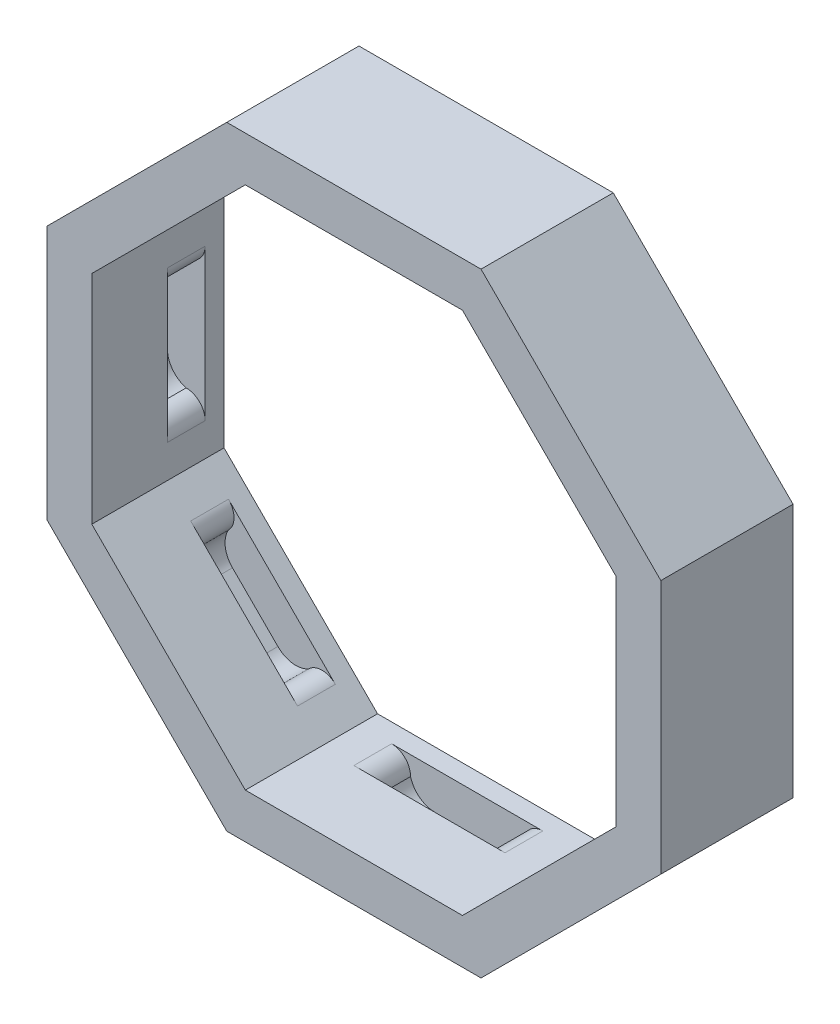
SolidWorks part; units mm, degrees
ref_plane "Plano frontal" through (0, 0, 0) normal (0, 0, 1) x (1, 0, 0)
ref_plane "Plano superior" through (0, 0, 0) normal (0, 1, 0) x (1, 0, 0)
ref_plane "Plano direito" through (0, 0, 0) normal (1, 0, 0) x (0, 0, -1)
sketch "Esboço1" plane through (0, 0, 0) normal (0, 0, 1) x (1, 0, 0)
  line L1 (63.5, -26.3026) -> (63.5, 26.3026)
  line L2 (63.5, 26.3026) -> (26.3026, 63.5)
  line L3 (26.3026, 63.5) -> (-26.3026, 63.5)
  line L4 (-26.3026, 63.5) -> (-63.5, 26.3026)
  line L5 (-63.5, 26.3026) -> (-63.5, -26.3026)
  line L6 (-63.5, -26.3026) -> (-26.3026, -63.5)
  line L7 (-26.3026, -63.5) -> (26.3026, -63.5)
  line L8 (26.3026, -63.5) -> (63.5, -26.3026)
  circle A0 centre (0, 0) radius 63.5 construction
  dimension "D1" = 127
extrude "Ressalto-extrusão1" add sketch "Esboço1" along normal blind 2.5
sketch "Esboço3"
sketch "Esboço2" plane through (0, 0, 0) normal (0, 0, -1) x (-1, 0, 0)
  line L0 (-45, 0) -> (45, 0) construction
  line L1 (-28.75, 0) -> (28.75, 0) construction
  line L2 (28.75, 0) -> (28.75, 8.5) construction
  line L3 (0, 0) -> (0, 75.734) construction
  line L4 (54, 24) -> (36, 24)
  line L5 (57, 21) -> (57, -21)
  line L6 (54, -24) -> (36, -24)
  line L7 (33, 21) -> (33, -21)
  line L8 (57, 24) -> (33, -24) construction
  line L9 (57, -24) -> (33, 24) construction
  line L10 (-57, -24) -> (-33, 24) construction
  line L11 (-57, 24) -> (-33, -24) construction
  line L12 (-28.75, 0) -> (-28.75, 8.5) construction
  line L13 (-33, 21) -> (-33, -21)
  line L14 (-54, -24) -> (-36, -24)
  line L15 (-57, 21) -> (-57, -21)
  line L16 (-54, 24) -> (-36, 24)
  line L17 (0, 0) -> (0, -57) construction
  line L18 (0, -57) -> (-6.731, -57) construction
  circle A0 centre (28.75, 8.5) radius 1.15
  circle A1 centre (28.75, -8.5) radius 1.15
  arc A2 (36, 24) -> (33, 21) centre (36, 21) ccw
  arc A3 (36, -24) -> (33, -21) centre (36, -21) cw
  arc A4 (57, -21) -> (54, -24) centre (54, -21) cw
  arc A5 (54, 24) -> (57, 21) centre (54, 21) cw
  arc A6 (-54, 24) -> (-57, 21) centre (-54, 21) ccw
  arc A7 (-57, -21) -> (-54, -24) centre (-54, -21) ccw
  arc A8 (-36, -24) -> (-33, -21) centre (-36, -21) ccw
  arc A9 (-36, 24) -> (-33, 21) centre (-36, 21) cw
  circle A10 centre (-28.75, -8.5) radius 1.15
  circle A11 centre (-28.75, 8.5) radius 1.15
  circle A12 centre (-6.731, -57) radius 1.15
  circle A13 centre (6.731, -57) radius 1.15
  circle A14 centre (6.731, 57) radius 1.15
  circle A15 centre (-6.731, 57) radius 1.15
  dimension "D6" = 3
  dimension "D8" = 6.731
  dimension "D1" = 45
  dimension "D2" = 48
  dimension "D3" = 24
  dimension "D4" = 28.75
  dimension "D5" = 8.5
  dimension "D7" = 57
sketch "Esboço4" plane through (0, 0, 0) normal (0, 0, -1) x (-1, 0, 0)
  line L0 (0, 0) -> (0, 12.88) construction
  line L1 (0, 0) -> (0, -12.88) construction
  line L2 (0, 0) -> (69.303, -40.0121) construction
  line L3 (0, 0) -> (-69.303, -40.0121) construction
  line L4 (0, 0) -> (0, 80.0242) construction
  circle A0 centre (0, 0) radius 3
  circle A1 centre (0, 0) radius 55 construction
  circle A3 centre (0, -12.88) radius 0.6604
  circle A4 centre (0, 12.88) radius 0.6604
  point P12 (0, 0)
  dimension "D1" = 12.88
  dimension "D2" = 12.88
  dimension "D3" = 3
extrude "Corte-extrusão1" cut sketch "Esboço4" against normal blind 5
sketch "Esboço5" plane through (0, 0, 0) normal (0, 0, 1) x (1, 0, 0)
  line L0 (-44.9013, -44.9013) -> (-42.0729, -42.0729) construction
  line L1 (-47.7297, -34.4361) -> (-49.7096, -36.416)
  line L2 (-42.0729, -40.093) -> (-44.0528, -42.0729)
  line L3 (-42.0729, -40.093) -> (-40.093, -42.0729)
  line L4 (-40.093, -42.0729) -> (-42.0729, -44.0528)
  line L5 (-44.0528, -42.0729) -> (-42.0729, -44.0528)
  line L6 (-42.0729, -40.093) -> (-42.0729, -44.0528) construction
  line L7 (-40.093, -42.0729) -> (-44.0528, -42.0729) construction
  line L8 (-47.7297, -34.4361) -> (-45.7498, -36.416)
  line L9 (-45.7498, -36.416) -> (-47.7297, -38.3959)
  line L10 (-49.7096, -36.416) -> (-47.7297, -38.3959)
  line L11 (-47.7297, -34.4361) -> (-47.7297, -38.3959) construction
  line L12 (-45.7498, -36.416) -> (-49.7096, -36.416) construction
  line L13 (-53.3866, -28.7792) -> (-55.3665, -30.7591)
  line L14 (-53.3866, -28.7792) -> (-51.4067, -30.7591)
  line L15 (-51.4067, -30.7591) -> (-53.3866, -32.739)
  line L16 (-55.3665, -30.7591) -> (-53.3866, -32.739)
  line L17 (-53.3866, -28.7792) -> (-53.3866, -32.739) construction
  line L18 (-51.4067, -30.7591) -> (-55.3665, -30.7591) construction
  line L19 (60.9, -25.2256) -> (59.0434, -27.0822)
  line L20 (57.0635, -25.1023) -> (59.0434, -27.0822)
  line L21 (58.1, -6.6) -> (58.1, -9.4)
  line L22 (58.1, -6.6) -> (60.9, -6.6)
  line L23 (60.9, -6.6) -> (60.9, -9.4)
  line L24 (58.1, -9.4) -> (60.9, -9.4)
  line L25 (58.1, -14.6) -> (58.1, -17.4)
  line L26 (-30.7591, -51.4067) -> (-30.7591, -55.3665) construction
  line L27 (-28.7792, -53.3866) -> (-32.739, -53.3866) construction
  line L28 (-36.416, -45.7498) -> (-36.416, -49.7096) construction
  line L29 (-34.4361, -47.7297) -> (-38.3959, -47.7297) construction
  line L30 (-42.0729, -40.093) -> (-42.0729, -44.0528) construction
  line L31 (-40.093, -42.0729) -> (-44.0528, -42.0729) construction
  line L32 (58.1, -14.6) -> (60.9, -14.6)
  line L33 (60.9, -14.6) -> (60.9, -17.4)
  line L34 (58.1, -17.4) -> (60.9, -17.4)
  line L35 (-30.7591, -55.3665) -> (-32.739, -53.3866)
  line L36 (-30.7591, -51.4067) -> (-32.739, -53.3866)
  line L37 (-28.7792, -53.3866) -> (-30.7591, -51.4067)
  line L38 (-28.7792, -53.3866) -> (-30.7591, -55.3665)
  line L39 (-36.416, -49.7096) -> (-38.3959, -47.7297)
  line L40 (-36.416, -45.7498) -> (-38.3959, -47.7297)
  line L41 (-34.4361, -47.7297) -> (-36.416, -45.7498)
  line L42 (-34.4361, -47.7297) -> (-36.416, -49.7096)
  line L43 (58.1, -22.6) -> (58.1, -24.0658)
  line L44 (58.1, -22.6) -> (60.9, -22.6)
  line L45 (60.9, -22.6) -> (60.9, -25.2256)
  line L46 (58.1, -24.0658) -> (57.0635, -25.1023)
  line L47 (58.1, 24.0658) -> (57.0635, 25.1023)
  line L48 (60.9, 22.6) -> (60.9, 25.2256)
  line L49 (58.1, 22.6) -> (60.9, 22.6)
  line L50 (58.1, 22.6) -> (58.1, 24.0658)
  line L51 (58.1, 17.4) -> (60.9, 17.4)
  line L52 (60.9, 14.6) -> (60.9, 17.4)
  line L53 (58.1, 14.6) -> (60.9, 14.6)
  line L54 (58.1, 14.6) -> (58.1, 17.4)
  line L55 (58.1, 9.4) -> (60.9, 9.4)
  line L56 (60.9, 6.6) -> (60.9, 9.4)
  line L57 (58.1, 6.6) -> (60.9, 6.6)
  line L58 (58.1, 1.4) -> (60.9, 1.4)
  line L59 (60.9, -1.4) -> (60.9, 1.4)
  line L60 (58.1, -1.4) -> (60.9, -1.4)
  line L61 (58.1, -1.4) -> (58.1, 1.4)
  line L62 (58.1, 6.6) -> (58.1, 9.4)
  line L63 (57.0635, 25.1023) -> (59.0434, 27.0822)
  line L64 (60.9, 25.2256) -> (59.0434, 27.0822)
  line L65 (58.1, -6.6) -> (60.9, -9.4) construction
  line L66 (60.9, -6.6) -> (58.1, -9.4) construction
  line L67 (58.1, -14.6) -> (60.9, -17.4) construction
  line L68 (60.9, -14.6) -> (58.1, -17.4) construction
  line L69 (60.9, 14.6) -> (58.1, 17.4) construction
  line L70 (58.1, 14.6) -> (60.9, 17.4) construction
  line L71 (9.4, 1.4) -> (6.6, -1.4) construction
  line L72 (16, 24) -> (0, 24) construction
  line L73 (0, 24) -> (-16, 24) construction
  line L74 (60.9, 6.6) -> (58.1, 9.4) construction
  line L75 (6.6, 25.4) -> (6.6, 22.6)
  line L76 (9.4, 22.6) -> (6.6, 22.6)
  line L77 (-25.4, 46.6) -> (-22.6, 49.4) construction
  line L78 (9.4, 25.4) -> (6.6, 22.6) construction
  line L79 (58.1, 6.6) -> (60.9, 9.4) construction
  line L80 (60.9, -1.4) -> (58.1, 1.4) construction
  line L81 (58.1, -1.4) -> (60.9, 1.4) construction
  line L82 (63.5, 0) -> (59.5, 0) construction
  line L83 (-25.2256, -60.9) -> (-27.0822, -59.0434)
  line L84 (-25.1023, -57.0635) -> (-27.0822, -59.0434)
  line L85 (-6.6, -58.1) -> (-9.4, -58.1)
  line L86 (-6.6, -58.1) -> (-6.6, -60.9)
  line L87 (-6.6, -60.9) -> (-9.4, -60.9)
  line L88 (-9.4, -58.1) -> (-9.4, -60.9)
  line L89 (-14.6, -58.1) -> (-17.4, -58.1)
  line L90 (-14.6, -58.1) -> (-14.6, -60.9)
  line L91 (9.4, 22.6) -> (6.6, 25.4) construction
  line L92 (0, 0) -> (0, 63.5) construction
  line L93 (-25.4, 49.4) -> (-22.6, 46.6) construction
  line L94 (-14.6, -60.9) -> (-17.4, -60.9)
  line L95 (-17.4, -58.1) -> (-17.4, -60.9)
  line L96 (-22.6, -58.1) -> (-24.0658, -58.1)
  line L97 (-22.6, -58.1) -> (-22.6, -60.9)
  line L98 (-22.6, -60.9) -> (-25.2256, -60.9)
  line L99 (-24.0658, -58.1) -> (-25.1023, -57.0635)
  line L100 (24.0658, -58.1) -> (25.1023, -57.0635)
  line L101 (22.6, -60.9) -> (25.2256, -60.9)
  line L102 (22.6, -58.1) -> (22.6, -60.9)
  line L103 (40.093, -42.0729) -> (44.0528, -42.0729) construction
  line L104 (42.0729, -40.093) -> (42.0729, -44.0528) construction
  line L105 (34.4361, -47.7297) -> (38.3959, -47.7297) construction
  line L106 (36.416, -45.7498) -> (36.416, -49.7096) construction
  line L107 (28.7792, -53.3866) -> (32.739, -53.3866) construction
  line L108 (30.7591, -51.4067) -> (30.7591, -55.3665) construction
  line L109 (22.6, -58.1) -> (24.0658, -58.1)
  line L110 (17.4, -58.1) -> (17.4, -60.9)
  line L111 (14.6, -60.9) -> (17.4, -60.9)
  line L112 (51.4067, -30.7591) -> (55.3665, -30.7591) construction
  line L113 (53.3866, -28.7792) -> (53.3866, -32.739) construction
  line L114 (45.7498, -36.416) -> (49.7096, -36.416) construction
  line L115 (47.7297, -34.4361) -> (47.7297, -38.3959) construction
  line L116 (40.093, -42.0729) -> (44.0528, -42.0729) construction
  line L117 (42.0729, -40.093) -> (42.0729, -44.0528) construction
  line L118 (44.9013, -44.9013) -> (42.0729, -42.0729) construction
  line L119 (14.6, -58.1) -> (14.6, -60.9)
  line L120 (14.6, -58.1) -> (17.4, -58.1)
  line L121 (9.4, -58.1) -> (9.4, -60.9)
  line L122 (6.6, -60.9) -> (9.4, -60.9)
  line L123 (6.6, -58.1) -> (6.6, -60.9)
  line L124 (1.4, -58.1) -> (1.4, -60.9)
  line L125 (-1.4, -60.9) -> (1.4, -60.9)
  line L126 (-1.4, -58.1) -> (-1.4, -60.9)
  line L127 (-1.4, -58.1) -> (1.4, -58.1)
  line L128 (6.6, -58.1) -> (9.4, -58.1)
  line L129 (25.1023, -57.0635) -> (27.0822, -59.0434)
  line L130 (25.2256, -60.9) -> (27.0822, -59.0434)
  line L131 (-6.6, -58.1) -> (-9.4, -60.9) construction
  line L132 (-6.6, -60.9) -> (-9.4, -58.1) construction
  line L133 (-14.6, -58.1) -> (-17.4, -60.9) construction
  line L134 (-14.6, -60.9) -> (-17.4, -58.1) construction
  line L135 (14.6, -60.9) -> (17.4, -58.1) construction
  line L136 (14.6, -58.1) -> (17.4, -60.9) construction
  line L137 (6.6, -60.9) -> (9.4, -58.1) construction
  line L138 (6.6, -58.1) -> (9.4, -60.9) construction
  line L139 (-1.4, -60.9) -> (1.4, -58.1) construction
  line L140 (-1.4, -58.1) -> (1.4, -60.9) construction
  line L141 (0, -63.5) -> (0, -59.5) construction
  line L142 (34.4361, -47.7297) -> (36.416, -49.7096)
  line L143 (40.093, -42.0729) -> (42.0729, -44.0528)
  line L144 (42.0729, -40.093) -> (44.0528, -42.0729)
  line L145 (34.4361, -47.7297) -> (36.416, -45.7498)
  line L146 (36.416, -45.7498) -> (38.3959, -47.7297)
  line L147 (36.416, -49.7096) -> (38.3959, -47.7297)
  line L148 (28.7792, -53.3866) -> (30.7591, -55.3665)
  line L149 (28.7792, -53.3866) -> (30.7591, -51.4067)
  line L150 (30.7591, -51.4067) -> (32.739, -53.3866)
  line L151 (30.7591, -55.3665) -> (32.739, -53.3866)
  line L152 (-60.9, 25.2256) -> (-59.0434, 27.0822)
  line L153 (-57.0635, 25.1023) -> (-59.0434, 27.0822)
  line L154 (-58.1, 6.6) -> (-58.1, 9.4)
  line L155 (-58.1, 6.6) -> (-60.9, 6.6)
  line L156 (-60.9, 6.6) -> (-60.9, 9.4)
  line L157 (-58.1, 9.4) -> (-60.9, 9.4)
  line L158 (-58.1, 14.6) -> (-58.1, 17.4)
  line L159 (55.3665, -30.7591) -> (53.3866, -32.739)
  line L160 (51.4067, -30.7591) -> (53.3866, -32.739)
  line L161 (53.3866, -28.7792) -> (51.4067, -30.7591)
  line L162 (53.3866, -28.7792) -> (55.3665, -30.7591)
  line L163 (49.7096, -36.416) -> (47.7297, -38.3959)
  line L164 (45.7498, -36.416) -> (47.7297, -38.3959)
  line L165 (47.7297, -34.4361) -> (45.7498, -36.416)
  line L166 (44.0528, -42.0729) -> (42.0729, -44.0528)
  line L167 (42.0729, -40.093) -> (40.093, -42.0729)
  line L168 (47.7297, -34.4361) -> (49.7096, -36.416)
  line L169 (44.9013, 44.9013) -> (42.0729, 42.0729) construction
  line L170 (42.0729, 40.093) -> (42.0729, 44.0528) construction
  line L171 (40.093, 42.0729) -> (44.0528, 42.0729) construction
  line L172 (47.7297, 34.4361) -> (47.7297, 38.3959) construction
  line L173 (45.7498, 36.416) -> (49.7096, 36.416) construction
  line L174 (53.3866, 28.7792) -> (53.3866, 32.739) construction
  line L175 (51.4067, 30.7591) -> (55.3665, 30.7591) construction
  line L176 (-58.1, 14.6) -> (-60.9, 14.6)
  line L177 (-60.9, 14.6) -> (-60.9, 17.4)
  line L178 (30.7591, 51.4067) -> (30.7591, 55.3665) construction
  line L179 (28.7792, 53.3866) -> (32.739, 53.3866) construction
  line L180 (36.416, 45.7498) -> (36.416, 49.7096) construction
  line L181 (34.4361, 47.7297) -> (38.3959, 47.7297) construction
  line L182 (42.0729, 40.093) -> (42.0729, 44.0528) construction
  line L183 (40.093, 42.0729) -> (44.0528, 42.0729) construction
  line L184 (6.6, 58.1) -> (9.4, 60.9) construction
  line L185 (6.6, 60.9) -> (9.4, 58.1) construction
  line L186 (14.6, 58.1) -> (17.4, 60.9) construction
  line L187 (14.6, 60.9) -> (17.4, 58.1) construction
  line L188 (-58.1, 17.4) -> (-60.9, 17.4)
  line L189 (-58.1, 22.6) -> (-58.1, 24.0658)
  line L190 (-58.1, 22.6) -> (-60.9, 22.6)
  line L191 (-60.9, 22.6) -> (-60.9, 25.2256)
  line L192 (-58.1, 24.0658) -> (-57.0635, 25.1023)
  line L193 (-58.1, -24.0658) -> (-57.0635, -25.1023)
  line L194 (-60.9, -22.6) -> (-60.9, -25.2256)
  line L195 (-58.1, -22.6) -> (-60.9, -22.6)
  line L196 (-14.6, 60.9) -> (-17.4, 58.1) construction
  line L197 (-14.6, 58.1) -> (-17.4, 60.9) construction
  line L198 (-6.6, 60.9) -> (-9.4, 58.1) construction
  line L199 (-6.6, 58.1) -> (-9.4, 60.9) construction
  line L200 (1.4, 60.9) -> (-1.4, 58.1) construction
  line L201 (1.4, 58.1) -> (-1.4, 60.9) construction
  line L202 (0, 63.5) -> (0, 59.5) construction
  line L203 (-40.093, 42.0729) -> (-44.0528, 42.0729) construction
  line L204 (-42.0729, 40.093) -> (-42.0729, 44.0528) construction
  line L205 (-34.4361, 47.7297) -> (-38.3959, 47.7297) construction
  line L206 (-36.416, 45.7498) -> (-36.416, 49.7096) construction
  line L207 (-28.7792, 53.3866) -> (-32.739, 53.3866) construction
  line L208 (-30.7591, 51.4067) -> (-30.7591, 55.3665) construction
  line L209 (-58.1, -22.6) -> (-58.1, -24.0658)
  line L210 (-58.1, -17.4) -> (-60.9, -17.4)
  line L211 (-51.4067, 30.7591) -> (-55.3665, 30.7591) construction
  line L212 (-53.3866, 28.7792) -> (-53.3866, 32.739) construction
  line L213 (-45.7498, 36.416) -> (-49.7096, 36.416) construction
  line L214 (-47.7297, 34.4361) -> (-47.7297, 38.3959) construction
  line L215 (-40.093, 42.0729) -> (-44.0528, 42.0729) construction
  line L216 (-42.0729, 40.093) -> (-42.0729, 44.0528) construction
  line L217 (-44.9013, 44.9013) -> (-42.0729, 42.0729) construction
  line L218 (47.7297, 34.4361) -> (49.7096, 36.416)
  line L219 (42.0729, 40.093) -> (44.0528, 42.0729)
  line L220 (42.0729, 40.093) -> (40.093, 42.0729)
  line L221 (40.093, 42.0729) -> (42.0729, 44.0528)
  line L222 (44.0528, 42.0729) -> (42.0729, 44.0528)
  line L223 (47.7297, 34.4361) -> (45.7498, 36.416)
  line L224 (45.7498, 36.416) -> (47.7297, 38.3959)
  line L225 (49.7096, 36.416) -> (47.7297, 38.3959)
  line L226 (53.3866, 28.7792) -> (55.3665, 30.7591)
  line L227 (53.3866, 28.7792) -> (51.4067, 30.7591)
  line L228 (51.4067, 30.7591) -> (53.3866, 32.739)
  line L229 (55.3665, 30.7591) -> (53.3866, 32.739)
  line L230 (-60.9, -14.6) -> (-60.9, -17.4)
  line L231 (-58.1, -14.6) -> (-60.9, -14.6)
  line L232 (-58.1, -14.6) -> (-58.1, -17.4)
  line L233 (-58.1, -9.4) -> (-60.9, -9.4)
  line L234 (25.2256, 60.9) -> (27.0822, 59.0434)
  line L235 (25.1023, 57.0635) -> (27.0822, 59.0434)
  line L236 (-60.9, -6.6) -> (-60.9, -9.4)
  line L237 (30.7591, 55.3665) -> (32.739, 53.3866)
  line L238 (30.7591, 51.4067) -> (32.739, 53.3866)
  line L239 (28.7792, 53.3866) -> (30.7591, 51.4067)
  line L240 (28.7792, 53.3866) -> (30.7591, 55.3665)
  line L241 (36.416, 49.7096) -> (38.3959, 47.7297)
  line L242 (36.416, 45.7498) -> (38.3959, 47.7297)
  line L243 (34.4361, 47.7297) -> (36.416, 45.7498)
  line L244 (34.4361, 47.7297) -> (36.416, 49.7096)
  line L245 (6.6, 58.1) -> (9.4, 58.1)
  line L246 (6.6, 58.1) -> (6.6, 60.9)
  line L247 (6.6, 60.9) -> (9.4, 60.9)
  line L248 (9.4, 58.1) -> (9.4, 60.9)
  line L249 (14.6, 58.1) -> (17.4, 58.1)
  line L250 (14.6, 58.1) -> (14.6, 60.9)
  line L251 (14.6, 60.9) -> (17.4, 60.9)
  line L252 (17.4, 58.1) -> (17.4, 60.9)
  line L253 (22.6, 58.1) -> (24.0658, 58.1)
  line L254 (22.6, 58.1) -> (22.6, 60.9)
  line L255 (22.6, 60.9) -> (25.2256, 60.9)
  line L256 (24.0658, 58.1) -> (25.1023, 57.0635)
  line L257 (-58.1, -6.6) -> (-60.9, -6.6)
  line L258 (-58.1, -1.4) -> (-60.9, -1.4)
  line L259 (-60.9, 1.4) -> (-60.9, -1.4)
  line L260 (-58.1, 1.4) -> (-60.9, 1.4)
  line L261 (-58.1, 1.4) -> (-58.1, -1.4)
  line L262 (-58.1, -6.6) -> (-58.1, -9.4)
  line L263 (-57.0635, -25.1023) -> (-59.0434, -27.0822)
  line L264 (-60.9, -25.2256) -> (-59.0434, -27.0822)
  line L265 (-58.1, 6.6) -> (-60.9, 9.4) construction
  line L266 (-60.9, 6.6) -> (-58.1, 9.4) construction
  line L267 (-58.1, 14.6) -> (-60.9, 17.4) construction
  line L268 (-60.9, 14.6) -> (-58.1, 17.4) construction
  line L269 (-60.9, -14.6) -> (-58.1, -17.4) construction
  line L270 (-58.1, -14.6) -> (-60.9, -17.4) construction
  line L271 (-24.0658, 58.1) -> (-25.1023, 57.0635)
  line L272 (-22.6, 60.9) -> (-25.2256, 60.9)
  line L273 (-22.6, 58.1) -> (-22.6, 60.9)
  line L274 (-22.6, 58.1) -> (-24.0658, 58.1)
  line L275 (-17.4, 58.1) -> (-17.4, 60.9)
  line L276 (-14.6, 60.9) -> (-17.4, 60.9)
  line L277 (-14.6, 58.1) -> (-14.6, 60.9)
  line L278 (-14.6, 58.1) -> (-17.4, 58.1)
  line L279 (-9.4, 58.1) -> (-9.4, 60.9)
  line L280 (-6.6, 60.9) -> (-9.4, 60.9)
  line L281 (-6.6, 58.1) -> (-6.6, 60.9)
  line L282 (-1.4, 58.1) -> (-1.4, 60.9)
  line L283 (1.4, 60.9) -> (-1.4, 60.9)
  line L284 (1.4, 58.1) -> (1.4, 60.9)
  line L285 (1.4, 58.1) -> (-1.4, 58.1)
  line L286 (-6.6, 58.1) -> (-9.4, 58.1)
  line L287 (-34.4361, 47.7297) -> (-36.416, 49.7096)
  line L288 (-40.093, 42.0729) -> (-42.0729, 44.0528)
  line L289 (-42.0729, 40.093) -> (-44.0528, 42.0729)
  line L290 (-34.4361, 47.7297) -> (-36.416, 45.7498)
  line L291 (-36.416, 45.7498) -> (-38.3959, 47.7297)
  line L292 (-36.416, 49.7096) -> (-38.3959, 47.7297)
  line L293 (-28.7792, 53.3866) -> (-30.7591, 55.3665)
  line L294 (-28.7792, 53.3866) -> (-30.7591, 51.4067)
  line L295 (-30.7591, 51.4067) -> (-32.739, 53.3866)
  line L296 (-30.7591, 55.3665) -> (-32.739, 53.3866)
  line L297 (-60.9, -6.6) -> (-58.1, -9.4) construction
  line L298 (-25.1023, 57.0635) -> (-27.0822, 59.0434)
  line L299 (-25.2256, 60.9) -> (-27.0822, 59.0434)
  line L300 (-58.1, -6.6) -> (-60.9, -9.4) construction
  line L301 (-60.9, 1.4) -> (-58.1, -1.4) construction
  line L302 (-58.1, 1.4) -> (-60.9, -1.4) construction
  line L303 (-63.5, 0) -> (-59.5, 0) construction
  line L304 (-55.3665, 30.7591) -> (-53.3866, 32.739)
  line L305 (-51.4067, 30.7591) -> (-53.3866, 32.739)
  line L306 (-53.3866, 28.7792) -> (-51.4067, 30.7591)
  line L307 (-53.3866, 28.7792) -> (-55.3665, 30.7591)
  line L308 (-49.7096, 36.416) -> (-47.7297, 38.3959)
  line L309 (-45.7498, 36.416) -> (-47.7297, 38.3959)
  line L310 (-47.7297, 34.4361) -> (-45.7498, 36.416)
  line L311 (-44.0528, 42.0729) -> (-42.0729, 44.0528)
  line L312 (-42.0729, 40.093) -> (-40.093, 42.0729)
  line L313 (-47.7297, 34.4361) -> (-49.7096, 36.416)
  line L314 (-17.4, 46.6) -> (-14.6, 49.4) construction
  line L315 (1.4, 1.4) -> (-1.4, 1.4)
  line L316 (1.4, 1.4) -> (1.4, -1.4)
  line L317 (1.4, -1.4) -> (-1.4, -1.4)
  line L318 (-1.4, 1.4) -> (-1.4, -1.4)
  line L319 (1.4, 1.4) -> (-1.4, -1.4) construction
  line L320 (1.4, -1.4) -> (-1.4, 1.4) construction
  line L321 (9.4, -1.4) -> (6.6, 1.4) construction
  line L322 (9.4, 1.4) -> (9.4, -1.4)
  line L323 (9.4, 1.4) -> (6.6, 1.4)
  line L324 (6.6, 1.4) -> (6.6, -1.4)
  line L325 (9.4, -1.4) -> (6.6, -1.4)
  line L326 (17.4, 1.4) -> (14.6, -1.4) construction
  line L327 (17.4, -1.4) -> (14.6, 1.4) construction
  line L328 (17.4, 1.4) -> (17.4, -1.4)
  line L329 (17.4, 1.4) -> (14.6, 1.4)
  line L330 (14.6, 1.4) -> (14.6, -1.4)
  line L331 (17.4, -1.4) -> (14.6, -1.4)
  line L332 (25.4, 1.4) -> (22.6, -1.4) construction
  line L333 (25.4, -1.4) -> (22.6, 1.4) construction
  line L334 (25.4, 1.4) -> (25.4, -1.4)
  line L335 (25.4, 1.4) -> (22.6, 1.4)
  line L336 (22.6, 1.4) -> (22.6, -1.4)
  line L337 (25.4, -1.4) -> (22.6, -1.4)
  line L338 (9.4, 25.4) -> (9.4, 22.6)
  line L339 (9.4, 25.4) -> (6.6, 25.4)
  line L340 (-9.4, 25.4) -> (-9.4, 22.6)
  line L341 (-6.6, 22.6) -> (-9.4, 22.6)
  line L342 (-6.6, 25.4) -> (-9.4, 22.6) construction
  line L343 (-6.6, 22.6) -> (-9.4, 25.4) construction
  line L344 (-6.6, 25.4) -> (-6.6, 22.6)
  line L345 (-6.6, 25.4) -> (-9.4, 25.4)
  line L346 (0, 0) -> (76.7252, 0) construction
  line L347 (-6.6, -22.6) -> (-9.4, -25.4) construction
  line L348 (-6.6, -25.4) -> (-9.4, -22.6) construction
  line L349 (-6.6, -25.4) -> (-9.4, -25.4)
  line L350 (-6.6, -25.4) -> (-6.6, -22.6)
  line L351 (-6.6, -22.6) -> (-9.4, -22.6)
  line L352 (-9.4, -25.4) -> (-9.4, -22.6)
  line L353 (9.4, -22.6) -> (6.6, -25.4) construction
  line L354 (9.4, -25.4) -> (6.6, -22.6) construction
  line L355 (9.4, -25.4) -> (6.6, -25.4)
  line L356 (9.4, 9.4) -> (6.6, 6.6) construction
  line L357 (9.4, 6.6) -> (6.6, 9.4) construction
  line L358 (9.4, 9.4) -> (9.4, 6.6)
  line L359 (9.4, 9.4) -> (6.6, 9.4)
  line L360 (6.6, 9.4) -> (6.6, 6.6)
  line L361 (9.4, 6.6) -> (6.6, 6.6)
  line L362 (17.4, 9.4) -> (14.6, 6.6) construction
  line L363 (17.4, 6.6) -> (14.6, 9.4) construction
  line L364 (17.4, 9.4) -> (17.4, 6.6)
  line L365 (17.4, 9.4) -> (14.6, 9.4)
  line L366 (14.6, 9.4) -> (14.6, 6.6)
  line L367 (17.4, 6.6) -> (14.6, 6.6)
  line L368 (25.4, 9.4) -> (22.6, 6.6) construction
  line L369 (25.4, 6.6) -> (22.6, 9.4) construction
  line L370 (25.4, 9.4) -> (25.4, 6.6)
  line L371 (25.4, 9.4) -> (22.6, 9.4)
  line L372 (22.6, 9.4) -> (22.6, 6.6)
  line L373 (25.4, 6.6) -> (22.6, 6.6)
  line L374 (9.4, -25.4) -> (9.4, -22.6)
  line L375 (9.4, -22.6) -> (6.6, -22.6)
  line L376 (6.6, -25.4) -> (6.6, -22.6)
  line L377 (0, 0) -> (0, -69.2181) construction
  line L378 (0, 0) -> (-73.0601, 0) construction
  line L379 (-1.4, 24) -> (1.4, 24) construction
  line L380 (0, 0) -> (0, 24) construction
  line L381 (32, 24) -> (32, 30.6) construction
  line L382 (0, 24) -> (32, 24) construction
  line L383 (38.6, 25.4) -> (41.4, 25.4)
  line L384 (30.6, 25.4) -> (33.4, 25.4)
  line L385 (30.6, 25.4) -> (30.6, 22.6)
  line L386 (30.6, 22.6) -> (33.4, 22.6)
  line L387 (33.4, 25.4) -> (33.4, 22.6)
  line L388 (30.6, 25.4) -> (33.4, 22.6) construction
  line L389 (30.6, 22.6) -> (33.4, 25.4) construction
  line L390 (38.6, 25.4) -> (38.6, 22.6)
  line L391 (38.6, 22.6) -> (41.4, 22.6)
  line L392 (9.4, 17.4) -> (6.6, 14.6) construction
  line L393 (9.4, 14.6) -> (6.6, 17.4) construction
  line L394 (9.4, 17.4) -> (9.4, 14.6)
  line L395 (9.4, 17.4) -> (6.6, 17.4)
  line L396 (6.6, 17.4) -> (6.6, 14.6)
  line L397 (9.4, 14.6) -> (6.6, 14.6)
  line L398 (17.4, 17.4) -> (14.6, 14.6) construction
  line L399 (17.4, 14.6) -> (14.6, 17.4) construction
  line L400 (17.4, 17.4) -> (17.4, 14.6)
  line L401 (17.4, 17.4) -> (14.6, 17.4)
  line L402 (14.6, 17.4) -> (14.6, 14.6)
  line L403 (17.4, 14.6) -> (14.6, 14.6)
  line L404 (25.4, 17.4) -> (22.6, 14.6) construction
  line L405 (25.4, 14.6) -> (22.6, 17.4) construction
  line L406 (25.4, 17.4) -> (25.4, 14.6)
  line L407 (25.4, 17.4) -> (22.6, 17.4)
  line L408 (22.6, 17.4) -> (22.6, 14.6)
  line L409 (25.4, 14.6) -> (22.6, 14.6)
  line L410 (41.4, 25.4) -> (41.4, 22.6)
  line L411 (38.6, 25.4) -> (41.4, 22.6) construction
  line L412 (38.6, 22.6) -> (41.4, 25.4) construction
  line L413 (46.6, 25.4) -> (49.4, 25.4)
  line L414 (46.6, 25.4) -> (46.6, 22.6)
  line L415 (46.6, 22.6) -> (49.4, 22.6)
  line L416 (49.4, 25.4) -> (49.4, 22.6)
  line L417 (46.6, 25.4) -> (49.4, 22.6) construction
  line L418 (46.6, 22.6) -> (49.4, 25.4) construction
  line L419 (38.6, 17.4) -> (41.4, 17.4)
  line L420 (38.6, 17.4) -> (38.6, 14.6)
  line L421 (38.6, 14.6) -> (41.4, 14.6)
  line L422 (41.4, 17.4) -> (41.4, 14.6)
  line L423 (38.6, 17.4) -> (41.4, 14.6) construction
  line L424 (38.6, 14.6) -> (41.4, 17.4) construction
  line L425 (46.6, 17.4) -> (49.4, 17.4)
  line L426 (46.6, 17.4) -> (46.6, 14.6)
  line L427 (46.6, 14.6) -> (49.4, 14.6)
  line L428 (49.4, 17.4) -> (49.4, 14.6)
  line L429 (46.6, 17.4) -> (49.4, 14.6) construction
  line L430 (46.6, 14.6) -> (49.4, 17.4) construction
  line L431 (38.6, 9.4) -> (41.4, 9.4)
  line L432 (38.6, 9.4) -> (38.6, 6.6)
  line L433 (38.6, 6.6) -> (41.4, 6.6)
  line L434 (17.4, 25.4) -> (14.6, 22.6) construction
  line L435 (17.4, 22.6) -> (14.6, 25.4) construction
  line L436 (17.4, 25.4) -> (17.4, 22.6)
  line L437 (17.4, 25.4) -> (14.6, 25.4)
  line L438 (14.6, 25.4) -> (14.6, 22.6)
  line L439 (17.4, 22.6) -> (14.6, 22.6)
  line L440 (25.4, 25.4) -> (22.6, 22.6) construction
  line L441 (25.4, 22.6) -> (22.6, 25.4) construction
  line L442 (25.4, 25.4) -> (25.4, 22.6)
  line L443 (25.4, 25.4) -> (22.6, 25.4)
  line L444 (22.6, 25.4) -> (22.6, 22.6)
  line L445 (25.4, 22.6) -> (22.6, 22.6)
  line L446 (41.4, 9.4) -> (41.4, 6.6)
  line L447 (38.6, 9.4) -> (41.4, 6.6) construction
  line L448 (38.6, 6.6) -> (41.4, 9.4) construction
  line L449 (46.6, 9.4) -> (49.4, 9.4)
  line L450 (46.6, 9.4) -> (46.6, 6.6)
  line L451 (46.6, 6.6) -> (49.4, 6.6)
  line L452 (49.4, 9.4) -> (49.4, 6.6)
  line L453 (46.6, 9.4) -> (49.4, 6.6) construction
  line L454 (46.6, 6.6) -> (49.4, 9.4) construction
  line L455 (38.6, 1.4) -> (41.4, 1.4)
  line L456 (38.6, 1.4) -> (38.6, -1.4)
  line L457 (38.6, -1.4) -> (41.4, -1.4)
  line L458 (41.4, 1.4) -> (41.4, -1.4)
  line L459 (38.6, 1.4) -> (41.4, -1.4) construction
  line L460 (38.6, -1.4) -> (41.4, 1.4) construction
  line L461 (46.6, 1.4) -> (49.4, 1.4)
  line L462 (46.6, 1.4) -> (46.6, -1.4)
  line L463 (46.6, -1.4) -> (49.4, -1.4)
  line L464 (9.4, 33.4) -> (6.6, 30.6) construction
  line L465 (9.4, 30.6) -> (6.6, 33.4) construction
  line L466 (9.4, 33.4) -> (9.4, 30.6)
  line L467 (9.4, 33.4) -> (6.6, 33.4)
  line L468 (6.6, 33.4) -> (6.6, 30.6)
  line L469 (9.4, 30.6) -> (6.6, 30.6)
  line L470 (17.4, 33.4) -> (14.6, 30.6) construction
  line L471 (17.4, 30.6) -> (14.6, 33.4) construction
  line L472 (17.4, 33.4) -> (17.4, 30.6)
  line L473 (17.4, 33.4) -> (14.6, 33.4)
  line L474 (14.6, 33.4) -> (14.6, 30.6)
  line L475 (17.4, 30.6) -> (14.6, 30.6)
  line L476 (25.4, 33.4) -> (22.6, 30.6) construction
  line L477 (25.4, 30.6) -> (22.6, 33.4) construction
  line L478 (25.4, 33.4) -> (25.4, 30.6)
  line L479 (25.4, 33.4) -> (22.6, 33.4)
  line L480 (22.6, 33.4) -> (22.6, 30.6)
  line L481 (25.4, 30.6) -> (22.6, 30.6)
  line L482 (33.4, 33.4) -> (30.6, 30.6) construction
  line L483 (33.4, 30.6) -> (30.6, 33.4) construction
  line L484 (33.4, 33.4) -> (33.4, 30.6)
  line L485 (33.4, 33.4) -> (30.6, 33.4)
  line L486 (30.6, 33.4) -> (30.6, 30.6)
  line L487 (33.4, 30.6) -> (30.6, 30.6)
  line L488 (41.4, 33.4) -> (38.6, 30.6) construction
  line L489 (41.4, 30.6) -> (38.6, 33.4) construction
  line L490 (41.4, 33.4) -> (41.4, 30.6)
  line L491 (41.4, 33.4) -> (38.6, 33.4)
  line L492 (38.6, 33.4) -> (38.6, 30.6)
  line L493 (41.4, 30.6) -> (38.6, 30.6)
  line L494 (49.4, 1.4) -> (49.4, -1.4)
  line L495 (46.6, 1.4) -> (49.4, -1.4) construction
  line L496 (46.6, -1.4) -> (49.4, 1.4) construction
  line L497 (38.6, -6.6) -> (41.4, -6.6)
  line L498 (38.6, -6.6) -> (38.6, -9.4)
  line L499 (38.6, -9.4) -> (41.4, -9.4)
  line L500 (9.4, 41.4) -> (6.6, 38.6) construction
  line L501 (9.4, 38.6) -> (6.6, 41.4) construction
  line L502 (9.4, 41.4) -> (9.4, 38.6)
  line L503 (9.4, 41.4) -> (6.6, 41.4)
  line L504 (6.6, 41.4) -> (6.6, 38.6)
  line L505 (9.4, 38.6) -> (6.6, 38.6)
  line L506 (17.4, 41.4) -> (14.6, 38.6) construction
  line L507 (17.4, 38.6) -> (14.6, 41.4) construction
  line L508 (17.4, 41.4) -> (17.4, 38.6)
  line L509 (17.4, 41.4) -> (14.6, 41.4)
  line L510 (14.6, 41.4) -> (14.6, 38.6)
  line L511 (17.4, 38.6) -> (14.6, 38.6)
  line L512 (25.4, 41.4) -> (22.6, 38.6) construction
  line L513 (25.4, 38.6) -> (22.6, 41.4) construction
  line L514 (25.4, 41.4) -> (25.4, 38.6)
  line L515 (25.4, 41.4) -> (22.6, 41.4)
  line L516 (22.6, 41.4) -> (22.6, 38.6)
  line L517 (25.4, 38.6) -> (22.6, 38.6)
  line L518 (33.4, 41.4) -> (30.6, 38.6) construction
  line L519 (33.4, 38.6) -> (30.6, 41.4) construction
  line L520 (33.4, 41.4) -> (33.4, 38.6)
  line L521 (33.4, 41.4) -> (30.6, 41.4)
  line L522 (30.6, 41.4) -> (30.6, 38.6)
  line L523 (33.4, 38.6) -> (30.6, 38.6)
  line L524 (41.4, -6.6) -> (41.4, -9.4)
  line L525 (38.6, -6.6) -> (41.4, -9.4) construction
  line L526 (38.6, -9.4) -> (41.4, -6.6) construction
  line L527 (46.6, -6.6) -> (49.4, -6.6)
  line L528 (46.6, -6.6) -> (46.6, -9.4)
  line L529 (46.6, -9.4) -> (49.4, -9.4)
  line L530 (49.4, -6.6) -> (49.4, -9.4)
  line L531 (46.6, -6.6) -> (49.4, -9.4) construction
  line L532 (46.6, -9.4) -> (49.4, -6.6) construction
  line L533 (38.6, -14.6) -> (41.4, -14.6)
  line L534 (38.6, -14.6) -> (38.6, -17.4)
  line L535 (38.6, -17.4) -> (41.4, -17.4)
  line L536 (9.4, 49.4) -> (6.6, 46.6) construction
  line L537 (9.4, 46.6) -> (6.6, 49.4) construction
  line L538 (9.4, 49.4) -> (9.4, 46.6)
  line L539 (9.4, 49.4) -> (6.6, 49.4)
  line L540 (6.6, 49.4) -> (6.6, 46.6)
  line L541 (9.4, 46.6) -> (6.6, 46.6)
  line L542 (17.4, 49.4) -> (14.6, 46.6) construction
  line L543 (17.4, 46.6) -> (14.6, 49.4) construction
  line L544 (17.4, 49.4) -> (17.4, 46.6)
  line L545 (17.4, 49.4) -> (14.6, 49.4)
  line L546 (14.6, 49.4) -> (14.6, 46.6)
  line L547 (17.4, 46.6) -> (14.6, 46.6)
  line L548 (25.4, 49.4) -> (22.6, 46.6) construction
  line L549 (25.4, 46.6) -> (22.6, 49.4) construction
  line L550 (25.4, 49.4) -> (25.4, 46.6)
  line L551 (25.4, 49.4) -> (22.6, 49.4)
  line L552 (22.6, 49.4) -> (22.6, 46.6)
  line L553 (25.4, 46.6) -> (22.6, 46.6)
  line L554 (41.4, -14.6) -> (41.4, -17.4)
  line L555 (38.6, -14.6) -> (41.4, -17.4) construction
  line L556 (38.6, -17.4) -> (41.4, -14.6) construction
  line L557 (46.6, -14.6) -> (49.4, -14.6)
  line L558 (46.6, -14.6) -> (46.6, -17.4)
  line L559 (46.6, -17.4) -> (49.4, -17.4)
  line L560 (49.4, -14.6) -> (49.4, -17.4)
  line L561 (46.6, -14.6) -> (49.4, -17.4) construction
  line L562 (46.6, -17.4) -> (49.4, -14.6) construction
  line L563 (48, -24) -> (32, -24) construction
  line L564 (32, -24) -> (32, -40) construction
  line L565 (32, -40) -> (16, -40) construction
  line L566 (41.4, -22.6) -> (41.4, -25.4)
  line L567 (38.6, -25.4) -> (41.4, -25.4)
  line L568 (38.6, -22.6) -> (41.4, -25.4) construction
  line L569 (46.6, -22.6) -> (49.4, -22.6)
  line L570 (46.6, -22.6) -> (46.6, -25.4)
  line L571 (46.6, -25.4) -> (49.4, -25.4)
  line L572 (1.4, 9.4) -> (-1.4, 6.6) construction
  line L573 (1.4, 6.6) -> (-1.4, 9.4) construction
  line L574 (1.4, 9.4) -> (1.4, 6.6)
  line L575 (1.4, 9.4) -> (-1.4, 9.4)
  line L576 (-1.4, 9.4) -> (-1.4, 6.6)
  line L577 (1.4, 6.6) -> (-1.4, 6.6)
  line L578 (1.4, 17.4) -> (-1.4, 14.6) construction
  line L579 (1.4, 14.6) -> (-1.4, 17.4) construction
  line L580 (1.4, 17.4) -> (1.4, 14.6)
  line L581 (1.4, 17.4) -> (-1.4, 17.4)
  line L582 (-1.4, 17.4) -> (-1.4, 14.6)
  line L583 (1.4, 14.6) -> (-1.4, 14.6)
  line L584 (1.4, 25.4) -> (-1.4, 22.6) construction
  line L585 (1.4, 22.6) -> (-1.4, 25.4) construction
  line L586 (1.4, 25.4) -> (1.4, 22.6)
  line L587 (1.4, 25.4) -> (-1.4, 25.4)
  line L588 (-1.4, 25.4) -> (-1.4, 22.6)
  line L589 (1.4, 22.6) -> (-1.4, 22.6)
  line L590 (1.4, 33.4) -> (-1.4, 30.6) construction
  line L591 (1.4, 30.6) -> (-1.4, 33.4) construction
  line L592 (1.4, 33.4) -> (1.4, 30.6)
  line L593 (1.4, 33.4) -> (-1.4, 33.4)
  line L594 (-1.4, 33.4) -> (-1.4, 30.6)
  line L595 (1.4, 30.6) -> (-1.4, 30.6)
  line L596 (1.4, 41.4) -> (-1.4, 38.6) construction
  line L597 (1.4, 38.6) -> (-1.4, 41.4) construction
  line L598 (1.4, 41.4) -> (1.4, 38.6)
  line L599 (1.4, 41.4) -> (-1.4, 41.4)
  line L600 (-1.4, 41.4) -> (-1.4, 38.6)
  line L601 (1.4, 38.6) -> (-1.4, 38.6)
  line L602 (1.4, 49.4) -> (-1.4, 46.6) construction
  line L603 (1.4, 46.6) -> (-1.4, 49.4) construction
  line L604 (1.4, 49.4) -> (1.4, 46.6)
  line L605 (1.4, 49.4) -> (-1.4, 49.4)
  line L606 (-1.4, 49.4) -> (-1.4, 46.6)
  line L607 (1.4, 46.6) -> (-1.4, 46.6)
  line L608 (-17.4, 49.4) -> (-14.6, 46.6) construction
  line L609 (-9.4, 46.6) -> (-6.6, 49.4) construction
  line L610 (-9.4, 49.4) -> (-6.6, 46.6) construction
  line L611 (-33.4, 38.6) -> (-30.6, 41.4) construction
  line L612 (-33.4, 41.4) -> (-30.6, 38.6) construction
  line L613 (-25.4, 38.6) -> (-22.6, 41.4) construction
  line L614 (-25.4, 41.4) -> (-22.6, 38.6) construction
  line L615 (-17.4, 38.6) -> (-14.6, 41.4) construction
  line L616 (-17.4, 41.4) -> (-14.6, 38.6) construction
  line L617 (-9.4, 38.6) -> (-6.6, 41.4) construction
  line L618 (-9.4, 41.4) -> (-6.6, 38.6) construction
  line L619 (49.4, -22.6) -> (49.4, -25.4)
  line L620 (46.6, -22.6) -> (49.4, -25.4) construction
  line L621 (46.6, -25.4) -> (49.4, -22.6) construction
  line L622 (30.6, 17.4) -> (33.4, 17.4)
  line L623 (-25.4, 46.6) -> (-22.6, 46.6)
  line L624 (-22.6, 49.4) -> (-22.6, 46.6)
  line L625 (-25.4, 49.4) -> (-22.6, 49.4)
  line L626 (-25.4, 49.4) -> (-25.4, 46.6)
  line L627 (-17.4, 46.6) -> (-14.6, 46.6)
  line L628 (-14.6, 49.4) -> (-14.6, 46.6)
  line L629 (-17.4, 49.4) -> (-14.6, 49.4)
  line L630 (-17.4, 49.4) -> (-17.4, 46.6)
  line L631 (-9.4, 46.6) -> (-6.6, 46.6)
  line L632 (-6.6, 49.4) -> (-6.6, 46.6)
  line L633 (-9.4, 49.4) -> (-6.6, 49.4)
  line L634 (-9.4, 49.4) -> (-9.4, 46.6)
  line L635 (-33.4, 38.6) -> (-30.6, 38.6)
  line L636 (-30.6, 41.4) -> (-30.6, 38.6)
  line L637 (-33.4, 41.4) -> (-30.6, 41.4)
  line L638 (-33.4, 41.4) -> (-33.4, 38.6)
  line L639 (-25.4, 38.6) -> (-22.6, 38.6)
  line L640 (-22.6, 41.4) -> (-22.6, 38.6)
  line L641 (-25.4, 41.4) -> (-22.6, 41.4)
  line L642 (-25.4, 41.4) -> (-25.4, 38.6)
  line L643 (-17.4, 38.6) -> (-14.6, 38.6)
  line L644 (-14.6, 41.4) -> (-14.6, 38.6)
  line L645 (-17.4, 41.4) -> (-14.6, 41.4)
  line L646 (-17.4, 41.4) -> (-17.4, 38.6)
  line L647 (-9.4, 38.6) -> (-6.6, 38.6)
  line L648 (-6.6, 41.4) -> (-6.6, 38.6)
  line L649 (-9.4, 41.4) -> (-6.6, 41.4)
  line L650 (-9.4, 41.4) -> (-9.4, 38.6)
  line L651 (30.6, 17.4) -> (30.6, 14.6)
  line L652 (30.6, 14.6) -> (33.4, 14.6)
  line L653 (-41.4, 30.6) -> (-38.6, 33.4) construction
  line L654 (-41.4, 33.4) -> (-38.6, 30.6) construction
  line L655 (-33.4, 30.6) -> (-30.6, 33.4) construction
  line L656 (-33.4, 33.4) -> (-30.6, 30.6) construction
  line L657 (-25.4, 30.6) -> (-22.6, 33.4) construction
  line L658 (-25.4, 33.4) -> (-22.6, 30.6) construction
  line L659 (-17.4, 30.6) -> (-14.6, 33.4) construction
  line L660 (-17.4, 33.4) -> (-14.6, 30.6) construction
  line L661 (-9.4, 30.6) -> (-6.6, 33.4) construction
  line L662 (-9.4, 33.4) -> (-6.6, 30.6) construction
  line L663 (-25.4, 22.6) -> (-22.6, 25.4) construction
  line L664 (-25.4, 25.4) -> (-22.6, 22.6) construction
  line L665 (-17.4, 22.6) -> (-14.6, 25.4) construction
  line L666 (-17.4, 25.4) -> (-14.6, 22.6) construction
  line L667 (-25.4, 14.6) -> (-22.6, 17.4) construction
  line L668 (-25.4, 17.4) -> (-22.6, 14.6) construction
  line L669 (-17.4, 14.6) -> (-14.6, 17.4) construction
  line L670 (-17.4, 17.4) -> (-14.6, 14.6) construction
  line L671 (-9.4, 14.6) -> (-6.6, 17.4) construction
  line L672 (-9.4, 17.4) -> (-6.6, 14.6) construction
  line L673 (-25.4, 6.6) -> (-22.6, 9.4) construction
  line L674 (-25.4, 9.4) -> (-22.6, 6.6) construction
  line L675 (33.4, 17.4) -> (33.4, 14.6)
  line L676 (30.6, 17.4) -> (33.4, 14.6) construction
  line L677 (-9.4, 6.6) -> (-6.6, 9.4) construction
  line L678 (-9.4, 9.4) -> (-6.6, 6.6) construction
  line L679 (-25.4, -1.4) -> (-22.6, 1.4) construction
  line L680 (-25.4, 1.4) -> (-22.6, -1.4) construction
  line L681 (30.6, 14.6) -> (33.4, 17.4) construction
  line L682 (30.6, 9.4) -> (33.4, 9.4)
  line L683 (-9.4, -1.4) -> (-6.6, 1.4) construction
  line L684 (-9.4, 1.4) -> (-6.6, -1.4) construction
  line L685 (30.6, 9.4) -> (30.6, 6.6)
  line L686 (30.6, 6.6) -> (33.4, 6.6)
  line L687 (33.4, 9.4) -> (33.4, 6.6)
  line L688 (30.6, 9.4) -> (33.4, 6.6) construction
  line L689 (-41.4, 30.6) -> (-38.6, 30.6)
  line L690 (-38.6, 33.4) -> (-38.6, 30.6)
  line L691 (-41.4, 33.4) -> (-38.6, 33.4)
  line L692 (-41.4, 33.4) -> (-41.4, 30.6)
  line L693 (-33.4, 30.6) -> (-30.6, 30.6)
  line L694 (-30.6, 33.4) -> (-30.6, 30.6)
  line L695 (-33.4, 33.4) -> (-30.6, 33.4)
  line L696 (-33.4, 33.4) -> (-33.4, 30.6)
  line L697 (-25.4, 30.6) -> (-22.6, 30.6)
  line L698 (-22.6, 33.4) -> (-22.6, 30.6)
  line L699 (-25.4, 33.4) -> (-22.6, 33.4)
  line L700 (-25.4, 33.4) -> (-25.4, 30.6)
  line L701 (-17.4, 30.6) -> (-14.6, 30.6)
  line L702 (-14.6, 33.4) -> (-14.6, 30.6)
  line L703 (-17.4, 33.4) -> (-14.6, 33.4)
  line L704 (-17.4, 33.4) -> (-17.4, 30.6)
  line L705 (-9.4, 30.6) -> (-6.6, 30.6)
  line L706 (-6.6, 33.4) -> (-6.6, 30.6)
  line L707 (-9.4, 33.4) -> (-6.6, 33.4)
  line L708 (-9.4, 33.4) -> (-9.4, 30.6)
  line L709 (-25.4, 22.6) -> (-22.6, 22.6)
  line L710 (-22.6, 25.4) -> (-22.6, 22.6)
  line L711 (-25.4, 25.4) -> (-22.6, 25.4)
  line L712 (-25.4, 25.4) -> (-25.4, 22.6)
  line L713 (-17.4, 22.6) -> (-14.6, 22.6)
  line L714 (-14.6, 25.4) -> (-14.6, 22.6)
  line L715 (-17.4, 25.4) -> (-14.6, 25.4)
  line L716 (-17.4, 25.4) -> (-17.4, 22.6)
  line L717 (-25.4, 14.6) -> (-22.6, 14.6)
  line L718 (-22.6, 17.4) -> (-22.6, 14.6)
  line L719 (-25.4, 17.4) -> (-22.6, 17.4)
  line L720 (-25.4, 17.4) -> (-25.4, 14.6)
  line L721 (-17.4, 14.6) -> (-14.6, 14.6)
  line L722 (-14.6, 17.4) -> (-14.6, 14.6)
  line L723 (-17.4, 17.4) -> (-14.6, 17.4)
  line L724 (-17.4, 17.4) -> (-17.4, 14.6)
  line L725 (-9.4, 14.6) -> (-6.6, 14.6)
  line L726 (-6.6, 17.4) -> (-6.6, 14.6)
  line L727 (-9.4, 17.4) -> (-6.6, 17.4)
  line L728 (-9.4, 17.4) -> (-9.4, 14.6)
  line L729 (-25.4, 6.6) -> (-22.6, 6.6)
  line L730 (-22.6, 9.4) -> (-22.6, 6.6)
  line L731 (-25.4, 9.4) -> (-22.6, 9.4)
  line L732 (-25.4, 9.4) -> (-25.4, 6.6)
  line L733 (30.6, 6.6) -> (33.4, 9.4) construction
  line L734 (30.6, 1.4) -> (33.4, 1.4)
  line L735 (30.6, 1.4) -> (30.6, -1.4)
  line L736 (30.6, -1.4) -> (33.4, -1.4)
  line L737 (-9.4, 6.6) -> (-6.6, 6.6)
  line L738 (-6.6, 9.4) -> (-6.6, 6.6)
  line L739 (-9.4, 9.4) -> (-6.6, 9.4)
  line L740 (-9.4, 9.4) -> (-9.4, 6.6)
  line L741 (-25.4, -1.4) -> (-22.6, -1.4)
  line L742 (-22.6, 1.4) -> (-22.6, -1.4)
  line L743 (-25.4, 1.4) -> (-22.6, 1.4)
  line L744 (-25.4, 1.4) -> (-25.4, -1.4)
  line L745 (33.4, 1.4) -> (33.4, -1.4)
  line L746 (30.6, 1.4) -> (33.4, -1.4) construction
  line L747 (30.6, -1.4) -> (33.4, 1.4) construction
  line L748 (30.6, -6.6) -> (33.4, -6.6)
  line L749 (-9.4, -1.4) -> (-6.6, -1.4)
  line L750 (-6.6, 1.4) -> (-6.6, -1.4)
  line L751 (-9.4, 1.4) -> (-6.6, 1.4)
  line L752 (-9.4, 1.4) -> (-9.4, -1.4)
  line L753 (30.6, -6.6) -> (30.6, -9.4)
  line L754 (30.6, -9.4) -> (33.4, -9.4)
  line L755 (41.4, -30.6) -> (38.6, -33.4) construction
  line L756 (41.4, -33.4) -> (38.6, -30.6) construction
  line L757 (33.4, -6.6) -> (33.4, -9.4)
  line L758 (30.6, -6.6) -> (33.4, -9.4) construction
  line L759 (30.6, -9.4) -> (33.4, -6.6) construction
  line L760 (30.6, -14.6) -> (33.4, -14.6)
  line L761 (41.4, -30.6) -> (38.6, -30.6)
  line L762 (38.6, -33.4) -> (38.6, -30.6)
  line L763 (41.4, -33.4) -> (38.6, -33.4)
  line L764 (41.4, -33.4) -> (41.4, -30.6)
  line L765 (30.6, -14.6) -> (30.6, -17.4)
  line L766 (30.6, -17.4) -> (33.4, -17.4)
  line L767 (33.4, -14.6) -> (33.4, -17.4)
  line L768 (30.6, -14.6) -> (33.4, -17.4) construction
  line L769 (30.6, -17.4) -> (33.4, -14.6) construction
  line L770 (30.6, -22.6) -> (33.4, -22.6)
  line L771 (-41.4, -33.4) -> (-38.6, -30.6) construction
  line L772 (-41.4, -30.6) -> (-38.6, -33.4) construction
  line L773 (-41.4, -33.4) -> (-41.4, -30.6)
  line L774 (-41.4, -33.4) -> (-38.6, -33.4)
  line L775 (-38.6, -33.4) -> (-38.6, -30.6)
  line L776 (-41.4, -30.6) -> (-38.6, -30.6)
  line L777 (-9.4, -9.4) -> (-6.6, -6.6) construction
  line L778 (-9.4, -6.6) -> (-6.6, -9.4) construction
  line L779 (30.6, -22.6) -> (30.6, -25.4)
  line L780 (30.6, -25.4) -> (33.4, -25.4)
  line L781 (-25.4, -9.4) -> (-22.6, -6.6) construction
  line L782 (-25.4, -6.6) -> (-22.6, -9.4) construction
  line L783 (-9.4, -17.4) -> (-6.6, -14.6) construction
  line L784 (-9.4, -14.6) -> (-6.6, -17.4) construction
  line L785 (-17.4, -17.4) -> (-14.6, -14.6) construction
  line L786 (-17.4, -14.6) -> (-14.6, -17.4) construction
  line L787 (-25.4, -17.4) -> (-22.6, -14.6) construction
  line L788 (-25.4, -14.6) -> (-22.6, -17.4) construction
  line L789 (-17.4, -25.4) -> (-14.6, -22.6) construction
  line L790 (-17.4, -22.6) -> (-14.6, -25.4) construction
  line L791 (-25.4, -25.4) -> (-22.6, -22.6) construction
  line L792 (-25.4, -22.6) -> (-22.6, -25.4) construction
  line L793 (-9.4, -33.4) -> (-6.6, -30.6) construction
  line L794 (-9.4, -30.6) -> (-6.6, -33.4) construction
  line L795 (-17.4, -33.4) -> (-14.6, -30.6) construction
  line L796 (-17.4, -30.6) -> (-14.6, -33.4) construction
  line L797 (-25.4, -33.4) -> (-22.6, -30.6) construction
  line L798 (-25.4, -30.6) -> (-22.6, -33.4) construction
  line L799 (38.6, -22.6) -> (41.4, -22.6)
  line L800 (38.6, -25.4) -> (41.4, -22.6) construction
  line L801 (-9.4, -41.4) -> (-6.6, -38.6) construction
  line L802 (-9.4, -38.6) -> (-6.6, -41.4) construction
  line L803 (-17.4, -41.4) -> (-14.6, -38.6) construction
  line L804 (-17.4, -38.6) -> (-14.6, -41.4) construction
  line L805 (38.6, -22.6) -> (38.6, -25.4)
  line L806 (33.4, -30.6) -> (33.4, -33.4)
  line L807 (-33.4, -41.4) -> (-30.6, -38.6) construction
  line L808 (-33.4, -38.6) -> (-30.6, -41.4) construction
  line L809 (-9.4, -49.4) -> (-6.6, -46.6) construction
  line L810 (-9.4, -46.6) -> (-6.6, -49.4) construction
  line L811 (-17.4, -49.4) -> (-14.6, -46.6) construction
  line L812 (1.4, -46.6) -> (-1.4, -49.4) construction
  line L813 (1.4, -49.4) -> (-1.4, -46.6) construction
  line L814 (1.4, -38.6) -> (-1.4, -41.4) construction
  line L815 (1.4, -41.4) -> (-1.4, -38.6) construction
  line L816 (1.4, -30.6) -> (-1.4, -33.4) construction
  line L817 (1.4, -33.4) -> (-1.4, -30.6) construction
  line L818 (1.4, -22.6) -> (-1.4, -25.4) construction
  line L819 (1.4, -25.4) -> (-1.4, -22.6) construction
  line L820 (1.4, -14.6) -> (-1.4, -17.4) construction
  line L821 (1.4, -17.4) -> (-1.4, -14.6) construction
  line L822 (1.4, -6.6) -> (-1.4, -9.4) construction
  line L823 (1.4, -9.4) -> (-1.4, -6.6) construction
  line L824 (33.4, -22.6) -> (33.4, -25.4)
  line L825 (30.6, -22.6) -> (33.4, -25.4) construction
  line L826 (25.4, -46.6) -> (22.6, -49.4) construction
  line L827 (25.4, -49.4) -> (22.6, -46.6) construction
  line L828 (17.4, -46.6) -> (14.6, -49.4) construction
  line L829 (17.4, -49.4) -> (14.6, -46.6) construction
  line L830 (9.4, -46.6) -> (6.6, -49.4) construction
  line L831 (9.4, -49.4) -> (6.6, -46.6) construction
  line L832 (33.4, -38.6) -> (30.6, -41.4) construction
  line L833 (33.4, -41.4) -> (30.6, -38.6) construction
  line L834 (30.6, -33.4) -> (33.4, -33.4)
  line L835 (30.6, -30.6) -> (33.4, -33.4) construction
  line L836 (17.4, -38.6) -> (14.6, -41.4) construction
  line L837 (17.4, -41.4) -> (14.6, -38.6) construction
  line L838 (9.4, -38.6) -> (6.6, -41.4) construction
  line L839 (9.4, -41.4) -> (6.6, -38.6) construction
  line L840 (30.6, -30.6) -> (33.4, -30.6)
  line L841 (30.6, -33.4) -> (33.4, -30.6) construction
  line L842 (25.4, -30.6) -> (22.6, -33.4) construction
  line L843 (25.4, -33.4) -> (22.6, -30.6) construction
  line L844 (17.4, -30.6) -> (14.6, -33.4) construction
  line L845 (17.4, -33.4) -> (14.6, -30.6) construction
  line L846 (9.4, -30.6) -> (6.6, -33.4) construction
  line L847 (9.4, -33.4) -> (6.6, -30.6) construction
  line L848 (25.4, -22.6) -> (22.6, -25.4) construction
  line L849 (25.4, -25.4) -> (22.6, -22.6) construction
  line L850 (17.4, -22.6) -> (14.6, -25.4) construction
  line L851 (17.4, -25.4) -> (14.6, -22.6) construction
  line L852 (25.4, -14.6) -> (22.6, -17.4) construction
  line L853 (25.4, -17.4) -> (22.6, -14.6) construction
  line L854 (17.4, -14.6) -> (14.6, -17.4) construction
  line L855 (17.4, -17.4) -> (14.6, -14.6) construction
  line L856 (9.4, -14.6) -> (6.6, -17.4) construction
  line L857 (9.4, -17.4) -> (6.6, -14.6) construction
  line L858 (25.4, -6.6) -> (22.6, -9.4) construction
  line L859 (25.4, -9.4) -> (22.6, -6.6) construction
  line L860 (17.4, -6.6) -> (14.6, -9.4) construction
  line L861 (17.4, -9.4) -> (14.6, -6.6) construction
  line L862 (9.4, -6.6) -> (6.6, -9.4) construction
  line L863 (9.4, -9.4) -> (6.6, -6.6) construction
  line L864 (-17.4, -46.6) -> (-14.6, -49.4) construction
  line L865 (-25.4, -49.4) -> (-22.6, -46.6) construction
  line L866 (-25.4, -46.6) -> (-22.6, -49.4) construction
  line L867 (30.6, -25.4) -> (33.4, -22.6) construction
  line L868 (-30.6, -25.4) -> (-33.4, -22.6) construction
  line L869 (-9.4, -9.4) -> (-9.4, -6.6)
  line L870 (-9.4, -9.4) -> (-6.6, -9.4)
  line L871 (-6.6, -9.4) -> (-6.6, -6.6)
  line L872 (-9.4, -6.6) -> (-6.6, -6.6)
  line L873 (-30.6, -22.6) -> (-33.4, -25.4) construction
  line L874 (-30.6, -17.4) -> (-33.4, -14.6) construction
  line L875 (-30.6, -14.6) -> (-33.4, -17.4) construction
  line L876 (-30.6, 14.6) -> (-33.4, 17.4) construction
  line L877 (-25.4, -9.4) -> (-25.4, -6.6)
  line L878 (-25.4, -9.4) -> (-22.6, -9.4)
  line L879 (-22.6, -9.4) -> (-22.6, -6.6)
  line L880 (-25.4, -6.6) -> (-22.6, -6.6)
  line L881 (-9.4, -17.4) -> (-9.4, -14.6)
  line L882 (-9.4, -17.4) -> (-6.6, -17.4)
  line L883 (-6.6, -17.4) -> (-6.6, -14.6)
  line L884 (-9.4, -14.6) -> (-6.6, -14.6)
  line L885 (-17.4, -17.4) -> (-17.4, -14.6)
  line L886 (-17.4, -17.4) -> (-14.6, -17.4)
  line L887 (-14.6, -17.4) -> (-14.6, -14.6)
  line L888 (-17.4, -14.6) -> (-14.6, -14.6)
  line L889 (-25.4, -17.4) -> (-25.4, -14.6)
  line L890 (-25.4, -17.4) -> (-22.6, -17.4)
  line L891 (-22.6, -17.4) -> (-22.6, -14.6)
  line L892 (-25.4, -14.6) -> (-22.6, -14.6)
  line L893 (-17.4, -25.4) -> (-17.4, -22.6)
  line L894 (-17.4, -25.4) -> (-14.6, -25.4)
  line L895 (-14.6, -25.4) -> (-14.6, -22.6)
  line L896 (-17.4, -22.6) -> (-14.6, -22.6)
  line L897 (-25.4, -25.4) -> (-25.4, -22.6)
  line L898 (-25.4, -25.4) -> (-22.6, -25.4)
  line L899 (-22.6, -25.4) -> (-22.6, -22.6)
  line L900 (-25.4, -22.6) -> (-22.6, -22.6)
  line L901 (-9.4, -33.4) -> (-9.4, -30.6)
  line L902 (-9.4, -33.4) -> (-6.6, -33.4)
  line L903 (-6.6, -33.4) -> (-6.6, -30.6)
  line L904 (-9.4, -30.6) -> (-6.6, -30.6)
  line L905 (-17.4, -33.4) -> (-17.4, -30.6)
  line L906 (-17.4, -33.4) -> (-14.6, -33.4)
  line L907 (-14.6, -33.4) -> (-14.6, -30.6)
  line L908 (-17.4, -30.6) -> (-14.6, -30.6)
  line L909 (-25.4, -33.4) -> (-25.4, -30.6)
  line L910 (-25.4, -33.4) -> (-22.6, -33.4)
  line L911 (-22.6, -33.4) -> (-22.6, -30.6)
  line L912 (-25.4, -30.6) -> (-22.6, -30.6)
  line L913 (30.6, -30.6) -> (30.6, -33.4)
  line L914 (25.4, -38.6) -> (25.4, -41.4)
  line L915 (22.6, -41.4) -> (25.4, -41.4)
  line L916 (22.6, -38.6) -> (25.4, -41.4) construction
  line L917 (-9.4, -41.4) -> (-9.4, -38.6)
  line L918 (-9.4, -41.4) -> (-6.6, -41.4)
  line L919 (-6.6, -41.4) -> (-6.6, -38.6)
  line L920 (-9.4, -38.6) -> (-6.6, -38.6)
  line L921 (-17.4, -41.4) -> (-17.4, -38.6)
  line L922 (-17.4, -41.4) -> (-14.6, -41.4)
  line L923 (-14.6, -41.4) -> (-14.6, -38.6)
  line L924 (-17.4, -38.6) -> (-14.6, -38.6)
  line L925 (22.6, -38.6) -> (25.4, -38.6)
  line L926 (22.6, -41.4) -> (25.4, -38.6) construction
  line L927 (22.6, -38.6) -> (22.6, -41.4)
  line L928 (-22.6, -41.4) -> (-25.4, -38.6) construction
  line L929 (-33.4, -41.4) -> (-33.4, -38.6)
  line L930 (-33.4, -41.4) -> (-30.6, -41.4)
  line L931 (-30.6, -41.4) -> (-30.6, -38.6)
  line L932 (-33.4, -38.6) -> (-30.6, -38.6)
  line L933 (-9.4, -49.4) -> (-9.4, -46.6)
  line L934 (-9.4, -49.4) -> (-6.6, -49.4)
  line L935 (-6.6, -49.4) -> (-6.6, -46.6)
  line L936 (-9.4, -46.6) -> (-6.6, -46.6)
  line L937 (-17.4, -49.4) -> (-17.4, -46.6)
  line L938 (-17.4, -49.4) -> (-14.6, -49.4)
  line L939 (-14.6, -49.4) -> (-14.6, -46.6)
  line L940 (-17.4, -46.6) -> (-14.6, -46.6)
  line L941 (-25.4, -49.4) -> (-25.4, -46.6)
  line L942 (-25.4, -49.4) -> (-22.6, -49.4)
  line L943 (-22.6, -49.4) -> (-22.6, -46.6)
  line L944 (-25.4, -46.6) -> (-22.6, -46.6)
  line L945 (-30.6, 17.4) -> (-33.4, 14.6) construction
  line L946 (-46.6, -25.4) -> (-49.4, -22.6) construction
  line L947 (-46.6, -22.6) -> (-49.4, -25.4) construction
  line L948 (-22.6, -38.6) -> (-25.4, -41.4) construction
  line L949 (1.4, -46.6) -> (-1.4, -46.6)
  line L950 (-1.4, -49.4) -> (-1.4, -46.6)
  line L951 (1.4, -49.4) -> (-1.4, -49.4)
  line L952 (1.4, -49.4) -> (1.4, -46.6)
  line L953 (1.4, -38.6) -> (-1.4, -38.6)
  line L954 (-1.4, -41.4) -> (-1.4, -38.6)
  line L955 (1.4, -41.4) -> (-1.4, -41.4)
  line L956 (1.4, -41.4) -> (1.4, -38.6)
  line L957 (1.4, -30.6) -> (-1.4, -30.6)
  line L958 (-1.4, -33.4) -> (-1.4, -30.6)
  line L959 (1.4, -33.4) -> (-1.4, -33.4)
  line L960 (1.4, -33.4) -> (1.4, -30.6)
  line L961 (1.4, -22.6) -> (-1.4, -22.6)
  line L962 (-1.4, -25.4) -> (-1.4, -22.6)
  line L963 (1.4, -25.4) -> (-1.4, -25.4)
  line L964 (1.4, -25.4) -> (1.4, -22.6)
  line L965 (1.4, -14.6) -> (-1.4, -14.6)
  line L966 (-1.4, -17.4) -> (-1.4, -14.6)
  line L967 (1.4, -17.4) -> (-1.4, -17.4)
  line L968 (1.4, -17.4) -> (1.4, -14.6)
  line L969 (1.4, -6.6) -> (-1.4, -6.6)
  line L970 (-1.4, -9.4) -> (-1.4, -6.6)
  line L971 (1.4, -9.4) -> (-1.4, -9.4)
  line L972 (1.4, -9.4) -> (1.4, -6.6)
  line L973 (-22.6, -38.6) -> (-22.6, -41.4)
  line L974 (-46.6, -17.4) -> (-49.4, -14.6) construction
  line L975 (-46.6, -14.6) -> (-49.4, -17.4) construction
  line L976 (-38.6, -17.4) -> (-41.4, -14.6) construction
  line L977 (25.4, -46.6) -> (22.6, -46.6)
  line L978 (22.6, -49.4) -> (22.6, -46.6)
  line L979 (25.4, -49.4) -> (22.6, -49.4)
  line L980 (25.4, -49.4) -> (25.4, -46.6)
  line L981 (17.4, -46.6) -> (14.6, -46.6)
  line L982 (14.6, -49.4) -> (14.6, -46.6)
  line L983 (17.4, -49.4) -> (14.6, -49.4)
  line L984 (17.4, -49.4) -> (17.4, -46.6)
  line L985 (9.4, -46.6) -> (6.6, -46.6)
  line L986 (6.6, -49.4) -> (6.6, -46.6)
  line L987 (9.4, -49.4) -> (6.6, -49.4)
  line L988 (9.4, -49.4) -> (9.4, -46.6)
  line L989 (33.4, -38.6) -> (30.6, -38.6)
  line L990 (30.6, -41.4) -> (30.6, -38.6)
  line L991 (33.4, -41.4) -> (30.6, -41.4)
  line L992 (33.4, -41.4) -> (33.4, -38.6)
  line L993 (-22.6, -38.6) -> (-25.4, -38.6)
  line L994 (-22.6, -41.4) -> (-25.4, -41.4)
  line L995 (-25.4, -38.6) -> (-25.4, -41.4)
  line L996 (-30.6, -33.4) -> (-33.4, -30.6) construction
  line L997 (17.4, -38.6) -> (14.6, -38.6)
  line L998 (14.6, -41.4) -> (14.6, -38.6)
  line L999 (17.4, -41.4) -> (14.6, -41.4)
  line L1000 (17.4, -41.4) -> (17.4, -38.6)
  line L1001 (9.4, -38.6) -> (6.6, -38.6)
  line L1002 (6.6, -41.4) -> (6.6, -38.6)
  line L1003 (9.4, -41.4) -> (6.6, -41.4)
  line L1004 (9.4, -41.4) -> (9.4, -38.6)
  line L1005 (-30.6, -30.6) -> (-33.4, -33.4) construction
  line L1006 (-30.6, -30.6) -> (-30.6, -33.4)
  line L1007 (-30.6, -30.6) -> (-33.4, -30.6)
  line L1008 (-30.6, -33.4) -> (-33.4, -33.4)
  line L1009 (25.4, -30.6) -> (22.6, -30.6)
  line L1010 (22.6, -33.4) -> (22.6, -30.6)
  line L1011 (25.4, -33.4) -> (22.6, -33.4)
  line L1012 (25.4, -33.4) -> (25.4, -30.6)
  line L1013 (17.4, -30.6) -> (14.6, -30.6)
  line L1014 (14.6, -33.4) -> (14.6, -30.6)
  line L1015 (17.4, -33.4) -> (14.6, -33.4)
  line L1016 (17.4, -33.4) -> (17.4, -30.6)
  line L1017 (9.4, -30.6) -> (6.6, -30.6)
  line L1018 (6.6, -33.4) -> (6.6, -30.6)
  line L1019 (9.4, -33.4) -> (6.6, -33.4)
  line L1020 (9.4, -33.4) -> (9.4, -30.6)
  line L1021 (25.4, -22.6) -> (22.6, -22.6)
  line L1022 (22.6, -25.4) -> (22.6, -22.6)
  line L1023 (25.4, -25.4) -> (22.6, -25.4)
  line L1024 (25.4, -25.4) -> (25.4, -22.6)
  line L1025 (17.4, -22.6) -> (14.6, -22.6)
  line L1026 (14.6, -25.4) -> (14.6, -22.6)
  line L1027 (17.4, -25.4) -> (14.6, -25.4)
  line L1028 (17.4, -25.4) -> (17.4, -22.6)
  line L1029 (25.4, -14.6) -> (22.6, -14.6)
  line L1030 (22.6, -17.4) -> (22.6, -14.6)
  line L1031 (25.4, -17.4) -> (22.6, -17.4)
  line L1032 (25.4, -17.4) -> (25.4, -14.6)
  line L1033 (17.4, -14.6) -> (14.6, -14.6)
  line L1034 (14.6, -17.4) -> (14.6, -14.6)
  line L1035 (17.4, -17.4) -> (14.6, -17.4)
  line L1036 (17.4, -17.4) -> (17.4, -14.6)
  line L1037 (9.4, -14.6) -> (6.6, -14.6)
  line L1038 (6.6, -17.4) -> (6.6, -14.6)
  line L1039 (9.4, -17.4) -> (6.6, -17.4)
  line L1040 (9.4, -17.4) -> (9.4, -14.6)
  line L1041 (25.4, -6.6) -> (22.6, -6.6)
  line L1042 (22.6, -9.4) -> (22.6, -6.6)
  line L1043 (25.4, -9.4) -> (22.6, -9.4)
  line L1044 (25.4, -9.4) -> (25.4, -6.6)
  line L1045 (17.4, -6.6) -> (14.6, -6.6)
  line L1046 (14.6, -9.4) -> (14.6, -6.6)
  line L1047 (17.4, -9.4) -> (14.6, -9.4)
  line L1048 (17.4, -9.4) -> (17.4, -6.6)
  line L1049 (9.4, -6.6) -> (6.6, -6.6)
  line L1050 (6.6, -9.4) -> (6.6, -6.6)
  line L1051 (9.4, -9.4) -> (6.6, -9.4)
  line L1052 (9.4, -9.4) -> (9.4, -6.6)
  line L1053 (-38.6, -14.6) -> (-41.4, -17.4) construction
  line L1054 (-46.6, -9.4) -> (-49.4, -6.6) construction
  line L1055 (-46.6, -6.6) -> (-49.4, -9.4) construction
  line L1056 (-38.6, -9.4) -> (-41.4, -6.6) construction
  line L1057 (-38.6, -6.6) -> (-41.4, -9.4) construction
  line L1058 (-46.6, -1.4) -> (-49.4, 1.4) construction
  line L1059 (-46.6, 1.4) -> (-49.4, -1.4) construction
  line L1060 (-38.6, -1.4) -> (-41.4, 1.4) construction
  line L1061 (-38.6, 1.4) -> (-41.4, -1.4) construction
  line L1062 (-46.6, 6.6) -> (-49.4, 9.4) construction
  line L1063 (-46.6, 9.4) -> (-49.4, 6.6) construction
  line L1064 (-38.6, 6.6) -> (-41.4, 9.4) construction
  line L1065 (-38.6, 9.4) -> (-41.4, 6.6) construction
  line L1066 (-46.6, 14.6) -> (-49.4, 17.4) construction
  line L1067 (-46.6, 17.4) -> (-49.4, 14.6) construction
  line L1068 (-38.6, 14.6) -> (-41.4, 17.4) construction
  line L1069 (-38.6, 17.4) -> (-41.4, 14.6) construction
  line L1070 (-46.6, 22.6) -> (-49.4, 25.4) construction
  line L1071 (-46.6, 25.4) -> (-49.4, 22.6) construction
  line L1072 (-38.6, 22.6) -> (-41.4, 25.4) construction
  line L1073 (-38.6, 25.4) -> (-41.4, 22.6) construction
  line L1074 (-30.6, 22.6) -> (-33.4, 25.4) construction
  line L1075 (-30.6, 25.4) -> (-33.4, 22.6) construction
  line L1076 (-32, 24) -> (-32, 30.6) construction
  line L1077 (-33.4, -22.6) -> (-33.4, -25.4)
  line L1078 (-30.6, -25.4) -> (-33.4, -25.4)
  line L1079 (-30.6, -22.6) -> (-30.6, -25.4)
  line L1080 (-30.6, -22.6) -> (-33.4, -22.6)
  line L1081 (-33.4, -14.6) -> (-33.4, -17.4)
  line L1082 (-30.6, -17.4) -> (-33.4, -17.4)
  line L1083 (-30.6, -14.6) -> (-30.6, -17.4)
  line L1084 (-30.6, -14.6) -> (-33.4, -14.6)
  line L1085 (-33.4, 17.4) -> (-33.4, 14.6)
  line L1086 (-30.6, 14.6) -> (-33.4, 14.6)
  line L1087 (-30.6, 17.4) -> (-30.6, 14.6)
  line L1088 (-30.6, 17.4) -> (-33.4, 17.4)
  line L1089 (-49.4, -22.6) -> (-49.4, -25.4)
  line L1090 (-46.6, -25.4) -> (-49.4, -25.4)
  line L1091 (-46.6, -22.6) -> (-46.6, -25.4)
  line L1092 (-46.6, -22.6) -> (-49.4, -22.6)
  line L1093 (-33.4, -30.6) -> (-33.4, -33.4)
  line L1094 (-38.6, -25.4) -> (-41.4, -22.6) construction
  line L1095 (-38.6, -22.6) -> (-41.4, -25.4) construction
  line L1096 (-38.6, -22.6) -> (-38.6, -25.4)
  line L1097 (-49.4, -14.6) -> (-49.4, -17.4)
  line L1098 (-46.6, -17.4) -> (-49.4, -17.4)
  line L1099 (-46.6, -14.6) -> (-46.6, -17.4)
  line L1100 (-46.6, -14.6) -> (-49.4, -14.6)
  line L1101 (-41.4, -14.6) -> (-41.4, -17.4)
  line L1102 (-38.6, -17.4) -> (-41.4, -17.4)
  line L1103 (-38.6, -14.6) -> (-38.6, -17.4)
  line L1104 (-38.6, -14.6) -> (-41.4, -14.6)
  line L1105 (-49.4, -6.6) -> (-49.4, -9.4)
  line L1106 (-46.6, -9.4) -> (-49.4, -9.4)
  line L1107 (-46.6, -6.6) -> (-46.6, -9.4)
  line L1108 (-46.6, -6.6) -> (-49.4, -6.6)
  line L1109 (-41.4, -6.6) -> (-41.4, -9.4)
  line L1110 (-38.6, -9.4) -> (-41.4, -9.4)
  line L1111 (-38.6, -6.6) -> (-38.6, -9.4)
  line L1112 (-38.6, -6.6) -> (-41.4, -6.6)
  line L1113 (-49.4, 1.4) -> (-49.4, -1.4)
  line L1114 (-46.6, -1.4) -> (-49.4, -1.4)
  line L1115 (-46.6, 1.4) -> (-46.6, -1.4)
  line L1116 (-46.6, 1.4) -> (-49.4, 1.4)
  line L1117 (-41.4, 1.4) -> (-41.4, -1.4)
  line L1118 (-38.6, -1.4) -> (-41.4, -1.4)
  line L1119 (-38.6, 1.4) -> (-38.6, -1.4)
  line L1120 (-38.6, 1.4) -> (-41.4, 1.4)
  line L1121 (-49.4, 9.4) -> (-49.4, 6.6)
  line L1122 (-46.6, 6.6) -> (-49.4, 6.6)
  line L1123 (-46.6, 9.4) -> (-46.6, 6.6)
  line L1124 (-46.6, 9.4) -> (-49.4, 9.4)
  line L1125 (-41.4, 9.4) -> (-41.4, 6.6)
  line L1126 (-38.6, 6.6) -> (-41.4, 6.6)
  line L1127 (-38.6, 9.4) -> (-38.6, 6.6)
  line L1128 (-38.6, 9.4) -> (-41.4, 9.4)
  line L1129 (-49.4, 17.4) -> (-49.4, 14.6)
  line L1130 (-46.6, 14.6) -> (-49.4, 14.6)
  line L1131 (-46.6, 17.4) -> (-46.6, 14.6)
  line L1132 (-46.6, 17.4) -> (-49.4, 17.4)
  line L1133 (-41.4, 17.4) -> (-41.4, 14.6)
  line L1134 (-38.6, 14.6) -> (-41.4, 14.6)
  line L1135 (-38.6, 17.4) -> (-38.6, 14.6)
  line L1136 (-38.6, 17.4) -> (-41.4, 17.4)
  line L1137 (-49.4, 25.4) -> (-49.4, 22.6)
  line L1138 (-46.6, 22.6) -> (-49.4, 22.6)
  line L1139 (-46.6, 25.4) -> (-46.6, 22.6)
  line L1140 (-46.6, 25.4) -> (-49.4, 25.4)
  line L1141 (-41.4, 25.4) -> (-41.4, 22.6)
  line L1142 (-38.6, 22.6) -> (-41.4, 22.6)
  line L1143 (-38.6, 25.4) -> (-38.6, 22.6)
  line L1144 (-33.4, 25.4) -> (-33.4, 22.6)
  line L1145 (-30.6, 22.6) -> (-33.4, 22.6)
  line L1146 (-30.6, 25.4) -> (-30.6, 22.6)
  line L1147 (-30.6, 25.4) -> (-33.4, 25.4)
  line L1148 (-38.6, 25.4) -> (-41.4, 25.4)
  line L1149 (-33.4, 9.4) -> (-33.4, 6.6)
  line L1150 (-30.6, 6.6) -> (-33.4, 6.6)
  line L1151 (-30.6, 9.4) -> (-30.6, 6.6)
  line L1152 (-30.6, 9.4) -> (-33.4, 9.4)
  line L1153 (-30.6, 6.6) -> (-33.4, 9.4) construction
  line L1154 (-30.6, 9.4) -> (-33.4, 6.6) construction
  line L1155 (-33.4, 1.4) -> (-33.4, -1.4)
  line L1156 (-30.6, -1.4) -> (-33.4, -1.4)
  line L1157 (-30.6, 1.4) -> (-30.6, -1.4)
  line L1158 (-30.6, 1.4) -> (-33.4, 1.4)
  line L1159 (-30.6, -1.4) -> (-33.4, 1.4) construction
  line L1160 (-30.6, 1.4) -> (-33.4, -1.4) construction
  line L1161 (-33.4, -6.6) -> (-33.4, -9.4)
  line L1162 (-30.6, -9.4) -> (-33.4, -9.4)
  line L1163 (-30.6, -6.6) -> (-30.6, -9.4)
  line L1164 (-30.6, -6.6) -> (-33.4, -6.6)
  line L1165 (-30.6, -9.4) -> (-33.4, -6.6) construction
  line L1166 (-30.6, -6.6) -> (-33.4, -9.4) construction
  line L1167 (-17.4, 6.6) -> (-14.6, 6.6)
  line L1168 (-14.6, 9.4) -> (-14.6, 6.6)
  line L1169 (-17.4, 9.4) -> (-14.6, 9.4)
  line L1170 (-17.4, 9.4) -> (-17.4, 6.6)
  line L1171 (-17.4, 6.6) -> (-14.6, 9.4) construction
  line L1172 (-17.4, 9.4) -> (-14.6, 6.6) construction
  line L1173 (-17.4, -1.4) -> (-14.6, -1.4)
  line L1174 (-14.6, 1.4) -> (-14.6, -1.4)
  line L1175 (-17.4, 1.4) -> (-14.6, 1.4)
  line L1176 (-17.4, 1.4) -> (-17.4, -1.4)
  line L1177 (-17.4, -1.4) -> (-14.6, 1.4) construction
  line L1178 (-17.4, 1.4) -> (-14.6, -1.4) construction
  line L1179 (-17.4, -9.4) -> (-14.6, -9.4)
  line L1180 (-14.6, -6.6) -> (-14.6, -9.4)
  line L1181 (-17.4, -6.6) -> (-14.6, -6.6)
  line L1182 (-17.4, -6.6) -> (-17.4, -9.4)
  line L1183 (-17.4, -9.4) -> (-14.6, -6.6) construction
  line L1184 (-17.4, -6.6) -> (-14.6, -9.4) construction
  line L1185 (-38.6, -22.6) -> (-41.4, -22.6)
  line L1186 (-38.6, -25.4) -> (-41.4, -25.4)
  line L1187 (-41.4, -22.6) -> (-41.4, -25.4)
  point P2 (-42.0729, -42.0729)
  point P8 (-47.7297, -36.416)
  point P13 (-53.3866, -30.7591)
  point P35 (-30.7591, -53.3866)
  point P36 (-36.416, -47.7297)
  point P63 (8, 24)
  point P65 (-8, 24)
  point P74 (59.0434, -25.1023)
  point P75 (59.5, -8)
  point P76 (59.5, -16)
  point P77 (59.5, -24)
  point P78 (59.5, 24)
  point P79 (59.5, 16)
  point P80 (59.5, 8)
  point P81 (59.0434, 25.1023)
  point P140 (-25.1023, -59.0434)
  point P141 (-8, -59.5)
  point P142 (-16, -59.5)
  point P143 (36.416, -47.7297)
  point P144 (30.7591, -53.3866)
  point P145 (-24, -59.5)
  point P146 (24, -59.5)
  point P147 (53.3866, -30.7591)
  point P148 (47.7297, -36.416)
  point P163 (16, -59.5)
  point P164 (8, -59.5)
  point P165 (25.1023, -59.0434)
  point P250 (47.7297, 36.416)
  point P251 (53.3866, 30.7591)
  point P253 (25.1023, 59.0434)
  point P254 (30.7591, 53.3866)
  point P255 (36.416, 47.7297)
  point P256 (8, 59.5)
  point P257 (16, 59.5)
  point P258 (24, 59.5)
  point P263 (-24, 59.5)
  point P264 (-16, 59.5)
  point P265 (-8, 59.5)
  point P266 (-36.416, 47.7297)
  point P267 (-30.7591, 53.3866)
  point P268 (-25.1023, 59.0434)
  point P270 (-53.3866, 30.7591)
  point P271 (-47.7297, 36.416)
  point P296 (-8, -24)
  point P301 (8, -24)
  point P871 (-59.0434, 25.1023)
  point P872 (-59.5, 8)
  point P873 (-59.5, 16)
  point P874 (-59.5, 24)
  point P875 (-59.5, -24)
  point P876 (-59.5, -16)
  point P877 (-59.5, -8)
  point P878 (-59.0434, -25.1023)
  point P879 (0, 0)
  dimension "D1" = 4
  dimension "D3" = 4
  dimension "D2" = 4
extrude "Corte-extrusão2" cut sketch "Esboço5" along normal through all
sketch "Esboço6" plane through (0, 0, 2.5) normal (0, 0, 1) x (1, 0, 0)
  circle A0 centre (12.8778, 0) radius 0.6604
  circle A1 centre (-12.8778, 0) radius 0.6604
extrude "Corte-extrusão3" cut sketch "Esboço6" against normal through all
sketch "Esboço9" plane through (0, 0, 0) normal (0, 0, -1) x (-1, 0, 0)
  line L0 (-41.4, -24) -> (-38.6, -24) construction
  line L1 (-41.4, -25.4) -> (-41.4, -22.6) construction
  line L2 (-38.6, -22.6) -> (-38.6, -25.4) construction
  line L3 (-38.6, -24) -> (-32, -30.6) construction
  line L4 (-33.4, -30.6) -> (-30.6, -30.6) construction
  line L5 (-32, -30.6) -> (-32, -33.4) construction
  line L6 (-30.6, -33.4) -> (-33.4, -33.4) construction
  line L7 (-32, -33.4) -> (-25.4, -40) construction
  line L8 (-25.4, -41.4) -> (-25.4, -38.6) construction
  line L9 (-25.4, -40) -> (-22.6, -40) construction
  line L10 (-22.6, -38.6) -> (-22.6, -41.4) construction
  line L11 (-24, 41.4) -> (-24, 38.6) construction
  line L12 (-24, 38.6) -> (-30.6, 32) construction
  line L13 (-30.6, 32) -> (-33.4, 32) construction
  line L14 (-33.4, 32) -> (-40, 25.4) construction
  line L15 (-40, 25.4) -> (-40, 22.6) construction
  line L16 (41.4, 24) -> (38.6, 24) construction
  line L17 (38.6, 24) -> (32, 30.6) construction
  line L18 (32, 30.6) -> (32, 33.4) construction
  line L19 (32, 33.4) -> (25.4, 40) construction
  line L20 (25.4, 40) -> (22.6, 40) construction
  line L21 (24, -41.4) -> (24, -38.6) construction
  line L22 (24, -38.6) -> (30.6, -32) construction
  line L23 (30.6, -32) -> (33.4, -32) construction
  line L24 (33.4, -32) -> (40, -25.4) construction
  line L25 (40, -25.4) -> (40, -22.6) construction
  circle A0 centre (-40, -24) radius 4
  circle A1 centre (-32, -32) radius 4
  circle A2 centre (-24, -40) radius 4
  circle A3 centre (-24, 40) radius 4
  circle A4 centre (-32, 32) radius 4
  circle A5 centre (-40, 24) radius 4
  circle A6 centre (40, 24) radius 4
  circle A7 centre (32, 32) radius 4
  circle A8 centre (24, 40) radius 4
  circle A9 centre (24, -40) radius 4
  circle A10 centre (32, -32) radius 4
  circle A11 centre (40, -24) radius 4
  point P63 (0, 0)
  dimension "D1" = 4
extrude "Ressalto-extrusão2" add sketch "Esboço9" against normal up to surface (2.5 mm away) up to face at (-12.2174, 0, 2.5)
sketch "Esboço7" plane through (0, 0, 0) normal (0, 0, -1) x (-1, 0, 0)
  line L0 (-29.2742, 29.2742) -> (-41.0829, 41.0829) construction
  line L1 (30.2288, 47.1994) -> (47.1994, 30.2288)
  line L2 (30.2288, 47.1994) -> (23.1577, 40.1283)
  line L3 (-27.2943, 29.2742) -> (-29.2742, 27.2943) construction
  line L4 (26.3044, 28.2843) -> (28.2843, 30.2642)
  line L5 (23.1577, 40.1283) -> (40.1283, 23.1577)
  line L6 (-47.1994, 30.2288) -> (-30.2288, 47.1994)
  line L7 (-47.1994, 30.2288) -> (-40.1283, 23.1577)
  line L8 (-40.1283, 23.1577) -> (-23.1577, 40.1283)
  line L9 (-30.2288, 47.1994) -> (-23.1577, 40.1283)
  line L10 (-47.1994, 30.2288) -> (-23.1577, 40.1283) construction
  line L11 (-40.1283, 23.1577) -> (-30.2288, 47.1994) construction
  line L12 (47.1994, 30.2288) -> (40.1283, 23.1577)
  line L13 (29.2742, 29.2742) -> (41.0829, 41.0829) construction
  line L14 (30.2288, 47.1994) -> (40.1283, 23.1577) construction
  line L15 (23.1577, 40.1283) -> (47.1994, 30.2288) construction
  line L16 (47.1994, -30.2288) -> (30.2288, -47.1994)
  line L17 (47.1994, -30.2288) -> (40.1283, -23.1577)
  line L18 (40.1283, -23.1577) -> (23.1577, -40.1283)
  line L19 (30.2288, -47.1994) -> (23.1577, -40.1283)
  line L20 (29.2742, -29.2742) -> (41.0829, -41.0829) construction
  line L21 (47.1994, -30.2288) -> (23.1577, -40.1283) construction
  line L22 (40.1283, -23.1577) -> (30.2288, -47.1994) construction
  line L23 (-30.2288, -47.1994) -> (-47.1994, -30.2288)
  line L24 (-30.2288, -47.1994) -> (-23.1577, -40.1283)
  line L25 (-23.1577, -40.1283) -> (-40.1283, -23.1577)
  line L26 (-47.1994, -30.2288) -> (-40.1283, -23.1577)
  line L27 (-29.2742, -29.2742) -> (-41.0829, -41.0829) construction
  line L28 (-30.2288, -47.1994) -> (-40.1283, -23.1577) construction
  line L29 (-23.1577, -40.1283) -> (-47.1994, -30.2288) construction
  line L30 (28.2843, 26.3044) -> (26.3044, 28.2843)
  line L31 (-29.2742, 27.2943) -> (-28.2843, 28.2843) construction
  line L32 (30.2642, 28.2843) -> (28.2843, 26.3044)
  line L33 (28.2843, 30.2642) -> (30.2642, 28.2843)
  line L34 (-28.2843, 26.3044) -> (-30.2642, 28.2843)
  line L35 (-26.3044, 28.2843) -> (-28.2843, 26.3044)
  line L36 (-28.2843, 30.2642) -> (-26.3044, 28.2843)
  line L37 (-30.2642, 28.2843) -> (-28.2843, 30.2642)
  line L38 (29.2742, 27.2943) -> (27.2943, 29.2742) construction
  line L39 (27.2943, 29.2742) -> (28.2843, 28.2843) construction
  line L40 (28.2843, -26.3044) -> (30.2642, -28.2843)
  line L41 (26.3044, -28.2843) -> (28.2843, -26.3044)
  line L42 (28.2843, -30.2642) -> (26.3044, -28.2843)
  line L43 (30.2642, -28.2843) -> (28.2843, -30.2642)
  line L44 (27.2943, -29.2742) -> (29.2742, -27.2943) construction
  line L45 (29.2742, -27.2943) -> (28.2843, -28.2843) construction
  line L46 (-26.3044, -28.2843) -> (-28.2843, -30.2642)
  line L47 (-28.2843, -26.3044) -> (-26.3044, -28.2843)
  line L48 (-30.2642, -28.2843) -> (-28.2843, -26.3044)
  line L49 (-28.2843, -30.2642) -> (-30.2642, -28.2843)
  line L50 (-29.2742, -27.2943) -> (-27.2943, -29.2742) construction
  line L51 (-27.2943, -29.2742) -> (-28.2843, -28.2843) construction
  point P2 (-58.1, 16)
  point P6 (-35.1786, 35.1786)
  point P11 (-29.2742, 29.2742)
  point P17 (35.1786, 35.1786)
  point P24 (35.1786, -35.1786)
  point P31 (-35.1786, -35.1786)
  point P36 (0, 0)
  point P43 (29.2742, 29.2742)
  point P51 (29.2742, -29.2742)
  point P59 (-29.2742, -29.2742)
  point P65 (0, 0)
  dimension "D1" = 4
  dimension "D2" = 4
extrude "Corte-extrusão4" cut sketch "Esboço7" against normal through all
sketch "Esboço11" plane through (0, 0, 0) normal (0, 0, -1) x (-1, 0, 0)
  line L0 (0, -38.6) -> (0, -41.4) construction
  line L1 (-1.4, -38.6) -> (1.4, -38.6) construction
  line L2 (1.4, -41.4) -> (-1.4, -41.4) construction
  circle A0 centre (0, -40) radius 4
extrude "Corte-extrusão5" cut sketch "Esboço11" against normal through all
sketch "Esboço12" plane through (0, 0, 0) normal (0, 0, -1) x (-1, 0, 0)
  line L0 (-14.6, -59.5) -> (-9.4, -59.5) construction
  line L1 (-14.6, -58.1) -> (-14.6, -60.9) construction
  line L2 (-9.4, -60.9) -> (-9.4, -58.1) construction
  line L3 (-9.4, -59.5) -> (-6.6, -59.5) construction
  line L4 (-6.6, -58.1) -> (-6.6, -60.9) construction
  line L5 (-6.6, -59.5) -> (-1.4, -59.5) construction
  line L6 (-1.4, -60.9) -> (-1.4, -58.1) construction
  line L7 (-1.4, -59.5) -> (0, -63.5) construction
  line L8 (26.3026, -63.5) -> (-26.3026, -63.5) construction
  line L9 (-14.6, -59.5) -> (-14.6, -55.5) construction
  line L10 (-12, -59.5) -> (-12, -63.5) construction
  line L11 (-12, -63.5) -> (0, -63.5) construction
  line L12 (-14.6, -55.5) -> (-40.7493, -55.5) construction
  line L13 (-29.7692, -54.3765) -> (-26.9408, -51.5481) construction
  line L14 (-28.7792, -53.3866) -> (-30.7591, -55.3665) construction
  line L15 (-26.9408, -51.5481) -> (-19.5183, -58.9706) construction
  line L16 (-14.6, -55.5) -> (-7.3628, -55.5) construction
  line L17 (-7.3628, -55.5) -> (-12, -55.5) construction
  line L18 (-12, -55.5) -> (-12, -59.5) construction
  line L19 (-29.7692, -52.3966) -> (-30.7591, -51.4067) construction
  line L20 (-30.7591, -51.4067) -> (-28.7792, -53.3866) construction
  line L21 (-29.7692, -52.3966) -> (-32.5976, -49.5682) construction
  line L22 (-36.416, -53.3866) -> (-37.4767, -54.4472) construction
  line L23 (-32.5976, -49.5682) -> (-30.2288, -47.1994) construction
  line L24 (-30.2288, -47.1994) -> (-25.4, -46.6) construction
  line L25 (-25.4, -46.6) -> (-26.9408, -51.5481) construction
  line L26 (-26.9408, -51.5481) -> (-31.8889, -46.6) construction
  line L27 (0, 0) -> (0, -63.5) construction
  line L36 (0, 0) -> (0, -63.5) construction
  line L37 (-36.416, -53.3866) -> (-32.8805, -49.851)
  line L38 (-26.3026, -63.5) -> (-63.5, -26.3026) construction
  line L39 (-28.6378, -49.851) -> (-22.9889, -55.5)
  line L40 (-22.9889, -55.5) -> (-15, -55.5)
  line L41 (-12, -58.5) -> (-12, -63.5)
  line L42 (-12, -63.5) -> (0, -63.5)
  line L43 (-32.739, -53.3866) -> (-30.7591, -55.3665)
  line L44 (0, -65) -> (-26.9239, -65)
  line L45 (-37.4767, -54.4472) -> (-26.9239, -65)
  line L46 (-27.2943, -27.2943) -> (-41.0829, -41.0829) construction
  line L47 (-26.3044, -28.2843) -> (-28.2843, -26.3044) construction
  line L48 (-42.0729, -40.093) -> (-40.093, -42.0729) construction
  line L49 (-41.0829, -41.0829) -> (-44.9013, -44.9013) construction
  line L50 (-37.4767, -54.4472) -> (-45.9619, -45.9619)
  line L51 (-45.9619, -45.9619) -> (-62.2981, -62.2981) construction
  line L52 (-44.9013, -44.9013) -> (-36.416, -53.3866)
  line L53 (-30.7591, -55.3665) -> (-28.7792, -53.3866)
  line L54 (-28.7792, -53.3866) -> (-30.7591, -51.4067)
  line L55 (-30.7591, -51.4067) -> (-32.739, -53.3866)
  line L56 (-27.0822, -59.0434) -> (-25.2256, -60.9)
  line L57 (-25.2256, -60.9) -> (-22.6, -60.9)
  line L58 (-22.6, -60.9) -> (-22.6, -58.1)
  line L59 (-22.6, -58.1) -> (-24.0658, -58.1)
  line L60 (-24.0658, -58.1) -> (-25.1023, -57.0635)
  line L61 (-25.1023, -57.0635) -> (-27.0822, -59.0434)
  line L62 (-17.4, -60.9) -> (-14.6, -60.9)
  line L63 (-14.6, -60.9) -> (-14.6, -58.1)
  line L64 (-14.6, -58.1) -> (-17.4, -58.1)
  line L65 (-17.4, -58.1) -> (-17.4, -60.9)
  arc A0 (-15, -55.5) -> (-12, -58.5) centre (-15, -58.5) cw
  arc A1 (-32.8805, -49.851) -> (-28.6378, -49.851) centre (-30.7591, -51.9723) cw
  point P23 (-22.9889, -55.5)
  point P48 (-30.7591, -47.7297)
  dimension "D1" = 3
sketch "Esboço14" plane through (0, 0, 0) normal (0, 0, -1) x (-1, 0, 0)
  line L1 (24.0658, -58.1) -> (58.1, -24.0658)
  line L2 (58.1, -24.0658) -> (58.1, 24.0658)
  line L3 (58.1, 24.0658) -> (24.0658, 58.1)
  line L4 (24.0658, 58.1) -> (-24.0658, 58.1)
  line L5 (-24.0658, 58.1) -> (-58.1, 24.0658)
  line L6 (-58.1, 24.0658) -> (-58.1, -24.0658)
  line L7 (-58.1, -24.0658) -> (-24.0658, -58.1)
  line L8 (-24.0658, -58.1) -> (24.0658, -58.1)
  line L9 (63.5, -26.3026) -> (63.5, 26.3026)
  line L10 (63.5, 26.3026) -> (26.3026, 63.5)
  line L11 (26.3026, 63.5) -> (-26.3026, 63.5)
  line L12 (-26.3026, 63.5) -> (-63.5, 26.3026)
  line L13 (-63.5, 26.3026) -> (-63.5, -26.3026)
  line L14 (-63.5, -26.3026) -> (-26.3026, -63.5)
  line L15 (-26.3026, -63.5) -> (26.3026, -63.5)
  line L16 (26.3026, -63.5) -> (63.5, -26.3026)
  circle A0 centre (0, 0) radius 58.1 construction
  circle A1 centre (0, 0) radius 63.5 construction
extrude "Ressalto-extrusão4" add sketch "Esboço14" along normal blind 12 separate body
sketch "Esboço16" plane through (0, 0, 0) normal (0, 0, -1) x (-1, 0, 0)
  circle A0 centre (0, 0) radius 92.7835
extrude "Corte-extrusão9" cut sketch "Esboço16" against normal blind 12
sketch "Esboço17" plane through (0, 0, 0) normal (0, 0, 1) x (1, 0, 0)
  line L0 (0, -63.5) -> (0, -59.5) construction
  line L1 (26.3026, -63.5) -> (-26.3026, -63.5) construction
  line L2 (0, -59.5) -> (-8, -59.5) construction
  line L3 (-8, -59.5) -> (-8, -61.6013) construction
  line L4 (-8, -61.6013) -> (-8, -59.5) construction
  line L5 (-8, -59.5) -> (-16, -59.5) construction
  line L6 (0, -62.5) -> (-8, -62.5)
  line L7 (-8, -56.5) -> (0, -56.5)
  line L8 (0, -59.5) -> (8, -59.5) construction
  line L9 (0, -56.5) -> (8, -56.5)
  line L10 (0, -62.5) -> (8, -62.5)
  line L11 (-11, -59.5) -> (-11, -56.5)
  line L12 (-11, -56.5) -> (-8, -56.5)
  line L13 (11, -59.5) -> (11, -56.5)
  line L14 (11, -56.5) -> (8, -56.5)
  line L15 (-44.1942, -44.1942) -> (-49.851, -38.5373)
  line L16 (-45.6084, -34.2947) -> (-39.9515, -39.9515)
  line L17 (-39.9515, -39.9515) -> (-34.2947, -45.6084)
  line L18 (-44.1942, -44.1942) -> (-38.5373, -49.851)
  line L19 (-49.851, -34.2947) -> (-47.7297, -32.1734)
  line L20 (-47.7297, -32.1734) -> (-45.6084, -34.2947)
  line L21 (-34.2947, -49.851) -> (-32.1734, -47.7297)
  line L22 (-32.1734, -47.7297) -> (-34.2947, -45.6084)
  line L23 (-44.9013, -44.9013) -> (-42.0729, -42.0729) construction
  line L24 (-42.0729, -42.0729) -> (-47.7297, -36.416) construction
  line L25 (-47.7297, -36.416) -> (-49.2156, -37.9019) construction
  line L26 (-49.2156, -37.9019) -> (-47.7297, -36.416) construction
  line L27 (-47.7297, -36.416) -> (-53.3866, -30.7591) construction
  line L28 (-42.0729, -42.0729) -> (-36.416, -47.7297) construction
  line L29 (-62.5, 0) -> (-62.5, 8)
  line L30 (-56.5, 8) -> (-56.5, 0)
  line L31 (-56.5, 0) -> (-56.5, -8)
  line L32 (-62.5, 0) -> (-62.5, -8)
  line L33 (-59.5, 11) -> (-56.5, 11)
  line L34 (-56.5, 11) -> (-56.5, 8)
  line L35 (-59.5, -11) -> (-56.5, -11)
  line L36 (-56.5, -11) -> (-56.5, -8)
  line L37 (-63.5, 0) -> (-59.5, 0) construction
  line L38 (-59.5, 0) -> (-59.5, 8) construction
  line L39 (-59.5, 8) -> (-61.6013, 8) construction
  line L40 (-61.6013, 8) -> (-59.5, 8) construction
  line L41 (-59.5, 8) -> (-59.5, 16) construction
  line L42 (-59.5, 0) -> (-59.5, -8) construction
  line L43 (-44.1942, 44.1942) -> (-38.5373, 49.851)
  line L44 (-34.2947, 45.6084) -> (-39.9515, 39.9515)
  line L45 (-39.9515, 39.9515) -> (-45.6084, 34.2947)
  line L46 (-44.1942, 44.1942) -> (-49.851, 38.5373)
  line L47 (-34.2947, 49.851) -> (-32.1734, 47.7297)
  line L48 (-32.1734, 47.7297) -> (-34.2947, 45.6084)
  line L49 (-49.851, 34.2947) -> (-47.7297, 32.1734)
  line L50 (-47.7297, 32.1734) -> (-45.6084, 34.2947)
  line L51 (-44.9013, 44.9013) -> (-42.0729, 42.0729) construction
  line L52 (-42.0729, 42.0729) -> (-36.416, 47.7297) construction
  line L53 (-36.416, 47.7297) -> (-37.9019, 49.2156) construction
  line L54 (-37.9019, 49.2156) -> (-36.416, 47.7297) construction
  line L55 (-36.416, 47.7297) -> (-30.7591, 53.3866) construction
  line L56 (-42.0729, 42.0729) -> (-47.7297, 36.416) construction
  line L57 (0, 62.5) -> (8, 62.5)
  line L58 (8, 56.5) -> (0, 56.5)
  line L59 (0, 56.5) -> (-8, 56.5)
  line L60 (0, 62.5) -> (-8, 62.5)
  line L61 (11, 59.5) -> (11, 56.5)
  line L62 (11, 56.5) -> (8, 56.5)
  line L63 (-11, 59.5) -> (-11, 56.5)
  line L64 (-11, 56.5) -> (-8, 56.5)
  line L65 (0, 63.5) -> (0, 59.5) construction
  line L66 (0, 59.5) -> (8, 59.5) construction
  line L67 (8, 59.5) -> (8, 61.6013) construction
  line L68 (8, 61.6013) -> (8, 59.5) construction
  line L69 (8, 59.5) -> (16, 59.5) construction
  line L70 (0, 59.5) -> (-8, 59.5) construction
  line L71 (44.1942, 44.1942) -> (49.851, 38.5373)
  line L72 (45.6084, 34.2947) -> (39.9515, 39.9515)
  line L73 (39.9515, 39.9515) -> (34.2947, 45.6084)
  line L74 (44.1942, 44.1942) -> (38.5373, 49.851)
  line L75 (49.851, 34.2947) -> (47.7297, 32.1734)
  line L76 (47.7297, 32.1734) -> (45.6084, 34.2947)
  line L77 (34.2947, 49.851) -> (32.1734, 47.7297)
  line L78 (32.1734, 47.7297) -> (34.2947, 45.6084)
  line L79 (44.9013, 44.9013) -> (42.0729, 42.0729) construction
  line L80 (42.0729, 42.0729) -> (47.7297, 36.416) construction
  line L81 (47.7297, 36.416) -> (49.2156, 37.9019) construction
  line L82 (49.2156, 37.9019) -> (47.7297, 36.416) construction
  line L83 (47.7297, 36.416) -> (53.3866, 30.7591) construction
  line L84 (42.0729, 42.0729) -> (36.416, 47.7297) construction
  line L85 (62.5, 0) -> (62.5, -8)
  line L86 (56.5, -8) -> (56.5, 0)
  line L87 (56.5, 0) -> (56.5, 8)
  line L88 (62.5, 0) -> (62.5, 8)
  line L89 (59.5, -11) -> (56.5, -11)
  line L90 (56.5, -11) -> (56.5, -8)
  line L91 (59.5, 11) -> (56.5, 11)
  line L92 (56.5, 11) -> (56.5, 8)
  line L93 (63.5, 0) -> (59.5, 0) construction
  line L94 (59.5, 0) -> (59.5, -8) construction
  line L95 (59.5, -8) -> (61.6013, -8) construction
  line L96 (61.6013, -8) -> (59.5, -8) construction
  line L97 (59.5, -8) -> (59.5, -16) construction
  line L98 (59.5, 0) -> (59.5, 8) construction
  line L99 (44.1942, -44.1942) -> (38.5373, -49.851)
  line L100 (34.2947, -45.6084) -> (39.9515, -39.9515)
  line L101 (39.9515, -39.9515) -> (45.6084, -34.2947)
  line L102 (44.1942, -44.1942) -> (49.851, -38.5373)
  line L103 (34.2947, -49.851) -> (32.1734, -47.7297)
  line L104 (32.1734, -47.7297) -> (34.2947, -45.6084)
  line L105 (49.851, -34.2947) -> (47.7297, -32.1734)
  line L106 (47.7297, -32.1734) -> (45.6084, -34.2947)
  line L107 (44.9013, -44.9013) -> (42.0729, -42.0729) construction
  line L108 (42.0729, -42.0729) -> (36.416, -47.7297) construction
  line L109 (36.416, -47.7297) -> (37.9019, -49.2156) construction
  line L110 (37.9019, -49.2156) -> (36.416, -47.7297) construction
  line L111 (36.416, -47.7297) -> (30.7591, -53.3866) construction
  line L112 (42.0729, -42.0729) -> (47.7297, -36.416) construction
  arc A0 (-49.851, -34.2947) -> (-49.851, -38.5373) centre (-47.7297, -36.416) ccw
  arc A1 (-11, -59.5) -> (-8, -62.5) centre (-8, -59.5) ccw
  arc A2 (-38.5373, -49.851) -> (-34.2947, -49.851) centre (-36.416, -47.7297) ccw
  arc A3 (8, -62.5) -> (11, -59.5) centre (8, -59.5) ccw
  arc A4 (-59.5, 11) -> (-62.5, 8) centre (-59.5, 8) ccw
  arc A5 (-62.5, -8) -> (-59.5, -11) centre (-59.5, -8) ccw
  arc A6 (-34.2947, 49.851) -> (-38.5373, 49.851) centre (-36.416, 47.7297) ccw
  arc A7 (-49.851, 38.5373) -> (-49.851, 34.2947) centre (-47.7297, 36.416) ccw
  arc A8 (11, 59.5) -> (8, 62.5) centre (8, 59.5) ccw
  arc A9 (-8, 62.5) -> (-11, 59.5) centre (-8, 59.5) ccw
  arc A10 (49.851, 34.2947) -> (49.851, 38.5373) centre (47.7297, 36.416) ccw
  arc A11 (38.5373, 49.851) -> (34.2947, 49.851) centre (36.416, 47.7297) ccw
  arc A12 (59.5, -11) -> (62.5, -8) centre (59.5, -8) ccw
  arc A13 (62.5, 8) -> (59.5, 11) centre (59.5, 8) ccw
  arc A14 (34.2947, -49.851) -> (38.5373, -49.851) centre (36.416, -47.7297) ccw
  arc A15 (49.851, -38.5373) -> (49.851, -34.2947) centre (47.7297, -36.416) ccw
  point P133 (0, 0)
  dimension "D1" = 8
extrude "Corte-extrusão10" cut sketch "Esboço17" against normal through all
sketch "Esboço20" plane through (0, 0, 0) normal (0, 0, 1) x (1, 0, 0)
  line L0 (0, -63.5) -> (-16, -63.5) construction
  line L1 (26.3026, -63.5) -> (-26.3026, -63.5) construction
  line L2 (-16, -63.5) -> (-16, -59.5) construction
  line L3 (-16, -59.5) -> (-16, -55.5) construction
  line L4 (-16, -55.5) -> (-12, -55.5) construction
  line L5 (-12, -55.5) -> (-12, -63.5) construction
  line L6 (-16, -55.5) -> (-22.9889, -55.5) construction
  line L8 (-26.3026, -63.5) -> (-24.0658, -58.1) construction
  line L9 (-16, -55.5) -> (-22.9889, -55.5)
  line L10 (-26.3026, -63.5) -> (-16, -63.5)
  line L11 (-27.9307, -50.5581) -> (-22.9889, -55.5)
  line L12 (-26.3026, -63.5) -> (-33.5876, -56.215)
  line L13 (-50.5581, -27.9307) -> (-55.5, -22.9889)
  line L14 (-63.5, -26.3026) -> (-56.215, -33.5876)
  line L15 (-55.5, -16) -> (-55.5, -22.9889)
  line L16 (-63.5, -26.3026) -> (-63.5, -16)
  line L17 (-44.9013, -44.9013) -> (-56.215, -33.5876) construction
  line L18 (-56.215, -33.5876) -> (-53.3866, -30.7591) construction
  line L19 (-53.3866, -30.7591) -> (-50.5581, -27.9307) construction
  line L20 (-50.5581, -27.9307) -> (-47.7297, -30.7591) construction
  line L21 (-47.7297, -30.7591) -> (-53.3866, -36.416) construction
  line L22 (-50.5581, -27.9307) -> (-55.5, -22.9889) construction
  line L23 (-63.5, -26.3026) -> (-58.1, -24.0658) construction
  line L24 (-55.5, 16) -> (-55.5, 22.9889)
  line L25 (-63.5, 26.3026) -> (-63.5, 16)
  line L26 (-50.5581, 27.9307) -> (-55.5, 22.9889)
  line L27 (-63.5, 26.3026) -> (-56.215, 33.5876)
  line L28 (-63.5, 0) -> (-63.5, 16) construction
  line L29 (-63.5, 16) -> (-59.5, 16) construction
  line L30 (-59.5, 16) -> (-55.5, 16) construction
  line L31 (-55.5, 16) -> (-55.5, 12) construction
  line L32 (-55.5, 12) -> (-63.5, 12) construction
  line L33 (-55.5, 16) -> (-55.5, 22.9889) construction
  line L34 (-63.5, 26.3026) -> (-58.1, 24.0658) construction
  line L35 (-27.9307, 50.5581) -> (-22.9889, 55.5)
  line L36 (-26.3026, 63.5) -> (-33.5876, 56.215)
  line L37 (-16, 55.5) -> (-22.9889, 55.5)
  line L38 (-26.3026, 63.5) -> (-16, 63.5)
  line L39 (-44.9013, 44.9013) -> (-33.5876, 56.215) construction
  line L40 (-33.5876, 56.215) -> (-30.7591, 53.3866) construction
  line L41 (-30.7591, 53.3866) -> (-27.9307, 50.5581) construction
  line L42 (-27.9307, 50.5581) -> (-30.7591, 47.7297) construction
  line L43 (-30.7591, 47.7297) -> (-36.416, 53.3866) construction
  line L44 (-27.9307, 50.5581) -> (-22.9889, 55.5) construction
  line L45 (-26.3026, 63.5) -> (-24.0658, 58.1) construction
  line L46 (16, 55.5) -> (22.9889, 55.5)
  line L47 (26.3026, 63.5) -> (16, 63.5)
  line L48 (27.9307, 50.5581) -> (22.9889, 55.5)
  line L49 (26.3026, 63.5) -> (33.5876, 56.215)
  line L50 (0, 63.5) -> (16, 63.5) construction
  line L51 (16, 63.5) -> (16, 59.5) construction
  line L52 (16, 59.5) -> (16, 55.5) construction
  line L53 (16, 55.5) -> (12, 55.5) construction
  line L54 (12, 55.5) -> (12, 63.5) construction
  line L55 (16, 55.5) -> (22.9889, 55.5) construction
  line L56 (26.3026, 63.5) -> (24.0658, 58.1) construction
  line L57 (50.5581, 27.9307) -> (55.5, 22.9889)
  line L58 (63.5, 26.3026) -> (56.215, 33.5876)
  line L59 (55.5, 16) -> (55.5, 22.9889)
  line L60 (63.5, 26.3026) -> (63.5, 16)
  line L61 (44.9013, 44.9013) -> (56.215, 33.5876) construction
  line L62 (56.215, 33.5876) -> (53.3866, 30.7591) construction
  line L63 (53.3866, 30.7591) -> (50.5581, 27.9307) construction
  line L64 (50.5581, 27.9307) -> (47.7297, 30.7591) construction
  line L65 (47.7297, 30.7591) -> (53.3866, 36.416) construction
  line L66 (50.5581, 27.9307) -> (55.5, 22.9889) construction
  line L67 (63.5, 26.3026) -> (58.1, 24.0658) construction
  line L68 (55.5, -16) -> (55.5, -22.9889)
  line L69 (63.5, -26.3026) -> (63.5, -16)
  line L70 (50.5581, -27.9307) -> (55.5, -22.9889)
  line L71 (63.5, -26.3026) -> (56.215, -33.5876)
  line L72 (63.5, 0) -> (63.5, -16) construction
  line L73 (63.5, -16) -> (59.5, -16) construction
  line L74 (59.5, -16) -> (55.5, -16) construction
  line L75 (55.5, -16) -> (55.5, -12) construction
  line L76 (55.5, -12) -> (63.5, -12) construction
  line L77 (55.5, -16) -> (55.5, -22.9889) construction
  line L78 (63.5, -26.3026) -> (58.1, -24.0658) construction
  line L79 (27.9307, -50.5581) -> (22.9889, -55.5)
  line L80 (26.3026, -63.5) -> (33.5876, -56.215)
  line L81 (16, -55.5) -> (22.9889, -55.5)
  line L82 (26.3026, -63.5) -> (16, -63.5)
  line L83 (44.9013, -44.9013) -> (33.5876, -56.215) construction
  line L84 (33.5876, -56.215) -> (30.7591, -53.3866) construction
  line L85 (30.7591, -53.3866) -> (27.9307, -50.5581) construction
  line L86 (27.9307, -50.5581) -> (30.7591, -47.7297) construction
  line L87 (30.7591, -47.7297) -> (36.416, -53.3866) construction
  line L88 (27.9307, -50.5581) -> (22.9889, -55.5) construction
  line L89 (26.3026, -63.5) -> (24.0658, -58.1) construction
  arc A0 (-16, -63.5) -> (-16, -55.5) centre (-16, -59.5) ccw
  arc A1 (-33.5876, -56.215) -> (-27.9307, -50.5581) centre (-30.7591, -53.3866) cw
  arc A2 (-56.215, -33.5876) -> (-50.5581, -27.9307) centre (-53.3866, -30.7591) ccw
  arc A3 (-63.5, -16) -> (-55.5, -16) centre (-59.5, -16) cw
  arc A4 (-63.5, 16) -> (-55.5, 16) centre (-59.5, 16) ccw
  arc A5 (-56.215, 33.5876) -> (-50.5581, 27.9307) centre (-53.3866, 30.7591) cw
  arc A6 (-33.5876, 56.215) -> (-27.9307, 50.5581) centre (-30.7591, 53.3866) ccw
  arc A7 (-16, 63.5) -> (-16, 55.5) centre (-16, 59.5) cw
  arc A8 (16, 63.5) -> (16, 55.5) centre (16, 59.5) ccw
  arc A9 (33.5876, 56.215) -> (27.9307, 50.5581) centre (30.7591, 53.3866) cw
  arc A10 (56.215, 33.5876) -> (50.5581, 27.9307) centre (53.3866, 30.7591) ccw
  arc A11 (63.5, 16) -> (55.5, 16) centre (59.5, 16) cw
  arc A12 (63.5, -16) -> (55.5, -16) centre (59.5, -16) ccw
  arc A13 (56.215, -33.5876) -> (50.5581, -27.9307) centre (53.3866, -30.7591) cw
  arc A14 (33.5876, -56.215) -> (27.9307, -50.5581) centre (30.7591, -53.3866) ccw
  arc A15 (16, -63.5) -> (16, -55.5) centre (16, -59.5) cw
  point P102 (0, 0)
  dimension "D3" = 8
  dimension "D1" = 16
  dimension "D2" = 8
extrude "Ressalto-extrusão5" add sketch "Esboço20" against normal through all
sketch "Esboço18" plane through (0, 0, 0) normal (0, 0, 1) x (1, 0, 0)
  line L0 (0, -63.5) -> (0, -58.1) construction
  line L1 (26.3026, -63.5) -> (-26.3026, -63.5) construction
  line L3 (0, -58.1) -> (0, -63.5) construction
  line L4 (0, -63.5) -> (-16, -63.5) construction
  line L5 (-16, -63.5) -> (-16, -59.5) construction
  line L6 (-16, -59.5) -> (-24, -59.5) construction
  line L7 (-24, -59.5) -> (-24, -63.5) construction
  line L8 (-11, -58.1) -> (-12.253, -58.1) construction
  line L9 (-17.4, -60.9) -> (-14.6, -60.9)
  line L10 (-17.4, -60.9) -> (-17.4, -58.1)
  line L11 (-17.4, -58.1) -> (-14.6, -58.1)
  line L12 (-14.6, -60.9) -> (-14.6, -58.1)
  line L13 (-17.4, -60.9) -> (-14.6, -58.1) construction
  line L14 (-17.4, -58.1) -> (-14.6, -60.9) construction
  line L15 (-26.3026, -63.5) -> (-22.9889, -55.5) construction
  line L16 (-28.7792, -53.3866) -> (-32.739, -53.3866) construction
  line L17 (-30.7591, -55.3665) -> (-30.7591, -51.4067) construction
  line L18 (-32.739, -53.3866) -> (-30.7591, -51.4067)
  line L19 (-28.7792, -53.3866) -> (-30.7591, -51.4067)
  line L20 (-30.7591, -55.3665) -> (-28.7792, -53.3866)
  line L21 (-30.7591, -55.3665) -> (-32.739, -53.3866)
  line L22 (-60.9, -14.6) -> (-58.1, -14.6)
  line L23 (-58.1, -17.4) -> (-58.1, -14.6)
  line L24 (-60.9, -17.4) -> (-58.1, -17.4)
  line L25 (-60.9, -17.4) -> (-60.9, -14.6)
  line L26 (-58.1, -17.4) -> (-60.9, -14.6) construction
  line L27 (-60.9, -17.4) -> (-58.1, -14.6) construction
  line L28 (-55.3665, -30.7591) -> (-53.3866, -32.739)
  line L29 (-55.3665, -30.7591) -> (-53.3866, -28.7792)
  line L30 (-53.3866, -28.7792) -> (-51.4067, -30.7591)
  line L31 (-53.3866, -32.739) -> (-51.4067, -30.7591)
  line L32 (-55.3665, -30.7591) -> (-51.4067, -30.7591) construction
  line L33 (-53.3866, -28.7792) -> (-53.3866, -32.739) construction
  line L34 (-53.3866, 32.739) -> (-51.4067, 30.7591)
  line L35 (-53.3866, 28.7792) -> (-51.4067, 30.7591)
  line L36 (-55.3665, 30.7591) -> (-53.3866, 28.7792)
  line L37 (-55.3665, 30.7591) -> (-53.3866, 32.739)
  line L38 (-53.3866, 28.7792) -> (-53.3866, 32.739) construction
  line L39 (-55.3665, 30.7591) -> (-51.4067, 30.7591) construction
  line L40 (-60.9, 17.4) -> (-60.9, 14.6)
  line L41 (-60.9, 17.4) -> (-58.1, 17.4)
  line L42 (-58.1, 17.4) -> (-58.1, 14.6)
  line L43 (-60.9, 14.6) -> (-58.1, 14.6)
  line L44 (-60.9, 17.4) -> (-58.1, 14.6) construction
  line L45 (-58.1, 17.4) -> (-60.9, 14.6) construction
  line L46 (-14.6, 60.9) -> (-14.6, 58.1)
  line L47 (-17.4, 58.1) -> (-14.6, 58.1)
  line L48 (-17.4, 60.9) -> (-17.4, 58.1)
  line L49 (-17.4, 60.9) -> (-14.6, 60.9)
  line L50 (-17.4, 58.1) -> (-14.6, 60.9) construction
  line L51 (-17.4, 60.9) -> (-14.6, 58.1) construction
  line L52 (-30.7591, 55.3665) -> (-32.739, 53.3866)
  line L53 (-30.7591, 55.3665) -> (-28.7792, 53.3866)
  line L54 (-28.7792, 53.3866) -> (-30.7591, 51.4067)
  line L55 (-32.739, 53.3866) -> (-30.7591, 51.4067)
  line L56 (-30.7591, 55.3665) -> (-30.7591, 51.4067) construction
  line L57 (-28.7792, 53.3866) -> (-32.739, 53.3866) construction
  line L58 (32.739, 53.3866) -> (30.7591, 51.4067)
  line L59 (28.7792, 53.3866) -> (30.7591, 51.4067)
  line L60 (30.7591, 55.3665) -> (28.7792, 53.3866)
  line L61 (30.7591, 55.3665) -> (32.739, 53.3866)
  line L62 (28.7792, 53.3866) -> (32.739, 53.3866) construction
  line L63 (30.7591, 55.3665) -> (30.7591, 51.4067) construction
  line L64 (17.4, 60.9) -> (14.6, 60.9)
  line L65 (17.4, 60.9) -> (17.4, 58.1)
  line L66 (17.4, 58.1) -> (14.6, 58.1)
  line L67 (14.6, 60.9) -> (14.6, 58.1)
  line L68 (17.4, 60.9) -> (14.6, 58.1) construction
  line L69 (17.4, 58.1) -> (14.6, 60.9) construction
  line L70 (60.9, 14.6) -> (58.1, 14.6)
  line L71 (58.1, 17.4) -> (58.1, 14.6)
  line L72 (60.9, 17.4) -> (58.1, 17.4)
  line L73 (60.9, 17.4) -> (60.9, 14.6)
  line L74 (58.1, 17.4) -> (60.9, 14.6) construction
  line L75 (60.9, 17.4) -> (58.1, 14.6) construction
  line L76 (55.3665, 30.7591) -> (53.3866, 32.739)
  line L77 (55.3665, 30.7591) -> (53.3866, 28.7792)
  line L78 (53.3866, 28.7792) -> (51.4067, 30.7591)
  line L79 (53.3866, 32.739) -> (51.4067, 30.7591)
  line L80 (55.3665, 30.7591) -> (51.4067, 30.7591) construction
  line L81 (53.3866, 28.7792) -> (53.3866, 32.739) construction
  line L82 (53.3866, -32.739) -> (51.4067, -30.7591)
  line L83 (53.3866, -28.7792) -> (51.4067, -30.7591)
  line L84 (55.3665, -30.7591) -> (53.3866, -28.7792)
  line L85 (55.3665, -30.7591) -> (53.3866, -32.739)
  line L86 (53.3866, -28.7792) -> (53.3866, -32.739) construction
  line L87 (55.3665, -30.7591) -> (51.4067, -30.7591) construction
  line L88 (60.9, -17.4) -> (60.9, -14.6)
  line L89 (60.9, -17.4) -> (58.1, -17.4)
  line L90 (58.1, -17.4) -> (58.1, -14.6)
  line L91 (60.9, -14.6) -> (58.1, -14.6)
  line L92 (60.9, -17.4) -> (58.1, -14.6) construction
  line L93 (58.1, -17.4) -> (60.9, -14.6) construction
  line L94 (14.6, -60.9) -> (14.6, -58.1)
  line L95 (17.4, -58.1) -> (14.6, -58.1)
  line L96 (17.4, -60.9) -> (17.4, -58.1)
  line L97 (17.4, -60.9) -> (14.6, -60.9)
  line L98 (17.4, -58.1) -> (14.6, -60.9) construction
  line L99 (17.4, -60.9) -> (14.6, -58.1) construction
  line L100 (30.7591, -55.3665) -> (32.739, -53.3866)
  line L101 (30.7591, -55.3665) -> (28.7792, -53.3866)
  line L102 (28.7792, -53.3866) -> (30.7591, -51.4067)
  line L103 (32.739, -53.3866) -> (30.7591, -51.4067)
  line L104 (30.7591, -55.3665) -> (30.7591, -51.4067) construction
  line L105 (28.7792, -53.3866) -> (32.739, -53.3866) construction
  point P82 (0, 0)
  dimension "D1" = 16
  dimension "D2" = 8
  dimension "D3" = 2.8
  dimension "D4" = 8
extrude "Corte-extrusão13" cut sketch "Esboço18" against normal through all
sketch "Esboço22" plane through (0, 0, -12) normal (0, 0, -1) x (-1, 0, 0)
  line L0 (58.1, -16) -> (60.9, -16) construction
  line L1 (58.1, -17.4) -> (58.1, -14.6) construction
  line L2 (60.9, -14.6) -> (60.9, -17.4) construction
  line L3 (62.5, 8) -> (62.5, -8) construction
  line L4 (62.5, 9.0402) -> (62.5, -9.0402)
  line L5 (55.5, -16) -> (55.5, 16)
  line L6 (55.5, 0) -> (62.5, 0) construction
  line L7 (58.1, 16) -> (60.9, 16) construction
  line L8 (50.5866, -37.8018) -> (37.8018, -50.5866)
  line L9 (27.9307, -50.5581) -> (50.5581, -27.9307)
  line L10 (9.0402, -62.5) -> (-9.0402, -62.5)
  line L11 (-16, -55.5) -> (16, -55.5)
  line L12 (-37.8018, -50.5866) -> (-50.5866, -37.8018)
  line L13 (-50.5581, -27.9307) -> (-27.9307, -50.5581)
  line L14 (-62.5, -9.0402) -> (-62.5, 9.0402)
  line L15 (-55.5, 16) -> (-55.5, -16)
  line L16 (-50.5866, 37.8018) -> (-37.8018, 50.5866)
  line L17 (-27.9307, 50.5581) -> (-50.5581, 27.9307)
  line L18 (-9.0402, 62.5) -> (9.0402, 62.5)
  line L19 (16, 55.5) -> (-16, 55.5)
  line L20 (37.8018, 50.5866) -> (50.5866, 37.8018)
  line L21 (50.5581, 27.9307) -> (27.9307, 50.5581)
  arc A0 (59.5231, -12.0001) -> (55.5, -16) centre (59.5, -16) ccw
  arc A1 (59.5231, -12.0001) -> (62.5, -9.0402) centre (59.5401, -9.0402) ccw
  arc A2 (59.5231, 12.0001) -> (62.5, 9.0402) centre (59.5401, 9.0402) cw
  arc A3 (59.5231, 12.0001) -> (55.5, 16) centre (59.5, 16) cw
  arc A4 (33.6038, -50.5745) -> (27.9307, -50.5581) centre (30.7591, -53.3866) ccw
  arc A5 (33.6038, -50.5745) -> (37.8018, -50.5866) centre (35.7088, -48.4936) ccw
  arc A6 (50.5745, -33.6038) -> (50.5866, -37.8018) centre (48.4936, -35.7088) cw
  arc A7 (50.5745, -33.6038) -> (50.5581, -27.9307) centre (53.3866, -30.7591) cw
  arc A8 (-12.0001, -59.5231) -> (-16, -55.5) centre (-16, -59.5) ccw
  arc A9 (-12.0001, -59.5231) -> (-9.0402, -62.5) centre (-9.0402, -59.5401) ccw
  arc A10 (12.0001, -59.5231) -> (9.0402, -62.5) centre (9.0402, -59.5401) cw
  arc A11 (12.0001, -59.5231) -> (16, -55.5) centre (16, -59.5) cw
  arc A12 (-50.5745, -33.6038) -> (-50.5581, -27.9307) centre (-53.3866, -30.7591) ccw
  arc A13 (-50.5745, -33.6038) -> (-50.5866, -37.8018) centre (-48.4936, -35.7088) ccw
  arc A14 (-33.6038, -50.5745) -> (-37.8018, -50.5866) centre (-35.7088, -48.4936) cw
  arc A15 (-33.6038, -50.5745) -> (-27.9307, -50.5581) centre (-30.7591, -53.3866) cw
  arc A16 (-59.5231, 12.0001) -> (-55.5, 16) centre (-59.5, 16) ccw
  arc A17 (-59.5231, 12.0001) -> (-62.5, 9.0402) centre (-59.5401, 9.0402) ccw
  arc A18 (-59.5231, -12.0001) -> (-62.5, -9.0402) centre (-59.5401, -9.0402) cw
  arc A19 (-59.5231, -12.0001) -> (-55.5, -16) centre (-59.5, -16) cw
  arc A20 (-33.6038, 50.5745) -> (-27.9307, 50.5581) centre (-30.7591, 53.3866) ccw
  arc A21 (-33.6038, 50.5745) -> (-37.8018, 50.5866) centre (-35.7088, 48.4936) ccw
  arc A22 (-50.5745, 33.6038) -> (-50.5866, 37.8018) centre (-48.4936, 35.7088) cw
  arc A23 (-50.5745, 33.6038) -> (-50.5581, 27.9307) centre (-53.3866, 30.7591) cw
  arc A24 (12.0001, 59.5231) -> (16, 55.5) centre (16, 59.5) ccw
  arc A25 (12.0001, 59.5231) -> (9.0402, 62.5) centre (9.0402, 59.5401) ccw
  arc A26 (-12.0001, 59.5231) -> (-9.0402, 62.5) centre (-9.0402, 59.5401) cw
  arc A27 (-12.0001, 59.5231) -> (-16, 55.5) centre (-16, 59.5) cw
  arc A28 (50.5745, 33.6038) -> (50.5581, 27.9307) centre (53.3866, 30.7591) ccw
  arc A29 (50.5745, 33.6038) -> (50.5866, 37.8018) centre (48.4936, 35.7088) ccw
  arc A30 (33.6038, 50.5745) -> (37.8018, 50.5866) centre (35.7088, 48.4936) cw
  arc A31 (33.6038, 50.5745) -> (27.9307, 50.5581) centre (30.7591, 53.3866) cw
  point P97 (0, 0)
  dimension "D1" = 8
extrude "Corte-extrusão14" cut sketch "Esboço22" against normal through all
sketch "Esboço23" plane through (0, 0, 0) normal (0, 0, -1) x (-1, 0, 0)
  line L0 (-59.5, -17.4) -> (-59.5, -14.6) construction
  line L1 (-58.1, -17.4) -> (-60.9, -17.4) construction
  line L2 (-60.9, -14.6) -> (-58.1, -14.6) construction
  line L3 (-59.5, -14.6) -> (-59.5, -16) construction
  line L4 (-59.5, -16) -> (-58.1, -16) construction
  line L5 (-58.1, -14.6) -> (-58.1, -17.4) construction
  line L6 (-58.1, -16) -> (-52.3966, -29.7692) construction
  line L7 (-53.3866, -28.7792) -> (-51.4067, -30.7591) construction
  line L8 (-52.3966, -29.7692) -> (-54.3765, -31.7491) construction
  line L9 (-53.3866, -32.739) -> (-55.3665, -30.7591) construction
  line L10 (-54.3765, -31.7491) -> (-52.3966, -31.7491) construction
  line L11 (-51.4067, -30.7591) -> (-53.3866, -32.739) construction
  line L12 (-52.3966, -31.7491) -> (-53.3866, -30.7591) construction
  circle A0 centre (-59.5, -16) radius 3
  circle A1 centre (-53.3866, -30.7591) radius 3
  circle A2 centre (-59.5, 16) radius 3
  circle A3 centre (-53.3866, 30.7591) radius 3
  circle A4 centre (-30.7591, 53.3866) radius 3
  circle A5 centre (-16, 59.5) radius 3
  circle A6 centre (16, 59.5) radius 3
  circle A7 centre (30.7591, 53.3866) radius 3
  circle A8 centre (53.3866, 30.7591) radius 3
  circle A9 centre (59.5, 16) radius 3
  circle A10 centre (59.5, -16) radius 3
  circle A11 centre (53.3866, -30.7591) radius 3
  circle A12 centre (30.7591, -53.3866) radius 3
  circle A13 centre (16, -59.5) radius 3
  circle A14 centre (-16, -59.5) radius 3
  circle A15 centre (-30.7591, -53.3866) radius 3
  point P52 (0, 0)
  dimension "D1" = 8
extrude "Corte-extrusão16" cut sketch "Esboço23" along normal blind 5
sketch "Esboço24" plane through (0, 0, 0) normal (0, 0, 1) x (1, 0, 0)
  line L0 (-12.0001, -59.5231) -> (-12.0001, -66.3556)
  line L1 (12.0001, -59.5231) -> (12.0001, -66.3556)
  line L2 (12.0001, -66.3556) -> (-12.0001, -66.3556)
  line L3 (-12.0001, -59.5231) -> (12.0001, -59.5231)
  line L4 (-50.5745, -33.6038) -> (-55.4058, -38.4351)
  line L5 (-33.6038, -50.5745) -> (-38.4351, -55.4058)
  line L6 (-38.4351, -55.4058) -> (-55.4058, -38.4351)
  line L7 (-50.5745, -33.6038) -> (-33.6038, -50.5745)
  line L8 (-59.5231, 12.0001) -> (-66.3556, 12.0001)
  line L9 (-59.5231, -12.0001) -> (-66.3556, -12.0001)
  line L10 (-66.3556, -12.0001) -> (-66.3556, 12.0001)
  line L11 (-59.5231, 12.0001) -> (-59.5231, -12.0001)
  line L12 (-33.6038, 50.5745) -> (-38.4351, 55.4058)
  line L13 (-50.5745, 33.6038) -> (-55.4058, 38.4351)
  line L14 (-55.4058, 38.4351) -> (-38.4351, 55.4058)
  line L15 (-33.6038, 50.5745) -> (-50.5745, 33.6038)
  line L16 (12.0001, 59.5231) -> (12.0001, 66.3556)
  line L17 (-12.0001, 59.5231) -> (-12.0001, 66.3556)
  line L18 (-12.0001, 66.3556) -> (12.0001, 66.3556)
  line L19 (12.0001, 59.5231) -> (-12.0001, 59.5231)
  line L20 (50.5745, 33.6038) -> (55.4058, 38.4351)
  line L21 (33.6038, 50.5745) -> (38.4351, 55.4058)
  line L22 (38.4351, 55.4058) -> (55.4058, 38.4351)
  line L23 (50.5745, 33.6038) -> (33.6038, 50.5745)
  line L24 (59.5231, -12.0001) -> (66.3556, -12.0001)
  line L25 (59.5231, 12.0001) -> (66.3556, 12.0001)
  line L26 (66.3556, 12.0001) -> (66.3556, -12.0001)
  line L27 (59.5231, -12.0001) -> (59.5231, 12.0001)
  line L28 (33.6038, -50.5745) -> (38.4351, -55.4058)
  line L29 (50.5745, -33.6038) -> (55.4058, -38.4351)
  line L30 (55.4058, -38.4351) -> (38.4351, -55.4058)
  line L31 (33.6038, -50.5745) -> (50.5745, -33.6038)
  point P36 (0, 0)
  dimension "D1" = 8
extrude "Corte-extrusão17" cut sketch "Esboço24" against normal through all
sketch "Esboço25" plane through (0, 0, -12) normal (0, 0, -1) x (-1, 0, 0)
  line L1 (26.3026, -63.5) -> (63.5, -26.3026)
  line L2 (63.5, -26.3026) -> (63.5, 26.3026)
  line L3 (63.5, 26.3026) -> (26.3026, 63.5)
  line L4 (26.3026, 63.5) -> (-26.3026, 63.5)
  line L5 (-26.3026, 63.5) -> (-63.5, 26.3026)
  line L6 (-63.5, 26.3026) -> (-63.5, -26.3026)
  line L7 (-63.5, -26.3026) -> (-26.3026, -63.5)
  line L8 (-26.3026, -63.5) -> (26.3026, -63.5)
  line L9 (65, -26.9239) -> (65, 26.9239)
  line L10 (65, 26.9239) -> (26.9239, 65)
  line L11 (26.9239, 65) -> (-26.9239, 65)
  line L12 (-26.9239, 65) -> (-65, 26.9239)
  line L13 (-65, 26.9239) -> (-65, -26.9239)
  line L14 (-65, -26.9239) -> (-26.9239, -65)
  line L15 (-26.9239, -65) -> (26.9239, -65)
  line L16 (26.9239, -65) -> (65, -26.9239)
  circle A0 centre (0, 0) radius 63.5 construction
  circle A1 centre (0, 0) radius 65 construction
extrude "Ressalto-extrusão6" add sketch "Esboço25" against normal through all
sketch "Esboço26" plane through (0, 0, 0) normal (0, 0, 1) x (1, 0, 0)
  line L0 (0, -63.5) -> (0, -56.9672) construction
  line L1 (12.0001, -63.5) -> (-12.0001, -63.5) construction
  line L2 (-13, -59.5) -> (13, -59.5) construction
  line L3 (-12.0063, -59.5) -> (-12.6802, -59.5)
  line L4 (-12.6802, -59.5) -> (-12.6802, -64.2959)
  line L5 (-12.6802, -64.2959) -> (12.6802, -64.2959)
  line L6 (6.8027, -63.5) -> (6.808, -63.41)
  line L7 (6.8027, -63.5) -> (-6.8027, -63.5)
  line L8 (-6.8027, -63.5) -> (-6.808, -63.41)
  line L9 (12.6802, -59.5) -> (12.6802, -64.2959)
  line L10 (12.0063, -59.5) -> (12.6802, -59.5)
  line L11 (-50.5626, -33.5831) -> (-51.0391, -33.1066)
  line L12 (-51.0391, -33.1066) -> (-54.4303, -36.4978)
  line L13 (-54.4303, -36.4978) -> (-36.4978, -54.4303)
  line L14 (-40.0911, -49.7115) -> (-40.0237, -49.6517)
  line L15 (-40.0911, -49.7115) -> (-49.7115, -40.0911)
  line L16 (-49.7115, -40.0911) -> (-49.6517, -40.0237)
  line L17 (-33.1066, -51.0391) -> (-36.4978, -54.4303)
  line L18 (-33.5831, -50.5626) -> (-33.1066, -51.0391)
  line L19 (-44.9013, -44.9013) -> (-40.2819, -40.2819) construction
  line L20 (-51.2652, -32.8805) -> (-32.8805, -51.2652) construction
  line L21 (-59.5, 12.0063) -> (-59.5, 12.6802)
  line L22 (-59.5, 12.6802) -> (-64.2959, 12.6802)
  line L23 (-64.2959, 12.6802) -> (-64.2959, -12.6802)
  line L24 (-63.5, -6.8027) -> (-63.41, -6.808)
  line L25 (-63.5, -6.8027) -> (-63.5, 6.8027)
  line L26 (-63.5, 6.8027) -> (-63.41, 6.808)
  line L27 (-59.5, -12.6802) -> (-64.2959, -12.6802)
  line L28 (-59.5, -12.0063) -> (-59.5, -12.6802)
  line L29 (-63.5, 0) -> (-56.9672, 0) construction
  line L30 (-59.5, 13) -> (-59.5, -13) construction
  line L31 (-33.5831, 50.5626) -> (-33.1066, 51.0391)
  line L32 (-33.1066, 51.0391) -> (-36.4978, 54.4303)
  line L33 (-36.4978, 54.4303) -> (-54.4303, 36.4978)
  line L34 (-49.7115, 40.0911) -> (-49.6517, 40.0237)
  line L35 (-49.7115, 40.0911) -> (-40.0911, 49.7115)
  line L36 (-40.0911, 49.7115) -> (-40.0237, 49.6517)
  line L37 (-51.0391, 33.1066) -> (-54.4303, 36.4978)
  line L38 (-50.5626, 33.5831) -> (-51.0391, 33.1066)
  line L39 (-44.9013, 44.9013) -> (-40.2819, 40.2819) construction
  line L40 (-32.8805, 51.2652) -> (-51.2652, 32.8805) construction
  line L41 (12.0063, 59.5) -> (12.6802, 59.5)
  line L42 (12.6802, 59.5) -> (12.6802, 64.2959)
  line L43 (12.6802, 64.2959) -> (-12.6802, 64.2959)
  line L44 (-6.8027, 63.5) -> (-6.808, 63.41)
  line L45 (-6.8027, 63.5) -> (6.8027, 63.5)
  line L46 (6.8027, 63.5) -> (6.808, 63.41)
  line L47 (-12.6802, 59.5) -> (-12.6802, 64.2959)
  line L48 (-12.0063, 59.5) -> (-12.6802, 59.5)
  line L49 (0, 63.5) -> (0, 56.9672) construction
  line L50 (13, 59.5) -> (-13, 59.5) construction
  line L51 (50.5626, 33.5831) -> (51.0391, 33.1066)
  line L52 (51.0391, 33.1066) -> (54.4303, 36.4978)
  line L53 (54.4303, 36.4978) -> (36.4978, 54.4303)
  line L54 (40.0911, 49.7115) -> (40.0237, 49.6517)
  line L55 (40.0911, 49.7115) -> (49.7115, 40.0911)
  line L56 (49.7115, 40.0911) -> (49.6517, 40.0237)
  line L57 (33.1066, 51.0391) -> (36.4978, 54.4303)
  line L58 (33.5831, 50.5626) -> (33.1066, 51.0391)
  line L59 (44.9013, 44.9013) -> (40.2819, 40.2819) construction
  line L60 (51.2652, 32.8805) -> (32.8805, 51.2652) construction
  line L61 (59.5, -12.0063) -> (59.5, -12.6802)
  line L62 (59.5, -12.6802) -> (64.2959, -12.6802)
  line L63 (64.2959, -12.6802) -> (64.2959, 12.6802)
  line L64 (63.5, 6.8027) -> (63.41, 6.808)
  line L65 (63.5, 6.8027) -> (63.5, -6.8027)
  line L66 (63.5, -6.8027) -> (63.41, -6.808)
  line L67 (59.5, 12.6802) -> (64.2959, 12.6802)
  line L68 (59.5, 12.0063) -> (59.5, 12.6802)
  line L69 (63.5, 0) -> (56.9672, 0) construction
  line L70 (59.5, -13) -> (59.5, 13) construction
  line L71 (33.5831, -50.5626) -> (33.1066, -51.0391)
  line L72 (33.1066, -51.0391) -> (36.4978, -54.4303)
  line L73 (36.4978, -54.4303) -> (54.4303, -36.4978)
  line L74 (49.7115, -40.0911) -> (49.6517, -40.0237)
  line L75 (49.7115, -40.0911) -> (40.0911, -49.7115)
  line L76 (40.0911, -49.7115) -> (40.0237, -49.6517)
  line L77 (51.0391, -33.1066) -> (54.4303, -36.4978)
  line L78 (50.5626, -33.5831) -> (51.0391, -33.1066)
  line L79 (44.9013, -44.9013) -> (40.2819, -40.2819) construction
  line L80 (32.8805, -51.2652) -> (51.2652, -32.8805) construction
  line L81 (12.0001, -63.5) -> (-12.0001, -63.5) construction
  circle A0 centre (-16, -59.5) radius 3 construction
  circle A1 centre (-16, -59.5) radius 3 construction
  arc A2 (-12.0063, -59.5) -> (-6.8027, -63.5) centre (-6.8027, -58.1154) ccw
  arc A3 (12.0063, -59.5) -> (6.8027, -63.5) centre (6.8027, -58.1154) cw
  arc A4 (-50.5626, -33.5831) -> (-49.7115, -40.0911) centre (-45.904, -36.2835) ccw
  arc A5 (-33.5831, -50.5626) -> (-40.0911, -49.7115) centre (-36.2835, -45.904) cw
  arc A6 (-59.5, 12.0063) -> (-63.5, 6.8027) centre (-58.1154, 6.8027) ccw
  arc A7 (-59.5, -12.0063) -> (-63.5, -6.8027) centre (-58.1154, -6.8027) cw
  arc A8 (-33.5831, 50.5626) -> (-40.0911, 49.7115) centre (-36.2835, 45.904) ccw
  arc A9 (-50.5626, 33.5831) -> (-49.7115, 40.0911) centre (-45.904, 36.2835) cw
  arc A10 (12.0063, 59.5) -> (6.8027, 63.5) centre (6.8027, 58.1154) ccw
  arc A11 (-12.0063, 59.5) -> (-6.8027, 63.5) centre (-6.8027, 58.1154) cw
  arc A12 (50.5626, 33.5831) -> (49.7115, 40.0911) centre (45.904, 36.2835) ccw
  arc A13 (33.5831, 50.5626) -> (40.0911, 49.7115) centre (36.2835, 45.904) cw
  arc A14 (59.5, -12.0063) -> (63.5, -6.8027) centre (58.1154, -6.8027) ccw
  arc A15 (59.5, 12.0063) -> (63.5, 6.8027) centre (58.1154, 6.8027) cw
  arc A16 (33.5831, -50.5626) -> (40.0911, -49.7115) centre (36.2835, -45.904) ccw
  arc A17 (50.5626, -33.5831) -> (49.7115, -40.0911) centre (45.904, -36.2835) cw
  point P18 (0, -59.5)
  point P25 (0, -64.2959)
  point P39 (-42.0729, -42.0729)
  point P46 (-45.4641, -45.4641)
  point P57 (-59.5, 0)
  point P64 (-64.2959, 0)
  point P75 (-42.0729, 42.0729)
  point P82 (-45.4641, 45.4641)
  point P93 (0, 59.5)
  point P100 (0, 64.2959)
  point P111 (42.0729, 42.0729)
  point P118 (45.4641, 45.4641)
  point P129 (59.5, 0)
  point P136 (64.2959, 0)
  point P147 (42.0729, -42.0729)
  point P154 (45.4641, -45.4641)
  point P155 (0, 0)
  dimension "D1" = 8
extrude "Ressalto-extrusão7" add sketch "Esboço26" against normal through all contours L10 A3 L7 A2 L3 L4 L5 L9 | L78 A17 L75 A16 L71 L72 L73 L77 | L68 A15 L65 A14 L61 L62 L63 L67 | L58 A13 L55 A12 L51 L52 L53 L57 | L48 A11 L45 A10 L41 L42 L43 L47 | L38 A9 L35 A8 L31 L32 L33 L37 | L28 A7 L25 A6 L21 L22 L23 L27 | L18 A5 L15 A4 L11 L12 L13 L17 region at (-10.2416, -62.5891, 0) region at (-51.5422, -37.0209, 0) region at (-62.5891, 10.2416, 0) region at (-37.0209, 51.5422, 0) region at (10.2416, 62.5891, 0) region at (51.5422, 37.0209, 0) region at (62.5891, -10.2416, 0) region at (37.0209, -51.5422, 0)
move or copy body "Corpo-Mover/Copiar1" bodies to move or copy 129 copy no rotation origin (0, 0, -6) rotation axis (1, 0, 0) rotation angle 180
sketch "Esboço27" plane through (0, 0, -12) normal (0, 0, -1) x (-1, 0, 0)
  line L1 (-22.9889, -55.5) -> (22.9889, -55.5)
  line L2 (22.9889, -55.5) -> (55.5, -22.9889)
  line L3 (55.5, -22.9889) -> (55.5, 22.9889)
  line L4 (55.5, 22.9889) -> (22.9889, 55.5)
  line L5 (22.9889, 55.5) -> (-22.9889, 55.5)
  line L6 (-22.9889, 55.5) -> (-55.5, 22.9889)
  line L7 (-55.5, 22.9889) -> (-55.5, -22.9889)
  line L8 (-55.5, -22.9889) -> (-22.9889, -55.5)
  line L9 (65, -26.9239) -> (65, 26.9239)
  line L10 (65, 26.9239) -> (26.9239, 65)
  line L11 (26.9239, 65) -> (-26.9239, 65)
  line L12 (-26.9239, 65) -> (-65, 26.9239)
  line L13 (-65, 26.9239) -> (-65, -26.9239)
  line L14 (-65, -26.9239) -> (-26.9239, -65)
  line L15 (-26.9239, -65) -> (26.9239, -65)
  line L16 (26.9239, -65) -> (65, -26.9239)
  circle A0 centre (0, 0) radius 55.5 construction
  circle A1 centre (0, 0) radius 65 construction
  dimension "D1" = 111
  dimension "D2" = 130
extrude "Ressalto-extrusão8" add sketch "Esboço27" against normal blind 4
sketch "Esboço29" plane through (0, 0, 0) normal (0, 0, 1) x (1, 0, 0)
  line L1 (55.5, 22.9889) -> (22.9889, 55.5)
  line L2 (22.9889, 55.5) -> (-22.9889, 55.5)
  line L3 (-22.9889, 55.5) -> (-55.5, 22.9889)
  line L4 (-55.5, 22.9889) -> (-55.5, -22.9889)
  line L5 (-55.5, -22.9889) -> (-22.9889, -55.5)
  line L6 (-22.9889, -55.5) -> (22.9889, -55.5)
  line L7 (22.9889, -55.5) -> (55.5, -22.9889)
  line L8 (-26.9239, 65) -> (-65, 26.9239)
  line L9 (-65, 26.9239) -> (-65, -26.9239)
  line L10 (-65, -26.9239) -> (-26.9239, -65)
  line L11 (-26.9239, -65) -> (26.9239, -65)
  line L12 (26.9239, -65) -> (65, -26.9239)
  line L13 (65, -26.9239) -> (65, 26.9239)
  line L14 (65, 26.9239) -> (26.9239, 65)
  line L15 (26.9239, 65) -> (-26.9239, 65)
  line L16 (-26.9239, 65) -> (-65, 26.9239)
  line L17 (-65, 26.9239) -> (-65, -26.9239)
  line L18 (-65, -26.9239) -> (-26.9239, -65)
  line L19 (-26.9239, -65) -> (26.9239, -65)
  line L20 (26.9239, -65) -> (65, -26.9239)
  line L21 (65, -26.9239) -> (65, 26.9239)
  line L22 (65, 26.9239) -> (26.9239, 65)
  line L23 (26.9239, 65) -> (-26.9239, 65)
  line L24 (55.5, -22.9889) -> (55.5, 22.9889)
  circle A0 centre (0, 0) radius 55.5 construction
  dimension "D1" = 0
extrude "Ressalto-extrusão9" add sketch "Esboço29" along normal blind 16
sketch "Esboço30" plane through (0, 0, 16) normal (0, 0, 1) x (1, 0, 0)
  line L0 (0, 0) -> (0, 59.5) construction
  line L1 (4, 59.5) -> (-4, 59.5) construction
  line L2 (-4, 59.5) -> (-12, 59.5) construction
  line L3 (-12, 59.5) -> (-20, 59.5) construction
  line L4 (14.5, 63.5) -> (-14.5, 63.5)
  line L5 (-17, 59.5) -> (-17, 61)
  line L6 (-23, 59.5) -> (-23, 61)
  line L7 (-25.5, 63.5) -> (-26.3026, 63.5)
  line L8 (26.3026, 63.5) -> (-26.3026, 63.5) construction
  line L9 (0, 59.5) -> (0, 65) construction
  line L10 (26.9239, 65) -> (-26.9239, 65) construction
  line L11 (12, 59.5) -> (20, 59.5) construction
  line L12 (26.9239, 65) -> (-26.9239, 65)
  line L13 (-26.9239, 65) -> (-65, 26.9239)
  line L14 (-65, 26.9239) -> (-65, -26.9239)
  line L15 (-65, -26.9239) -> (-26.9239, -65)
  line L16 (-26.9239, -65) -> (26.9239, -65)
  line L17 (26.9239, -65) -> (65, -26.9239)
  line L18 (65, -26.9239) -> (65, 26.9239)
  line L19 (65, 26.9239) -> (26.9239, 65)
  line L20 (26.9239, 65) -> (-26.9239, 65)
  line L21 (4, 59.5) -> (12, 59.5) construction
  line L22 (25.5, 63.5) -> (26.3026, 63.5)
  line L23 (23, 59.5) -> (23, 61)
  line L24 (17, 59.5) -> (17, 61)
  line L25 (55.1543, 34.6482) -> (34.6482, 55.1543)
  line L26 (30.052, 54.0937) -> (31.1127, 55.1543)
  line L27 (25.8094, 58.3363) -> (26.8701, 59.397)
  line L28 (65, 26.9239) -> (26.9239, 65) construction
  line L29 (63.5, 26.3026) -> (26.3026, 63.5) construction
  line L30 (63.5, -26.3026) -> (63.5, 26.3026) construction
  line L31 (65, -26.9239) -> (65, 26.9239) construction
  line L32 (26.9239, -65) -> (65, -26.9239) construction
  line L33 (26.3026, -63.5) -> (63.5, -26.3026) construction
  line L34 (-26.3026, -63.5) -> (26.3026, -63.5) construction
  line L35 (-26.9239, -65) -> (26.9239, -65) construction
  line L36 (-65, -26.9239) -> (-26.9239, -65) construction
  line L37 (-63.5, -26.3026) -> (-26.3026, -63.5) construction
  line L38 (-63.5, 26.3026) -> (-63.5, -26.3026) construction
  line L39 (-65, 26.9239) -> (-65, -26.9239) construction
  line L40 (-26.9239, 65) -> (-65, 26.9239) construction
  line L41 (-26.3026, 63.5) -> (-63.5, 26.3026) construction
  line L42 (26.8701, 62.9325) -> (26.3026, 63.5)
  line L43 (65, 26.9239) -> (26.9239, 65)
  line L44 (62.9325, 26.8701) -> (63.5, 26.3026)
  line L45 (58.3363, 25.8094) -> (59.397, 26.8701)
  line L46 (54.0937, 30.052) -> (55.1543, 31.1127)
  line L47 (44.9013, 39.2444) -> (39.2444, 44.9013) construction
  line L48 (39.2444, 44.9013) -> (33.5876, 50.5581) construction
  line L49 (33.5876, 50.5581) -> (27.9307, 56.215) construction
  line L50 (42.0729, 42.0729) -> (45.9619, 45.9619) construction
  line L51 (50.5581, 33.5876) -> (56.215, 27.9307) construction
  line L52 (44.9013, 39.2444) -> (50.5581, 33.5876) construction
  line L53 (63.5, -14.5) -> (63.5, 14.5)
  line L54 (59.5, 17) -> (61, 17)
  line L55 (59.5, 23) -> (61, 23)
  line L56 (63.5, 25.5) -> (63.5, 26.3026)
  line L57 (65, -26.9239) -> (65, 26.9239)
  line L58 (63.5, -25.5) -> (63.5, -26.3026)
  line L59 (59.5, -23) -> (61, -23)
  line L60 (59.5, -17) -> (61, -17)
  line L61 (59.5, -4) -> (59.5, 4) construction
  line L62 (59.5, 4) -> (59.5, 12) construction
  line L63 (59.5, 12) -> (59.5, 20) construction
  line L64 (59.5, 0) -> (65, 0) construction
  line L65 (59.5, -12) -> (59.5, -20) construction
  line L66 (59.5, -4) -> (59.5, -12) construction
  line L67 (34.6482, -55.1543) -> (55.1543, -34.6482)
  line L68 (54.0937, -30.052) -> (55.1543, -31.1127)
  line L69 (58.3363, -25.8094) -> (59.397, -26.8701)
  line L70 (62.9325, -26.8701) -> (63.5, -26.3026)
  line L71 (26.9239, -65) -> (65, -26.9239)
  line L72 (26.8701, -62.9325) -> (26.3026, -63.5)
  line L73 (25.8094, -58.3363) -> (26.8701, -59.397)
  line L74 (30.052, -54.0937) -> (31.1127, -55.1543)
  line L75 (39.2444, -44.9013) -> (44.9013, -39.2444) construction
  line L76 (44.9013, -39.2444) -> (50.5581, -33.5876) construction
  line L77 (50.5581, -33.5876) -> (56.215, -27.9307) construction
  line L78 (42.0729, -42.0729) -> (45.9619, -45.9619) construction
  line L79 (33.5876, -50.5581) -> (27.9307, -56.215) construction
  line L80 (39.2444, -44.9013) -> (33.5876, -50.5581) construction
  line L81 (-14.5, -63.5) -> (14.5, -63.5)
  line L82 (17, -59.5) -> (17, -61)
  line L83 (23, -59.5) -> (23, -61)
  line L84 (25.5, -63.5) -> (26.3026, -63.5)
  line L85 (-26.9239, -65) -> (26.9239, -65)
  line L86 (-25.5, -63.5) -> (-26.3026, -63.5)
  line L87 (-23, -59.5) -> (-23, -61)
  line L88 (-17, -59.5) -> (-17, -61)
  line L89 (-4, -59.5) -> (4, -59.5) construction
  line L90 (4, -59.5) -> (12, -59.5) construction
  line L91 (12, -59.5) -> (20, -59.5) construction
  line L92 (0, -59.5) -> (0, -65) construction
  line L93 (-12, -59.5) -> (-20, -59.5) construction
  line L94 (-4, -59.5) -> (-12, -59.5) construction
  line L95 (-55.1543, -34.6482) -> (-34.6482, -55.1543)
  line L96 (-30.052, -54.0937) -> (-31.1127, -55.1543)
  line L97 (-25.8094, -58.3363) -> (-26.8701, -59.397)
  line L98 (-26.8701, -62.9325) -> (-26.3026, -63.5)
  line L99 (-65, -26.9239) -> (-26.9239, -65)
  line L100 (-62.9325, -26.8701) -> (-63.5, -26.3026)
  line L101 (-58.3363, -25.8094) -> (-59.397, -26.8701)
  line L102 (-54.0937, -30.052) -> (-55.1543, -31.1127)
  line L103 (-44.9013, -39.2444) -> (-39.2444, -44.9013) construction
  line L104 (-39.2444, -44.9013) -> (-33.5876, -50.5581) construction
  line L105 (-33.5876, -50.5581) -> (-27.9307, -56.215) construction
  line L106 (-42.0729, -42.0729) -> (-45.9619, -45.9619) construction
  line L107 (-50.5581, -33.5876) -> (-56.215, -27.9307) construction
  line L108 (-44.9013, -39.2444) -> (-50.5581, -33.5876) construction
  line L109 (-63.5, 14.5) -> (-63.5, -14.5)
  line L110 (-59.5, -17) -> (-61, -17)
  line L111 (-59.5, -23) -> (-61, -23)
  line L112 (-63.5, -25.5) -> (-63.5, -26.3026)
  line L113 (-65, 26.9239) -> (-65, -26.9239)
  line L114 (-63.5, 25.5) -> (-63.5, 26.3026)
  line L115 (-59.5, 23) -> (-61, 23)
  line L116 (-59.5, 17) -> (-61, 17)
  line L117 (-59.5, 4) -> (-59.5, -4) construction
  line L118 (-59.5, -4) -> (-59.5, -12) construction
  line L119 (-59.5, -12) -> (-59.5, -20) construction
  line L120 (-59.5, 0) -> (-65, 0) construction
  line L121 (-59.5, 12) -> (-59.5, 20) construction
  line L122 (-59.5, 4) -> (-59.5, 12) construction
  line L123 (-34.6482, 55.1543) -> (-55.1543, 34.6482)
  line L124 (-54.0937, 30.052) -> (-55.1543, 31.1127)
  line L125 (-58.3363, 25.8094) -> (-59.397, 26.8701)
  line L126 (-62.9325, 26.8701) -> (-63.5, 26.3026)
  line L127 (-26.9239, 65) -> (-65, 26.9239)
  line L128 (-26.8701, 62.9325) -> (-26.3026, 63.5)
  line L129 (-25.8094, 58.3363) -> (-26.8701, 59.397)
  line L130 (-30.052, 54.0937) -> (-31.1127, 55.1543)
  line L131 (-39.2444, 44.9013) -> (-44.9013, 39.2444) construction
  line L132 (-44.9013, 39.2444) -> (-50.5581, 33.5876) construction
  line L133 (-50.5581, 33.5876) -> (-56.215, 27.9307) construction
  line L134 (-42.0729, 42.0729) -> (-45.9619, 45.9619) construction
  line L135 (-33.5876, 50.5581) -> (-27.9307, 56.215) construction
  line L136 (-39.2444, 44.9013) -> (-33.5876, 50.5581) construction
  arc A0 (-23, 59.5) -> (-17, 59.5) centre (-20, 59.5) ccw
  arc A1 (-17, 61) -> (-14.5, 63.5) centre (-14.5, 61) cw
  arc A2 (-23, 61) -> (-25.5, 63.5) centre (-25.5, 61) ccw
  arc A3 (23, 61) -> (25.5, 63.5) centre (25.5, 61) cw
  arc A4 (17, 61) -> (14.5, 63.5) centre (14.5, 61) ccw
  arc A5 (23, 59.5) -> (17, 59.5) centre (20, 59.5) cw
  arc A6 (25.8094, 58.3363) -> (30.052, 54.0937) centre (27.9307, 56.215) ccw
  arc A7 (31.1127, 55.1543) -> (34.6482, 55.1543) centre (32.8805, 53.3866) cw
  arc A8 (26.8701, 59.397) -> (26.8701, 62.9325) centre (25.1023, 61.1647) ccw
  arc A9 (59.397, 26.8701) -> (62.9325, 26.8701) centre (61.1647, 25.1023) cw
  arc A10 (55.1543, 31.1127) -> (55.1543, 34.6482) centre (53.3866, 32.8805) ccw
  arc A11 (58.3363, 25.8094) -> (54.0937, 30.052) centre (56.215, 27.9307) cw
  arc A12 (59.5, 23) -> (59.5, 17) centre (59.5, 20) ccw
  arc A13 (61, 17) -> (63.5, 14.5) centre (61, 14.5) cw
  arc A14 (61, 23) -> (63.5, 25.5) centre (61, 25.5) ccw
  arc A15 (61, -23) -> (63.5, -25.5) centre (61, -25.5) cw
  arc A16 (61, -17) -> (63.5, -14.5) centre (61, -14.5) ccw
  arc A17 (59.5, -23) -> (59.5, -17) centre (59.5, -20) cw
  arc A18 (58.3363, -25.8094) -> (54.0937, -30.052) centre (56.215, -27.9307) ccw
  arc A19 (55.1543, -31.1127) -> (55.1543, -34.6482) centre (53.3866, -32.8805) cw
  arc A20 (59.397, -26.8701) -> (62.9325, -26.8701) centre (61.1647, -25.1023) ccw
  arc A21 (26.8701, -59.397) -> (26.8701, -62.9325) centre (25.1023, -61.1647) cw
  arc A22 (31.1127, -55.1543) -> (34.6482, -55.1543) centre (32.8805, -53.3866) ccw
  arc A23 (25.8094, -58.3363) -> (30.052, -54.0937) centre (27.9307, -56.215) cw
  arc A24 (23, -59.5) -> (17, -59.5) centre (20, -59.5) ccw
  arc A25 (17, -61) -> (14.5, -63.5) centre (14.5, -61) cw
  arc A26 (23, -61) -> (25.5, -63.5) centre (25.5, -61) ccw
  arc A27 (-23, -61) -> (-25.5, -63.5) centre (-25.5, -61) cw
  arc A28 (-17, -61) -> (-14.5, -63.5) centre (-14.5, -61) ccw
  arc A29 (-23, -59.5) -> (-17, -59.5) centre (-20, -59.5) cw
  arc A30 (-25.8094, -58.3363) -> (-30.052, -54.0937) centre (-27.9307, -56.215) ccw
  arc A31 (-31.1127, -55.1543) -> (-34.6482, -55.1543) centre (-32.8805, -53.3866) cw
  arc A32 (-26.8701, -59.397) -> (-26.8701, -62.9325) centre (-25.1023, -61.1647) ccw
  arc A33 (-59.397, -26.8701) -> (-62.9325, -26.8701) centre (-61.1647, -25.1023) cw
  arc A34 (-55.1543, -31.1127) -> (-55.1543, -34.6482) centre (-53.3866, -32.8805) ccw
  arc A35 (-58.3363, -25.8094) -> (-54.0937, -30.052) centre (-56.215, -27.9307) cw
  arc A36 (-59.5, -23) -> (-59.5, -17) centre (-59.5, -20) ccw
  arc A37 (-61, -17) -> (-63.5, -14.5) centre (-61, -14.5) cw
  arc A38 (-61, -23) -> (-63.5, -25.5) centre (-61, -25.5) ccw
  arc A39 (-61, 23) -> (-63.5, 25.5) centre (-61, 25.5) cw
  arc A40 (-61, 17) -> (-63.5, 14.5) centre (-61, 14.5) ccw
  arc A41 (-59.5, 23) -> (-59.5, 17) centre (-59.5, 20) cw
  arc A42 (-58.3363, 25.8094) -> (-54.0937, 30.052) centre (-56.215, 27.9307) ccw
  arc A43 (-55.1543, 31.1127) -> (-55.1543, 34.6482) centre (-53.3866, 32.8805) cw
  arc A44 (-59.397, 26.8701) -> (-62.9325, 26.8701) centre (-61.1647, 25.1023) ccw
  arc A45 (-26.8701, 59.397) -> (-26.8701, 62.9325) centre (-25.1023, 61.1647) cw
  arc A46 (-31.1127, 55.1543) -> (-34.6482, 55.1543) centre (-32.8805, 53.3866) ccw
  arc A47 (-25.8094, 58.3363) -> (-30.052, 54.0937) centre (-27.9307, 56.215) cw
  point P30 (-23, 63.5)
  point P32 (23, 63.5)
  point P45 (0, 63.5)
  point P64 (61.1647, 28.6378)
  point P77 (44.9013, 44.9013)
  point P94 (63.5, -23)
  point P107 (63.5, 0)
  point P124 (28.6378, -61.1647)
  point P137 (44.9013, -44.9013)
  point P154 (-23, -63.5)
  point P167 (0, -63.5)
  point P184 (-61.1647, -28.6378)
  point P197 (-44.9013, -44.9013)
  point P214 (-63.5, 23)
  point P227 (-63.5, 0)
  point P244 (-28.6378, 61.1647)
  point P257 (-44.9013, 44.9013)
  point P258 (0, 0)
  dimension "D1" = 0
  dimension "D3" = 2.5
  dimension "D4" = 8
  dimension "D2" = 1.5
sketch "Esboço28" plane through (0, 0, -12) normal (0, 0, 1) x (1, 0, 0)
  line L0 (-44.9013, -44.9013) -> (-42.0729, -42.0729) construction
  line L1 (-47.7297, -34.4361) -> (-49.7096, -36.416)
  line L2 (-42.0729, -40.093) -> (-44.0528, -42.0729)
  line L3 (-42.0729, -40.093) -> (-40.093, -42.0729)
  line L4 (-40.093, -42.0729) -> (-42.0729, -44.0528)
  line L5 (-44.0528, -42.0729) -> (-42.0729, -44.0528)
  line L6 (-42.0729, -40.093) -> (-42.0729, -44.0528) construction
  line L7 (-40.093, -42.0729) -> (-44.0528, -42.0729) construction
  line L8 (-47.7297, -34.4361) -> (-45.7498, -36.416)
  line L9 (-45.7498, -36.416) -> (-47.7297, -38.3959)
  line L10 (-49.7096, -36.416) -> (-47.7297, -38.3959)
  line L11 (-47.7297, -34.4361) -> (-47.7297, -38.3959) construction
  line L12 (-45.7498, -36.416) -> (-49.7096, -36.416) construction
  line L13 (-53.3866, -28.7792) -> (-55.3665, -30.7591)
  line L14 (-53.3866, -28.7792) -> (-51.4067, -30.7591)
  line L15 (-51.4067, -30.7591) -> (-53.3866, -32.739)
  line L16 (-55.3665, -30.7591) -> (-53.3866, -32.739)
  line L17 (-53.3866, -28.7792) -> (-53.3866, -32.739) construction
  line L18 (-51.4067, -30.7591) -> (-55.3665, -30.7591) construction
  line L19 (60.9, -25.2256) -> (59.0434, -27.0822)
  line L20 (57.0635, -25.1023) -> (59.0434, -27.0822)
  line L21 (58.1, -6.6) -> (58.1, -9.4)
  line L22 (58.1, -6.6) -> (60.9, -6.6)
  line L23 (60.9, -6.6) -> (60.9, -9.4)
  line L24 (58.1, -9.4) -> (60.9, -9.4)
  line L25 (58.1, -14.6) -> (58.1, -17.4)
  line L26 (-30.7591, -51.4067) -> (-30.7591, -55.3665) construction
  line L27 (-28.7792, -53.3866) -> (-32.739, -53.3866) construction
  line L28 (-36.416, -45.7498) -> (-36.416, -49.7096) construction
  line L29 (-34.4361, -47.7297) -> (-38.3959, -47.7297) construction
  line L30 (-42.0729, -40.093) -> (-42.0729, -44.0528) construction
  line L31 (-40.093, -42.0729) -> (-44.0528, -42.0729) construction
  line L32 (58.1, -14.6) -> (60.9, -14.6)
  line L33 (60.9, -14.6) -> (60.9, -17.4)
  line L34 (58.1, -17.4) -> (60.9, -17.4)
  line L35 (-30.7591, -55.3665) -> (-32.739, -53.3866)
  line L36 (-30.7591, -51.4067) -> (-32.739, -53.3866)
  line L37 (-28.7792, -53.3866) -> (-30.7591, -51.4067)
  line L38 (-28.7792, -53.3866) -> (-30.7591, -55.3665)
  line L39 (-36.416, -49.7096) -> (-38.3959, -47.7297)
  line L40 (-36.416, -45.7498) -> (-38.3959, -47.7297)
  line L41 (-34.4361, -47.7297) -> (-36.416, -45.7498)
  line L42 (-34.4361, -47.7297) -> (-36.416, -49.7096)
  line L43 (58.1, -22.6) -> (58.1, -24.0658)
  line L44 (58.1, -22.6) -> (60.9, -22.6)
  line L45 (60.9, -22.6) -> (60.9, -25.2256)
  line L46 (58.1, -24.0658) -> (57.0635, -25.1023)
  line L47 (58.1, 24.0658) -> (57.0635, 25.1023)
  line L48 (60.9, 22.6) -> (60.9, 25.2256)
  line L49 (58.1, 22.6) -> (60.9, 22.6)
  line L50 (58.1, 22.6) -> (58.1, 24.0658)
  line L51 (58.1, 17.4) -> (60.9, 17.4)
  line L52 (60.9, 14.6) -> (60.9, 17.4)
  line L53 (58.1, 14.6) -> (60.9, 14.6)
  line L54 (58.1, 14.6) -> (58.1, 17.4)
  line L55 (58.1, 9.4) -> (60.9, 9.4)
  line L56 (60.9, 6.6) -> (60.9, 9.4)
  line L57 (58.1, 6.6) -> (60.9, 6.6)
  line L58 (58.1, 1.4) -> (60.9, 1.4)
  line L59 (60.9, -1.4) -> (60.9, 1.4)
  line L60 (58.1, -1.4) -> (60.9, -1.4)
  line L61 (58.1, -1.4) -> (58.1, 1.4)
  line L62 (58.1, 6.6) -> (58.1, 9.4)
  line L63 (57.0635, 25.1023) -> (59.0434, 27.0822)
  line L64 (60.9, 25.2256) -> (59.0434, 27.0822)
  line L65 (58.1, -6.6) -> (60.9, -9.4) construction
  line L66 (60.9, -6.6) -> (58.1, -9.4) construction
  line L67 (58.1, -14.6) -> (60.9, -17.4) construction
  line L68 (60.9, -14.6) -> (58.1, -17.4) construction
  line L69 (60.9, 14.6) -> (58.1, 17.4) construction
  line L70 (58.1, 14.6) -> (60.9, 17.4) construction
  line L71 (9.4, 1.4) -> (6.6, -1.4) construction
  line L72 (16, 24) -> (0, 24) construction
  line L73 (0, 24) -> (-16, 24) construction
  line L74 (60.9, 6.6) -> (58.1, 9.4) construction
  line L75 (6.6, 25.4) -> (6.6, 22.6)
  line L76 (9.4, 22.6) -> (6.6, 22.6)
  line L77 (-25.4, 46.6) -> (-22.6, 49.4) construction
  line L78 (9.4, 25.4) -> (6.6, 22.6) construction
  line L79 (58.1, 6.6) -> (60.9, 9.4) construction
  line L80 (60.9, -1.4) -> (58.1, 1.4) construction
  line L81 (58.1, -1.4) -> (60.9, 1.4) construction
  line L82 (63.5, 0) -> (59.5, 0) construction
  line L83 (-25.2256, -60.9) -> (-27.0822, -59.0434)
  line L84 (-25.1023, -57.0635) -> (-27.0822, -59.0434)
  line L85 (-6.6, -58.1) -> (-9.4, -58.1)
  line L86 (-6.6, -58.1) -> (-6.6, -60.9)
  line L87 (-6.6, -60.9) -> (-9.4, -60.9)
  line L88 (-9.4, -58.1) -> (-9.4, -60.9)
  line L89 (-14.6, -58.1) -> (-17.4, -58.1)
  line L90 (-14.6, -58.1) -> (-14.6, -60.9)
  line L91 (9.4, 22.6) -> (6.6, 25.4) construction
  line L92 (0, 0) -> (0, 63.5) construction
  line L93 (-25.4, 49.4) -> (-22.6, 46.6) construction
  line L94 (-14.6, -60.9) -> (-17.4, -60.9)
  line L95 (-17.4, -58.1) -> (-17.4, -60.9)
  line L96 (-22.6, -58.1) -> (-24.0658, -58.1)
  line L97 (-22.6, -58.1) -> (-22.6, -60.9)
  line L98 (-22.6, -60.9) -> (-25.2256, -60.9)
  line L99 (-24.0658, -58.1) -> (-25.1023, -57.0635)
  line L100 (24.0658, -58.1) -> (25.1023, -57.0635)
  line L101 (22.6, -60.9) -> (25.2256, -60.9)
  line L102 (22.6, -58.1) -> (22.6, -60.9)
  line L103 (40.093, -42.0729) -> (44.0528, -42.0729) construction
  line L104 (42.0729, -40.093) -> (42.0729, -44.0528) construction
  line L105 (34.4361, -47.7297) -> (38.3959, -47.7297) construction
  line L106 (36.416, -45.7498) -> (36.416, -49.7096) construction
  line L107 (28.7792, -53.3866) -> (32.739, -53.3866) construction
  line L108 (30.7591, -51.4067) -> (30.7591, -55.3665) construction
  line L109 (22.6, -58.1) -> (24.0658, -58.1)
  line L110 (17.4, -58.1) -> (17.4, -60.9)
  line L111 (14.6, -60.9) -> (17.4, -60.9)
  line L112 (51.4067, -30.7591) -> (55.3665, -30.7591) construction
  line L113 (53.3866, -28.7792) -> (53.3866, -32.739) construction
  line L114 (45.7498, -36.416) -> (49.7096, -36.416) construction
  line L115 (47.7297, -34.4361) -> (47.7297, -38.3959) construction
  line L116 (40.093, -42.0729) -> (44.0528, -42.0729) construction
  line L117 (42.0729, -40.093) -> (42.0729, -44.0528) construction
  line L118 (44.9013, -44.9013) -> (42.0729, -42.0729) construction
  line L119 (14.6, -58.1) -> (14.6, -60.9)
  line L120 (14.6, -58.1) -> (17.4, -58.1)
  line L121 (9.4, -58.1) -> (9.4, -60.9)
  line L122 (6.6, -60.9) -> (9.4, -60.9)
  line L123 (6.6, -58.1) -> (6.6, -60.9)
  line L124 (1.4, -58.1) -> (1.4, -60.9)
  line L125 (-1.4, -60.9) -> (1.4, -60.9)
  line L126 (-1.4, -58.1) -> (-1.4, -60.9)
  line L127 (-1.4, -58.1) -> (1.4, -58.1)
  line L128 (6.6, -58.1) -> (9.4, -58.1)
  line L129 (25.1023, -57.0635) -> (27.0822, -59.0434)
  line L130 (25.2256, -60.9) -> (27.0822, -59.0434)
  line L131 (-6.6, -58.1) -> (-9.4, -60.9) construction
  line L132 (-6.6, -60.9) -> (-9.4, -58.1) construction
  line L133 (-14.6, -58.1) -> (-17.4, -60.9) construction
  line L134 (-14.6, -60.9) -> (-17.4, -58.1) construction
  line L135 (14.6, -60.9) -> (17.4, -58.1) construction
  line L136 (14.6, -58.1) -> (17.4, -60.9) construction
  line L137 (6.6, -60.9) -> (9.4, -58.1) construction
  line L138 (6.6, -58.1) -> (9.4, -60.9) construction
  line L139 (-1.4, -60.9) -> (1.4, -58.1) construction
  line L140 (-1.4, -58.1) -> (1.4, -60.9) construction
  line L141 (0, -63.5) -> (0, -59.5) construction
  line L142 (34.4361, -47.7297) -> (36.416, -49.7096)
  line L143 (40.093, -42.0729) -> (42.0729, -44.0528)
  line L144 (42.0729, -40.093) -> (44.0528, -42.0729)
  line L145 (34.4361, -47.7297) -> (36.416, -45.7498)
  line L146 (36.416, -45.7498) -> (38.3959, -47.7297)
  line L147 (36.416, -49.7096) -> (38.3959, -47.7297)
  line L148 (28.7792, -53.3866) -> (30.7591, -55.3665)
  line L149 (28.7792, -53.3866) -> (30.7591, -51.4067)
  line L150 (30.7591, -51.4067) -> (32.739, -53.3866)
  line L151 (30.7591, -55.3665) -> (32.739, -53.3866)
  line L152 (-60.9, 25.2256) -> (-59.0434, 27.0822)
  line L153 (-57.0635, 25.1023) -> (-59.0434, 27.0822)
  line L154 (-58.1, 6.6) -> (-58.1, 9.4)
  line L155 (-58.1, 6.6) -> (-60.9, 6.6)
  line L156 (-60.9, 6.6) -> (-60.9, 9.4)
  line L157 (-58.1, 9.4) -> (-60.9, 9.4)
  line L158 (-58.1, 14.6) -> (-58.1, 17.4)
  line L159 (55.3665, -30.7591) -> (53.3866, -32.739)
  line L160 (51.4067, -30.7591) -> (53.3866, -32.739)
  line L161 (53.3866, -28.7792) -> (51.4067, -30.7591)
  line L162 (53.3866, -28.7792) -> (55.3665, -30.7591)
  line L163 (49.7096, -36.416) -> (47.7297, -38.3959)
  line L164 (45.7498, -36.416) -> (47.7297, -38.3959)
  line L165 (47.7297, -34.4361) -> (45.7498, -36.416)
  line L166 (44.0528, -42.0729) -> (42.0729, -44.0528)
  line L167 (42.0729, -40.093) -> (40.093, -42.0729)
  line L168 (47.7297, -34.4361) -> (49.7096, -36.416)
  line L169 (44.9013, 44.9013) -> (42.0729, 42.0729) construction
  line L170 (42.0729, 40.093) -> (42.0729, 44.0528) construction
  line L171 (40.093, 42.0729) -> (44.0528, 42.0729) construction
  line L172 (47.7297, 34.4361) -> (47.7297, 38.3959) construction
  line L173 (45.7498, 36.416) -> (49.7096, 36.416) construction
  line L174 (53.3866, 28.7792) -> (53.3866, 32.739) construction
  line L175 (51.4067, 30.7591) -> (55.3665, 30.7591) construction
  line L176 (-58.1, 14.6) -> (-60.9, 14.6)
  line L177 (-60.9, 14.6) -> (-60.9, 17.4)
  line L178 (30.7591, 51.4067) -> (30.7591, 55.3665) construction
  line L179 (28.7792, 53.3866) -> (32.739, 53.3866) construction
  line L180 (36.416, 45.7498) -> (36.416, 49.7096) construction
  line L181 (34.4361, 47.7297) -> (38.3959, 47.7297) construction
  line L182 (42.0729, 40.093) -> (42.0729, 44.0528) construction
  line L183 (40.093, 42.0729) -> (44.0528, 42.0729) construction
  line L184 (6.6, 58.1) -> (9.4, 60.9) construction
  line L185 (6.6, 60.9) -> (9.4, 58.1) construction
  line L186 (14.6, 58.1) -> (17.4, 60.9) construction
  line L187 (14.6, 60.9) -> (17.4, 58.1) construction
  line L188 (-58.1, 17.4) -> (-60.9, 17.4)
  line L189 (-58.1, 22.6) -> (-58.1, 24.0658)
  line L190 (-58.1, 22.6) -> (-60.9, 22.6)
  line L191 (-60.9, 22.6) -> (-60.9, 25.2256)
  line L192 (-58.1, 24.0658) -> (-57.0635, 25.1023)
  line L193 (-58.1, -24.0658) -> (-57.0635, -25.1023)
  line L194 (-60.9, -22.6) -> (-60.9, -25.2256)
  line L195 (-58.1, -22.6) -> (-60.9, -22.6)
  line L196 (-14.6, 60.9) -> (-17.4, 58.1) construction
  line L197 (-14.6, 58.1) -> (-17.4, 60.9) construction
  line L198 (-6.6, 60.9) -> (-9.4, 58.1) construction
  line L199 (-6.6, 58.1) -> (-9.4, 60.9) construction
  line L200 (1.4, 60.9) -> (-1.4, 58.1) construction
  line L201 (1.4, 58.1) -> (-1.4, 60.9) construction
  line L202 (0, 63.5) -> (0, 59.5) construction
  line L203 (-40.093, 42.0729) -> (-44.0528, 42.0729) construction
  line L204 (-42.0729, 40.093) -> (-42.0729, 44.0528) construction
  line L205 (-34.4361, 47.7297) -> (-38.3959, 47.7297) construction
  line L206 (-36.416, 45.7498) -> (-36.416, 49.7096) construction
  line L207 (-28.7792, 53.3866) -> (-32.739, 53.3866) construction
  line L208 (-30.7591, 51.4067) -> (-30.7591, 55.3665) construction
  line L209 (-58.1, -22.6) -> (-58.1, -24.0658)
  line L210 (-58.1, -17.4) -> (-60.9, -17.4)
  line L211 (-51.4067, 30.7591) -> (-55.3665, 30.7591) construction
  line L212 (-53.3866, 28.7792) -> (-53.3866, 32.739) construction
  line L213 (-45.7498, 36.416) -> (-49.7096, 36.416) construction
  line L214 (-47.7297, 34.4361) -> (-47.7297, 38.3959) construction
  line L215 (-40.093, 42.0729) -> (-44.0528, 42.0729) construction
  line L216 (-42.0729, 40.093) -> (-42.0729, 44.0528) construction
  line L217 (-44.9013, 44.9013) -> (-42.0729, 42.0729) construction
  line L218 (47.7297, 34.4361) -> (49.7096, 36.416)
  line L219 (42.0729, 40.093) -> (44.0528, 42.0729)
  line L220 (42.0729, 40.093) -> (40.093, 42.0729)
  line L221 (40.093, 42.0729) -> (42.0729, 44.0528)
  line L222 (44.0528, 42.0729) -> (42.0729, 44.0528)
  line L223 (47.7297, 34.4361) -> (45.7498, 36.416)
  line L224 (45.7498, 36.416) -> (47.7297, 38.3959)
  line L225 (49.7096, 36.416) -> (47.7297, 38.3959)
  line L226 (53.3866, 28.7792) -> (55.3665, 30.7591)
  line L227 (53.3866, 28.7792) -> (51.4067, 30.7591)
  line L228 (51.4067, 30.7591) -> (53.3866, 32.739)
  line L229 (55.3665, 30.7591) -> (53.3866, 32.739)
  line L230 (-60.9, -14.6) -> (-60.9, -17.4)
  line L231 (-58.1, -14.6) -> (-60.9, -14.6)
  line L232 (-58.1, -14.6) -> (-58.1, -17.4)
  line L233 (-58.1, -9.4) -> (-60.9, -9.4)
  line L234 (25.2256, 60.9) -> (27.0822, 59.0434)
  line L235 (25.1023, 57.0635) -> (27.0822, 59.0434)
  line L236 (-60.9, -6.6) -> (-60.9, -9.4)
  line L237 (30.7591, 55.3665) -> (32.739, 53.3866)
  line L238 (30.7591, 51.4067) -> (32.739, 53.3866)
  line L239 (28.7792, 53.3866) -> (30.7591, 51.4067)
  line L240 (28.7792, 53.3866) -> (30.7591, 55.3665)
  line L241 (36.416, 49.7096) -> (38.3959, 47.7297)
  line L242 (36.416, 45.7498) -> (38.3959, 47.7297)
  line L243 (34.4361, 47.7297) -> (36.416, 45.7498)
  line L244 (34.4361, 47.7297) -> (36.416, 49.7096)
  line L245 (6.6, 58.1) -> (9.4, 58.1)
  line L246 (6.6, 58.1) -> (6.6, 60.9)
  line L247 (6.6, 60.9) -> (9.4, 60.9)
  line L248 (9.4, 58.1) -> (9.4, 60.9)
  line L249 (14.6, 58.1) -> (17.4, 58.1)
  line L250 (14.6, 58.1) -> (14.6, 60.9)
  line L251 (14.6, 60.9) -> (17.4, 60.9)
  line L252 (17.4, 58.1) -> (17.4, 60.9)
  line L253 (22.6, 58.1) -> (24.0658, 58.1)
  line L254 (22.6, 58.1) -> (22.6, 60.9)
  line L255 (22.6, 60.9) -> (25.2256, 60.9)
  line L256 (24.0658, 58.1) -> (25.1023, 57.0635)
  line L257 (-58.1, -6.6) -> (-60.9, -6.6)
  line L258 (-58.1, -1.4) -> (-60.9, -1.4)
  line L259 (-60.9, 1.4) -> (-60.9, -1.4)
  line L260 (-58.1, 1.4) -> (-60.9, 1.4)
  line L261 (-58.1, 1.4) -> (-58.1, -1.4)
  line L262 (-58.1, -6.6) -> (-58.1, -9.4)
  line L263 (-57.0635, -25.1023) -> (-59.0434, -27.0822)
  line L264 (-60.9, -25.2256) -> (-59.0434, -27.0822)
  line L265 (-58.1, 6.6) -> (-60.9, 9.4) construction
  line L266 (-60.9, 6.6) -> (-58.1, 9.4) construction
  line L267 (-58.1, 14.6) -> (-60.9, 17.4) construction
  line L268 (-60.9, 14.6) -> (-58.1, 17.4) construction
  line L269 (-60.9, -14.6) -> (-58.1, -17.4) construction
  line L270 (-58.1, -14.6) -> (-60.9, -17.4) construction
  line L271 (-24.0658, 58.1) -> (-25.1023, 57.0635)
  line L272 (-22.6, 60.9) -> (-25.2256, 60.9)
  line L273 (-22.6, 58.1) -> (-22.6, 60.9)
  line L274 (-22.6, 58.1) -> (-24.0658, 58.1)
  line L275 (-17.4, 58.1) -> (-17.4, 60.9)
  line L276 (-14.6, 60.9) -> (-17.4, 60.9)
  line L277 (-14.6, 58.1) -> (-14.6, 60.9)
  line L278 (-14.6, 58.1) -> (-17.4, 58.1)
  line L279 (-9.4, 58.1) -> (-9.4, 60.9)
  line L280 (-6.6, 60.9) -> (-9.4, 60.9)
  line L281 (-6.6, 58.1) -> (-6.6, 60.9)
  line L282 (-1.4, 58.1) -> (-1.4, 60.9)
  line L283 (1.4, 60.9) -> (-1.4, 60.9)
  line L284 (1.4, 58.1) -> (1.4, 60.9)
  line L285 (1.4, 58.1) -> (-1.4, 58.1)
  line L286 (-6.6, 58.1) -> (-9.4, 58.1)
  line L287 (-34.4361, 47.7297) -> (-36.416, 49.7096)
  line L288 (-40.093, 42.0729) -> (-42.0729, 44.0528)
  line L289 (-42.0729, 40.093) -> (-44.0528, 42.0729)
  line L290 (-34.4361, 47.7297) -> (-36.416, 45.7498)
  line L291 (-36.416, 45.7498) -> (-38.3959, 47.7297)
  line L292 (-36.416, 49.7096) -> (-38.3959, 47.7297)
  line L293 (-28.7792, 53.3866) -> (-30.7591, 55.3665)
  line L294 (-28.7792, 53.3866) -> (-30.7591, 51.4067)
  line L295 (-30.7591, 51.4067) -> (-32.739, 53.3866)
  line L296 (-30.7591, 55.3665) -> (-32.739, 53.3866)
  line L297 (-60.9, -6.6) -> (-58.1, -9.4) construction
  line L298 (-25.1023, 57.0635) -> (-27.0822, 59.0434)
  line L299 (-25.2256, 60.9) -> (-27.0822, 59.0434)
  line L300 (-58.1, -6.6) -> (-60.9, -9.4) construction
  line L301 (-60.9, 1.4) -> (-58.1, -1.4) construction
  line L302 (-58.1, 1.4) -> (-60.9, -1.4) construction
  line L303 (-63.5, 0) -> (-59.5, 0) construction
  line L304 (-55.3665, 30.7591) -> (-53.3866, 32.739)
  line L305 (-51.4067, 30.7591) -> (-53.3866, 32.739)
  line L306 (-53.3866, 28.7792) -> (-51.4067, 30.7591)
  line L307 (-53.3866, 28.7792) -> (-55.3665, 30.7591)
  line L308 (-49.7096, 36.416) -> (-47.7297, 38.3959)
  line L309 (-45.7498, 36.416) -> (-47.7297, 38.3959)
  line L310 (-47.7297, 34.4361) -> (-45.7498, 36.416)
  line L311 (-44.0528, 42.0729) -> (-42.0729, 44.0528)
  line L312 (-42.0729, 40.093) -> (-40.093, 42.0729)
  line L313 (-47.7297, 34.4361) -> (-49.7096, 36.416)
  line L314 (-17.4, 46.6) -> (-14.6, 49.4) construction
  line L315 (1.4, 1.4) -> (-1.4, 1.4)
  line L316 (1.4, 1.4) -> (1.4, -1.4)
  line L317 (1.4, -1.4) -> (-1.4, -1.4)
  line L318 (-1.4, 1.4) -> (-1.4, -1.4)
  line L319 (1.4, 1.4) -> (-1.4, -1.4) construction
  line L320 (1.4, -1.4) -> (-1.4, 1.4) construction
  line L321 (9.4, -1.4) -> (6.6, 1.4) construction
  line L322 (9.4, 1.4) -> (9.4, -1.4)
  line L323 (9.4, 1.4) -> (6.6, 1.4)
  line L324 (6.6, 1.4) -> (6.6, -1.4)
  line L325 (9.4, -1.4) -> (6.6, -1.4)
  line L326 (17.4, 1.4) -> (14.6, -1.4) construction
  line L327 (17.4, -1.4) -> (14.6, 1.4) construction
  line L328 (17.4, 1.4) -> (17.4, -1.4)
  line L329 (17.4, 1.4) -> (14.6, 1.4)
  line L330 (14.6, 1.4) -> (14.6, -1.4)
  line L331 (17.4, -1.4) -> (14.6, -1.4)
  line L332 (25.4, 1.4) -> (22.6, -1.4) construction
  line L333 (25.4, -1.4) -> (22.6, 1.4) construction
  line L334 (25.4, 1.4) -> (25.4, -1.4)
  line L335 (25.4, 1.4) -> (22.6, 1.4)
  line L336 (22.6, 1.4) -> (22.6, -1.4)
  line L337 (25.4, -1.4) -> (22.6, -1.4)
  line L338 (9.4, 25.4) -> (9.4, 22.6)
  line L339 (9.4, 25.4) -> (6.6, 25.4)
  line L340 (-9.4, 25.4) -> (-9.4, 22.6)
  line L341 (-6.6, 22.6) -> (-9.4, 22.6)
  line L342 (-6.6, 25.4) -> (-9.4, 22.6) construction
  line L343 (-6.6, 22.6) -> (-9.4, 25.4) construction
  line L344 (-6.6, 25.4) -> (-6.6, 22.6)
  line L345 (-6.6, 25.4) -> (-9.4, 25.4)
  line L346 (0, 0) -> (76.7252, 0) construction
  line L347 (-6.6, -22.6) -> (-9.4, -25.4) construction
  line L348 (-6.6, -25.4) -> (-9.4, -22.6) construction
  line L349 (-6.6, -25.4) -> (-9.4, -25.4)
  line L350 (-6.6, -25.4) -> (-6.6, -22.6)
  line L351 (-6.6, -22.6) -> (-9.4, -22.6)
  line L352 (-9.4, -25.4) -> (-9.4, -22.6)
  line L353 (9.4, -22.6) -> (6.6, -25.4) construction
  line L354 (9.4, -25.4) -> (6.6, -22.6) construction
  line L355 (9.4, -25.4) -> (6.6, -25.4)
  line L356 (9.4, 9.4) -> (6.6, 6.6) construction
  line L357 (9.4, 6.6) -> (6.6, 9.4) construction
  line L358 (9.4, 9.4) -> (9.4, 6.6)
  line L359 (9.4, 9.4) -> (6.6, 9.4)
  line L360 (6.6, 9.4) -> (6.6, 6.6)
  line L361 (9.4, 6.6) -> (6.6, 6.6)
  line L362 (17.4, 9.4) -> (14.6, 6.6) construction
  line L363 (17.4, 6.6) -> (14.6, 9.4) construction
  line L364 (17.4, 9.4) -> (17.4, 6.6)
  line L365 (17.4, 9.4) -> (14.6, 9.4)
  line L366 (14.6, 9.4) -> (14.6, 6.6)
  line L367 (17.4, 6.6) -> (14.6, 6.6)
  line L368 (25.4, 9.4) -> (22.6, 6.6) construction
  line L369 (25.4, 6.6) -> (22.6, 9.4) construction
  line L370 (25.4, 9.4) -> (25.4, 6.6)
  line L371 (25.4, 9.4) -> (22.6, 9.4)
  line L372 (22.6, 9.4) -> (22.6, 6.6)
  line L373 (25.4, 6.6) -> (22.6, 6.6)
  line L374 (9.4, -25.4) -> (9.4, -22.6)
  line L375 (9.4, -22.6) -> (6.6, -22.6)
  line L376 (6.6, -25.4) -> (6.6, -22.6)
  line L377 (0, 0) -> (0, -69.2181) construction
  line L378 (0, 0) -> (-73.0601, 0) construction
  line L379 (-1.4, 24) -> (1.4, 24) construction
  line L380 (0, 0) -> (0, 24) construction
  line L381 (32, 24) -> (32, 30.6) construction
  line L382 (0, 24) -> (32, 24) construction
  line L383 (38.6, 25.4) -> (41.4, 25.4)
  line L384 (30.6, 25.4) -> (33.4, 25.4)
  line L385 (30.6, 25.4) -> (30.6, 22.6)
  line L386 (30.6, 22.6) -> (33.4, 22.6)
  line L387 (33.4, 25.4) -> (33.4, 22.6)
  line L388 (30.6, 25.4) -> (33.4, 22.6) construction
  line L389 (30.6, 22.6) -> (33.4, 25.4) construction
  line L390 (38.6, 25.4) -> (38.6, 22.6)
  line L391 (38.6, 22.6) -> (41.4, 22.6)
  line L392 (9.4, 17.4) -> (6.6, 14.6) construction
  line L393 (9.4, 14.6) -> (6.6, 17.4) construction
  line L394 (9.4, 17.4) -> (9.4, 14.6)
  line L395 (9.4, 17.4) -> (6.6, 17.4)
  line L396 (6.6, 17.4) -> (6.6, 14.6)
  line L397 (9.4, 14.6) -> (6.6, 14.6)
  line L398 (17.4, 17.4) -> (14.6, 14.6) construction
  line L399 (17.4, 14.6) -> (14.6, 17.4) construction
  line L400 (17.4, 17.4) -> (17.4, 14.6)
  line L401 (17.4, 17.4) -> (14.6, 17.4)
  line L402 (14.6, 17.4) -> (14.6, 14.6)
  line L403 (17.4, 14.6) -> (14.6, 14.6)
  line L404 (25.4, 17.4) -> (22.6, 14.6) construction
  line L405 (25.4, 14.6) -> (22.6, 17.4) construction
  line L406 (25.4, 17.4) -> (25.4, 14.6)
  line L407 (25.4, 17.4) -> (22.6, 17.4)
  line L408 (22.6, 17.4) -> (22.6, 14.6)
  line L409 (25.4, 14.6) -> (22.6, 14.6)
  line L410 (41.4, 25.4) -> (41.4, 22.6)
  line L411 (38.6, 25.4) -> (41.4, 22.6) construction
  line L412 (38.6, 22.6) -> (41.4, 25.4) construction
  line L413 (46.6, 25.4) -> (49.4, 25.4)
  line L414 (46.6, 25.4) -> (46.6, 22.6)
  line L415 (46.6, 22.6) -> (49.4, 22.6)
  line L416 (49.4, 25.4) -> (49.4, 22.6)
  line L417 (46.6, 25.4) -> (49.4, 22.6) construction
  line L418 (46.6, 22.6) -> (49.4, 25.4) construction
  line L419 (38.6, 17.4) -> (41.4, 17.4)
  line L420 (38.6, 17.4) -> (38.6, 14.6)
  line L421 (38.6, 14.6) -> (41.4, 14.6)
  line L422 (41.4, 17.4) -> (41.4, 14.6)
  line L423 (38.6, 17.4) -> (41.4, 14.6) construction
  line L424 (38.6, 14.6) -> (41.4, 17.4) construction
  line L425 (46.6, 17.4) -> (49.4, 17.4)
  line L426 (46.6, 17.4) -> (46.6, 14.6)
  line L427 (46.6, 14.6) -> (49.4, 14.6)
  line L428 (49.4, 17.4) -> (49.4, 14.6)
  line L429 (46.6, 17.4) -> (49.4, 14.6) construction
  line L430 (46.6, 14.6) -> (49.4, 17.4) construction
  line L431 (38.6, 9.4) -> (41.4, 9.4)
  line L432 (38.6, 9.4) -> (38.6, 6.6)
  line L433 (38.6, 6.6) -> (41.4, 6.6)
  line L434 (17.4, 25.4) -> (14.6, 22.6) construction
  line L435 (17.4, 22.6) -> (14.6, 25.4) construction
  line L436 (17.4, 25.4) -> (17.4, 22.6)
  line L437 (17.4, 25.4) -> (14.6, 25.4)
  line L438 (14.6, 25.4) -> (14.6, 22.6)
  line L439 (17.4, 22.6) -> (14.6, 22.6)
  line L440 (25.4, 25.4) -> (22.6, 22.6) construction
  line L441 (25.4, 22.6) -> (22.6, 25.4) construction
  line L442 (25.4, 25.4) -> (25.4, 22.6)
  line L443 (25.4, 25.4) -> (22.6, 25.4)
  line L444 (22.6, 25.4) -> (22.6, 22.6)
  line L445 (25.4, 22.6) -> (22.6, 22.6)
  line L446 (41.4, 9.4) -> (41.4, 6.6)
  line L447 (38.6, 9.4) -> (41.4, 6.6) construction
  line L448 (38.6, 6.6) -> (41.4, 9.4) construction
  line L449 (46.6, 9.4) -> (49.4, 9.4)
  line L450 (46.6, 9.4) -> (46.6, 6.6)
  line L451 (46.6, 6.6) -> (49.4, 6.6)
  line L452 (49.4, 9.4) -> (49.4, 6.6)
  line L453 (46.6, 9.4) -> (49.4, 6.6) construction
  line L454 (46.6, 6.6) -> (49.4, 9.4) construction
  line L455 (38.6, 1.4) -> (41.4, 1.4)
  line L456 (38.6, 1.4) -> (38.6, -1.4)
  line L457 (38.6, -1.4) -> (41.4, -1.4)
  line L458 (41.4, 1.4) -> (41.4, -1.4)
  line L459 (38.6, 1.4) -> (41.4, -1.4) construction
  line L460 (38.6, -1.4) -> (41.4, 1.4) construction
  line L461 (46.6, 1.4) -> (49.4, 1.4)
  line L462 (46.6, 1.4) -> (46.6, -1.4)
  line L463 (46.6, -1.4) -> (49.4, -1.4)
  line L464 (9.4, 33.4) -> (6.6, 30.6) construction
  line L465 (9.4, 30.6) -> (6.6, 33.4) construction
  line L466 (9.4, 33.4) -> (9.4, 30.6)
  line L467 (9.4, 33.4) -> (6.6, 33.4)
  line L468 (6.6, 33.4) -> (6.6, 30.6)
  line L469 (9.4, 30.6) -> (6.6, 30.6)
  line L470 (17.4, 33.4) -> (14.6, 30.6) construction
  line L471 (17.4, 30.6) -> (14.6, 33.4) construction
  line L472 (17.4, 33.4) -> (17.4, 30.6)
  line L473 (17.4, 33.4) -> (14.6, 33.4)
  line L474 (14.6, 33.4) -> (14.6, 30.6)
  line L475 (17.4, 30.6) -> (14.6, 30.6)
  line L476 (25.4, 33.4) -> (22.6, 30.6) construction
  line L477 (25.4, 30.6) -> (22.6, 33.4) construction
  line L478 (25.4, 33.4) -> (25.4, 30.6)
  line L479 (25.4, 33.4) -> (22.6, 33.4)
  line L480 (22.6, 33.4) -> (22.6, 30.6)
  line L481 (25.4, 30.6) -> (22.6, 30.6)
  line L482 (33.4, 33.4) -> (30.6, 30.6) construction
  line L483 (33.4, 30.6) -> (30.6, 33.4) construction
  line L484 (33.4, 33.4) -> (33.4, 30.6)
  line L485 (33.4, 33.4) -> (30.6, 33.4)
  line L486 (30.6, 33.4) -> (30.6, 30.6)
  line L487 (33.4, 30.6) -> (30.6, 30.6)
  line L488 (41.4, 33.4) -> (38.6, 30.6) construction
  line L489 (41.4, 30.6) -> (38.6, 33.4) construction
  line L490 (41.4, 33.4) -> (41.4, 30.6)
  line L491 (41.4, 33.4) -> (38.6, 33.4)
  line L492 (38.6, 33.4) -> (38.6, 30.6)
  line L493 (41.4, 30.6) -> (38.6, 30.6)
  line L494 (49.4, 1.4) -> (49.4, -1.4)
  line L495 (46.6, 1.4) -> (49.4, -1.4) construction
  line L496 (46.6, -1.4) -> (49.4, 1.4) construction
  line L497 (38.6, -6.6) -> (41.4, -6.6)
  line L498 (38.6, -6.6) -> (38.6, -9.4)
  line L499 (38.6, -9.4) -> (41.4, -9.4)
  line L500 (9.4, 41.4) -> (6.6, 38.6) construction
  line L501 (9.4, 38.6) -> (6.6, 41.4) construction
  line L502 (9.4, 41.4) -> (9.4, 38.6)
  line L503 (9.4, 41.4) -> (6.6, 41.4)
  line L504 (6.6, 41.4) -> (6.6, 38.6)
  line L505 (9.4, 38.6) -> (6.6, 38.6)
  line L506 (17.4, 41.4) -> (14.6, 38.6) construction
  line L507 (17.4, 38.6) -> (14.6, 41.4) construction
  line L508 (17.4, 41.4) -> (17.4, 38.6)
  line L509 (17.4, 41.4) -> (14.6, 41.4)
  line L510 (14.6, 41.4) -> (14.6, 38.6)
  line L511 (17.4, 38.6) -> (14.6, 38.6)
  line L512 (25.4, 41.4) -> (22.6, 38.6) construction
  line L513 (25.4, 38.6) -> (22.6, 41.4) construction
  line L514 (25.4, 41.4) -> (25.4, 38.6)
  line L515 (25.4, 41.4) -> (22.6, 41.4)
  line L516 (22.6, 41.4) -> (22.6, 38.6)
  line L517 (25.4, 38.6) -> (22.6, 38.6)
  line L518 (33.4, 41.4) -> (30.6, 38.6) construction
  line L519 (33.4, 38.6) -> (30.6, 41.4) construction
  line L520 (33.4, 41.4) -> (33.4, 38.6)
  line L521 (33.4, 41.4) -> (30.6, 41.4)
  line L522 (30.6, 41.4) -> (30.6, 38.6)
  line L523 (33.4, 38.6) -> (30.6, 38.6)
  line L524 (41.4, -6.6) -> (41.4, -9.4)
  line L525 (38.6, -6.6) -> (41.4, -9.4) construction
  line L526 (38.6, -9.4) -> (41.4, -6.6) construction
  line L527 (46.6, -6.6) -> (49.4, -6.6)
  line L528 (46.6, -6.6) -> (46.6, -9.4)
  line L529 (46.6, -9.4) -> (49.4, -9.4)
  line L530 (49.4, -6.6) -> (49.4, -9.4)
  line L531 (46.6, -6.6) -> (49.4, -9.4) construction
  line L532 (46.6, -9.4) -> (49.4, -6.6) construction
  line L533 (38.6, -14.6) -> (41.4, -14.6)
  line L534 (38.6, -14.6) -> (38.6, -17.4)
  line L535 (38.6, -17.4) -> (41.4, -17.4)
  line L536 (9.4, 49.4) -> (6.6, 46.6) construction
  line L537 (9.4, 46.6) -> (6.6, 49.4) construction
  line L538 (9.4, 49.4) -> (9.4, 46.6)
  line L539 (9.4, 49.4) -> (6.6, 49.4)
  line L540 (6.6, 49.4) -> (6.6, 46.6)
  line L541 (9.4, 46.6) -> (6.6, 46.6)
  line L542 (17.4, 49.4) -> (14.6, 46.6) construction
  line L543 (17.4, 46.6) -> (14.6, 49.4) construction
  line L544 (17.4, 49.4) -> (17.4, 46.6)
  line L545 (17.4, 49.4) -> (14.6, 49.4)
  line L546 (14.6, 49.4) -> (14.6, 46.6)
  line L547 (17.4, 46.6) -> (14.6, 46.6)
  line L548 (25.4, 49.4) -> (22.6, 46.6) construction
  line L549 (25.4, 46.6) -> (22.6, 49.4) construction
  line L550 (25.4, 49.4) -> (25.4, 46.6)
  line L551 (25.4, 49.4) -> (22.6, 49.4)
  line L552 (22.6, 49.4) -> (22.6, 46.6)
  line L553 (25.4, 46.6) -> (22.6, 46.6)
  line L554 (41.4, -14.6) -> (41.4, -17.4)
  line L555 (38.6, -14.6) -> (41.4, -17.4) construction
  line L556 (38.6, -17.4) -> (41.4, -14.6) construction
  line L557 (46.6, -14.6) -> (49.4, -14.6)
  line L558 (46.6, -14.6) -> (46.6, -17.4)
  line L559 (46.6, -17.4) -> (49.4, -17.4)
  line L560 (49.4, -14.6) -> (49.4, -17.4)
  line L561 (46.6, -14.6) -> (49.4, -17.4) construction
  line L562 (46.6, -17.4) -> (49.4, -14.6) construction
  line L563 (48, -24) -> (32, -24) construction
  line L564 (32, -24) -> (32, -40) construction
  line L565 (32, -40) -> (16, -40) construction
  line L566 (41.4, -22.6) -> (41.4, -25.4)
  line L567 (38.6, -25.4) -> (41.4, -25.4)
  line L568 (38.6, -22.6) -> (41.4, -25.4) construction
  line L569 (46.6, -22.6) -> (49.4, -22.6)
  line L570 (46.6, -22.6) -> (46.6, -25.4)
  line L571 (46.6, -25.4) -> (49.4, -25.4)
  line L572 (1.4, 9.4) -> (-1.4, 6.6) construction
  line L573 (1.4, 6.6) -> (-1.4, 9.4) construction
  line L574 (1.4, 9.4) -> (1.4, 6.6)
  line L575 (1.4, 9.4) -> (-1.4, 9.4)
  line L576 (-1.4, 9.4) -> (-1.4, 6.6)
  line L577 (1.4, 6.6) -> (-1.4, 6.6)
  line L578 (1.4, 17.4) -> (-1.4, 14.6) construction
  line L579 (1.4, 14.6) -> (-1.4, 17.4) construction
  line L580 (1.4, 17.4) -> (1.4, 14.6)
  line L581 (1.4, 17.4) -> (-1.4, 17.4)
  line L582 (-1.4, 17.4) -> (-1.4, 14.6)
  line L583 (1.4, 14.6) -> (-1.4, 14.6)
  line L584 (1.4, 25.4) -> (-1.4, 22.6) construction
  line L585 (1.4, 22.6) -> (-1.4, 25.4) construction
  line L586 (1.4, 25.4) -> (1.4, 22.6)
  line L587 (1.4, 25.4) -> (-1.4, 25.4)
  line L588 (-1.4, 25.4) -> (-1.4, 22.6)
  line L589 (1.4, 22.6) -> (-1.4, 22.6)
  line L590 (1.4, 33.4) -> (-1.4, 30.6) construction
  line L591 (1.4, 30.6) -> (-1.4, 33.4) construction
  line L592 (1.4, 33.4) -> (1.4, 30.6)
  line L593 (1.4, 33.4) -> (-1.4, 33.4)
  line L594 (-1.4, 33.4) -> (-1.4, 30.6)
  line L595 (1.4, 30.6) -> (-1.4, 30.6)
  line L596 (1.4, 41.4) -> (-1.4, 38.6) construction
  line L597 (1.4, 38.6) -> (-1.4, 41.4) construction
  line L598 (1.4, 41.4) -> (1.4, 38.6)
  line L599 (1.4, 41.4) -> (-1.4, 41.4)
  line L600 (-1.4, 41.4) -> (-1.4, 38.6)
  line L601 (1.4, 38.6) -> (-1.4, 38.6)
  line L602 (1.4, 49.4) -> (-1.4, 46.6) construction
  line L603 (1.4, 46.6) -> (-1.4, 49.4) construction
  line L604 (1.4, 49.4) -> (1.4, 46.6)
  line L605 (1.4, 49.4) -> (-1.4, 49.4)
  line L606 (-1.4, 49.4) -> (-1.4, 46.6)
  line L607 (1.4, 46.6) -> (-1.4, 46.6)
  line L608 (-17.4, 49.4) -> (-14.6, 46.6) construction
  line L609 (-9.4, 46.6) -> (-6.6, 49.4) construction
  line L610 (-9.4, 49.4) -> (-6.6, 46.6) construction
  line L611 (-33.4, 38.6) -> (-30.6, 41.4) construction
  line L612 (-33.4, 41.4) -> (-30.6, 38.6) construction
  line L613 (-25.4, 38.6) -> (-22.6, 41.4) construction
  line L614 (-25.4, 41.4) -> (-22.6, 38.6) construction
  line L615 (-17.4, 38.6) -> (-14.6, 41.4) construction
  line L616 (-17.4, 41.4) -> (-14.6, 38.6) construction
  line L617 (-9.4, 38.6) -> (-6.6, 41.4) construction
  line L618 (-9.4, 41.4) -> (-6.6, 38.6) construction
  line L619 (49.4, -22.6) -> (49.4, -25.4)
  line L620 (46.6, -22.6) -> (49.4, -25.4) construction
  line L621 (46.6, -25.4) -> (49.4, -22.6) construction
  line L622 (30.6, 17.4) -> (33.4, 17.4)
  line L623 (-25.4, 46.6) -> (-22.6, 46.6)
  line L624 (-22.6, 49.4) -> (-22.6, 46.6)
  line L625 (-25.4, 49.4) -> (-22.6, 49.4)
  line L626 (-25.4, 49.4) -> (-25.4, 46.6)
  line L627 (-17.4, 46.6) -> (-14.6, 46.6)
  line L628 (-14.6, 49.4) -> (-14.6, 46.6)
  line L629 (-17.4, 49.4) -> (-14.6, 49.4)
  line L630 (-17.4, 49.4) -> (-17.4, 46.6)
  line L631 (-9.4, 46.6) -> (-6.6, 46.6)
  line L632 (-6.6, 49.4) -> (-6.6, 46.6)
  line L633 (-9.4, 49.4) -> (-6.6, 49.4)
  line L634 (-9.4, 49.4) -> (-9.4, 46.6)
  line L635 (-33.4, 38.6) -> (-30.6, 38.6)
  line L636 (-30.6, 41.4) -> (-30.6, 38.6)
  line L637 (-33.4, 41.4) -> (-30.6, 41.4)
  line L638 (-33.4, 41.4) -> (-33.4, 38.6)
  line L639 (-25.4, 38.6) -> (-22.6, 38.6)
  line L640 (-22.6, 41.4) -> (-22.6, 38.6)
  line L641 (-25.4, 41.4) -> (-22.6, 41.4)
  line L642 (-25.4, 41.4) -> (-25.4, 38.6)
  line L643 (-17.4, 38.6) -> (-14.6, 38.6)
  line L644 (-14.6, 41.4) -> (-14.6, 38.6)
  line L645 (-17.4, 41.4) -> (-14.6, 41.4)
  line L646 (-17.4, 41.4) -> (-17.4, 38.6)
  line L647 (-9.4, 38.6) -> (-6.6, 38.6)
  line L648 (-6.6, 41.4) -> (-6.6, 38.6)
  line L649 (-9.4, 41.4) -> (-6.6, 41.4)
  line L650 (-9.4, 41.4) -> (-9.4, 38.6)
  line L651 (30.6, 17.4) -> (30.6, 14.6)
  line L652 (30.6, 14.6) -> (33.4, 14.6)
  line L653 (-41.4, 30.6) -> (-38.6, 33.4) construction
  line L654 (-41.4, 33.4) -> (-38.6, 30.6) construction
  line L655 (-33.4, 30.6) -> (-30.6, 33.4) construction
  line L656 (-33.4, 33.4) -> (-30.6, 30.6) construction
  line L657 (-25.4, 30.6) -> (-22.6, 33.4) construction
  line L658 (-25.4, 33.4) -> (-22.6, 30.6) construction
  line L659 (-17.4, 30.6) -> (-14.6, 33.4) construction
  line L660 (-17.4, 33.4) -> (-14.6, 30.6) construction
  line L661 (-9.4, 30.6) -> (-6.6, 33.4) construction
  line L662 (-9.4, 33.4) -> (-6.6, 30.6) construction
  line L663 (-25.4, 22.6) -> (-22.6, 25.4) construction
  line L664 (-25.4, 25.4) -> (-22.6, 22.6) construction
  line L665 (-17.4, 22.6) -> (-14.6, 25.4) construction
  line L666 (-17.4, 25.4) -> (-14.6, 22.6) construction
  line L667 (-25.4, 14.6) -> (-22.6, 17.4) construction
  line L668 (-25.4, 17.4) -> (-22.6, 14.6) construction
  line L669 (-17.4, 14.6) -> (-14.6, 17.4) construction
  line L670 (-17.4, 17.4) -> (-14.6, 14.6) construction
  line L671 (-9.4, 14.6) -> (-6.6, 17.4) construction
  line L672 (-9.4, 17.4) -> (-6.6, 14.6) construction
  line L673 (-25.4, 6.6) -> (-22.6, 9.4) construction
  line L674 (-25.4, 9.4) -> (-22.6, 6.6) construction
  line L675 (33.4, 17.4) -> (33.4, 14.6)
  line L676 (30.6, 17.4) -> (33.4, 14.6) construction
  line L677 (-9.4, 6.6) -> (-6.6, 9.4) construction
  line L678 (-9.4, 9.4) -> (-6.6, 6.6) construction
  line L679 (-25.4, -1.4) -> (-22.6, 1.4) construction
  line L680 (-25.4, 1.4) -> (-22.6, -1.4) construction
  line L681 (30.6, 14.6) -> (33.4, 17.4) construction
  line L682 (30.6, 9.4) -> (33.4, 9.4)
  line L683 (-9.4, -1.4) -> (-6.6, 1.4) construction
  line L684 (-9.4, 1.4) -> (-6.6, -1.4) construction
  line L685 (30.6, 9.4) -> (30.6, 6.6)
  line L686 (30.6, 6.6) -> (33.4, 6.6)
  line L687 (33.4, 9.4) -> (33.4, 6.6)
  line L688 (30.6, 9.4) -> (33.4, 6.6) construction
  line L689 (-41.4, 30.6) -> (-38.6, 30.6)
  line L690 (-38.6, 33.4) -> (-38.6, 30.6)
  line L691 (-41.4, 33.4) -> (-38.6, 33.4)
  line L692 (-41.4, 33.4) -> (-41.4, 30.6)
  line L693 (-33.4, 30.6) -> (-30.6, 30.6)
  line L694 (-30.6, 33.4) -> (-30.6, 30.6)
  line L695 (-33.4, 33.4) -> (-30.6, 33.4)
  line L696 (-33.4, 33.4) -> (-33.4, 30.6)
  line L697 (-25.4, 30.6) -> (-22.6, 30.6)
  line L698 (-22.6, 33.4) -> (-22.6, 30.6)
  line L699 (-25.4, 33.4) -> (-22.6, 33.4)
  line L700 (-25.4, 33.4) -> (-25.4, 30.6)
  line L701 (-17.4, 30.6) -> (-14.6, 30.6)
  line L702 (-14.6, 33.4) -> (-14.6, 30.6)
  line L703 (-17.4, 33.4) -> (-14.6, 33.4)
  line L704 (-17.4, 33.4) -> (-17.4, 30.6)
  line L705 (-9.4, 30.6) -> (-6.6, 30.6)
  line L706 (-6.6, 33.4) -> (-6.6, 30.6)
  line L707 (-9.4, 33.4) -> (-6.6, 33.4)
  line L708 (-9.4, 33.4) -> (-9.4, 30.6)
  line L709 (-25.4, 22.6) -> (-22.6, 22.6)
  line L710 (-22.6, 25.4) -> (-22.6, 22.6)
  line L711 (-25.4, 25.4) -> (-22.6, 25.4)
  line L712 (-25.4, 25.4) -> (-25.4, 22.6)
  line L713 (-17.4, 22.6) -> (-14.6, 22.6)
  line L714 (-14.6, 25.4) -> (-14.6, 22.6)
  line L715 (-17.4, 25.4) -> (-14.6, 25.4)
  line L716 (-17.4, 25.4) -> (-17.4, 22.6)
  line L717 (-25.4, 14.6) -> (-22.6, 14.6)
  line L718 (-22.6, 17.4) -> (-22.6, 14.6)
  line L719 (-25.4, 17.4) -> (-22.6, 17.4)
  line L720 (-25.4, 17.4) -> (-25.4, 14.6)
  line L721 (-17.4, 14.6) -> (-14.6, 14.6)
  line L722 (-14.6, 17.4) -> (-14.6, 14.6)
  line L723 (-17.4, 17.4) -> (-14.6, 17.4)
  line L724 (-17.4, 17.4) -> (-17.4, 14.6)
  line L725 (-9.4, 14.6) -> (-6.6, 14.6)
  line L726 (-6.6, 17.4) -> (-6.6, 14.6)
  line L727 (-9.4, 17.4) -> (-6.6, 17.4)
  line L728 (-9.4, 17.4) -> (-9.4, 14.6)
  line L729 (-25.4, 6.6) -> (-22.6, 6.6)
  line L730 (-22.6, 9.4) -> (-22.6, 6.6)
  line L731 (-25.4, 9.4) -> (-22.6, 9.4)
  line L732 (-25.4, 9.4) -> (-25.4, 6.6)
  line L733 (30.6, 6.6) -> (33.4, 9.4) construction
  line L734 (30.6, 1.4) -> (33.4, 1.4)
  line L735 (30.6, 1.4) -> (30.6, -1.4)
  line L736 (30.6, -1.4) -> (33.4, -1.4)
  line L737 (-9.4, 6.6) -> (-6.6, 6.6)
  line L738 (-6.6, 9.4) -> (-6.6, 6.6)
  line L739 (-9.4, 9.4) -> (-6.6, 9.4)
  line L740 (-9.4, 9.4) -> (-9.4, 6.6)
  line L741 (-25.4, -1.4) -> (-22.6, -1.4)
  line L742 (-22.6, 1.4) -> (-22.6, -1.4)
  line L743 (-25.4, 1.4) -> (-22.6, 1.4)
  line L744 (-25.4, 1.4) -> (-25.4, -1.4)
  line L745 (33.4, 1.4) -> (33.4, -1.4)
  line L746 (30.6, 1.4) -> (33.4, -1.4) construction
  line L747 (30.6, -1.4) -> (33.4, 1.4) construction
  line L748 (30.6, -6.6) -> (33.4, -6.6)
  line L749 (-9.4, -1.4) -> (-6.6, -1.4)
  line L750 (-6.6, 1.4) -> (-6.6, -1.4)
  line L751 (-9.4, 1.4) -> (-6.6, 1.4)
  line L752 (-9.4, 1.4) -> (-9.4, -1.4)
  line L753 (30.6, -6.6) -> (30.6, -9.4)
  line L754 (30.6, -9.4) -> (33.4, -9.4)
  line L755 (41.4, -30.6) -> (38.6, -33.4) construction
  line L756 (41.4, -33.4) -> (38.6, -30.6) construction
  line L757 (33.4, -6.6) -> (33.4, -9.4)
  line L758 (30.6, -6.6) -> (33.4, -9.4) construction
  line L759 (30.6, -9.4) -> (33.4, -6.6) construction
  line L760 (30.6, -14.6) -> (33.4, -14.6)
  line L761 (41.4, -30.6) -> (38.6, -30.6)
  line L762 (38.6, -33.4) -> (38.6, -30.6)
  line L763 (41.4, -33.4) -> (38.6, -33.4)
  line L764 (41.4, -33.4) -> (41.4, -30.6)
  line L765 (30.6, -14.6) -> (30.6, -17.4)
  line L766 (30.6, -17.4) -> (33.4, -17.4)
  line L767 (33.4, -14.6) -> (33.4, -17.4)
  line L768 (30.6, -14.6) -> (33.4, -17.4) construction
  line L769 (30.6, -17.4) -> (33.4, -14.6) construction
  line L770 (30.6, -22.6) -> (33.4, -22.6)
  line L771 (-41.4, -33.4) -> (-38.6, -30.6) construction
  line L772 (-41.4, -30.6) -> (-38.6, -33.4) construction
  line L773 (-41.4, -33.4) -> (-41.4, -30.6)
  line L774 (-41.4, -33.4) -> (-38.6, -33.4)
  line L775 (-38.6, -33.4) -> (-38.6, -30.6)
  line L776 (-41.4, -30.6) -> (-38.6, -30.6)
  line L777 (-9.4, -9.4) -> (-6.6, -6.6) construction
  line L778 (-9.4, -6.6) -> (-6.6, -9.4) construction
  line L779 (30.6, -22.6) -> (30.6, -25.4)
  line L780 (30.6, -25.4) -> (33.4, -25.4)
  line L781 (-25.4, -9.4) -> (-22.6, -6.6) construction
  line L782 (-25.4, -6.6) -> (-22.6, -9.4) construction
  line L783 (-9.4, -17.4) -> (-6.6, -14.6) construction
  line L784 (-9.4, -14.6) -> (-6.6, -17.4) construction
  line L785 (-17.4, -17.4) -> (-14.6, -14.6) construction
  line L786 (-17.4, -14.6) -> (-14.6, -17.4) construction
  line L787 (-25.4, -17.4) -> (-22.6, -14.6) construction
  line L788 (-25.4, -14.6) -> (-22.6, -17.4) construction
  line L789 (-17.4, -25.4) -> (-14.6, -22.6) construction
  line L790 (-17.4, -22.6) -> (-14.6, -25.4) construction
  line L791 (-25.4, -25.4) -> (-22.6, -22.6) construction
  line L792 (-25.4, -22.6) -> (-22.6, -25.4) construction
  line L793 (-9.4, -33.4) -> (-6.6, -30.6) construction
  line L794 (-9.4, -30.6) -> (-6.6, -33.4) construction
  line L795 (-17.4, -33.4) -> (-14.6, -30.6) construction
  line L796 (-17.4, -30.6) -> (-14.6, -33.4) construction
  line L797 (-25.4, -33.4) -> (-22.6, -30.6) construction
  line L798 (-25.4, -30.6) -> (-22.6, -33.4) construction
  line L799 (38.6, -22.6) -> (41.4, -22.6)
  line L800 (38.6, -25.4) -> (41.4, -22.6) construction
  line L801 (-9.4, -41.4) -> (-6.6, -38.6) construction
  line L802 (-9.4, -38.6) -> (-6.6, -41.4) construction
  line L803 (-17.4, -41.4) -> (-14.6, -38.6) construction
  line L804 (-17.4, -38.6) -> (-14.6, -41.4) construction
  line L805 (38.6, -22.6) -> (38.6, -25.4)
  line L806 (33.4, -30.6) -> (33.4, -33.4)
  line L807 (-33.4, -41.4) -> (-30.6, -38.6) construction
  line L808 (-33.4, -38.6) -> (-30.6, -41.4) construction
  line L809 (-9.4, -49.4) -> (-6.6, -46.6) construction
  line L810 (-9.4, -46.6) -> (-6.6, -49.4) construction
  line L811 (-17.4, -49.4) -> (-14.6, -46.6) construction
  line L812 (1.4, -46.6) -> (-1.4, -49.4) construction
  line L813 (1.4, -49.4) -> (-1.4, -46.6) construction
  line L814 (1.4, -38.6) -> (-1.4, -41.4) construction
  line L815 (1.4, -41.4) -> (-1.4, -38.6) construction
  line L816 (1.4, -30.6) -> (-1.4, -33.4) construction
  line L817 (1.4, -33.4) -> (-1.4, -30.6) construction
  line L818 (1.4, -22.6) -> (-1.4, -25.4) construction
  line L819 (1.4, -25.4) -> (-1.4, -22.6) construction
  line L820 (1.4, -14.6) -> (-1.4, -17.4) construction
  line L821 (1.4, -17.4) -> (-1.4, -14.6) construction
  line L822 (1.4, -6.6) -> (-1.4, -9.4) construction
  line L823 (1.4, -9.4) -> (-1.4, -6.6) construction
  line L824 (33.4, -22.6) -> (33.4, -25.4)
  line L825 (30.6, -22.6) -> (33.4, -25.4) construction
  line L826 (25.4, -46.6) -> (22.6, -49.4) construction
  line L827 (25.4, -49.4) -> (22.6, -46.6) construction
  line L828 (17.4, -46.6) -> (14.6, -49.4) construction
  line L829 (17.4, -49.4) -> (14.6, -46.6) construction
  line L830 (9.4, -46.6) -> (6.6, -49.4) construction
  line L831 (9.4, -49.4) -> (6.6, -46.6) construction
  line L832 (33.4, -38.6) -> (30.6, -41.4) construction
  line L833 (33.4, -41.4) -> (30.6, -38.6) construction
  line L834 (30.6, -33.4) -> (33.4, -33.4)
  line L835 (30.6, -30.6) -> (33.4, -33.4) construction
  line L836 (17.4, -38.6) -> (14.6, -41.4) construction
  line L837 (17.4, -41.4) -> (14.6, -38.6) construction
  line L838 (9.4, -38.6) -> (6.6, -41.4) construction
  line L839 (9.4, -41.4) -> (6.6, -38.6) construction
  line L840 (30.6, -30.6) -> (33.4, -30.6)
  line L841 (30.6, -33.4) -> (33.4, -30.6) construction
  line L842 (25.4, -30.6) -> (22.6, -33.4) construction
  line L843 (25.4, -33.4) -> (22.6, -30.6) construction
  line L844 (17.4, -30.6) -> (14.6, -33.4) construction
  line L845 (17.4, -33.4) -> (14.6, -30.6) construction
  line L846 (9.4, -30.6) -> (6.6, -33.4) construction
  line L847 (9.4, -33.4) -> (6.6, -30.6) construction
  line L848 (25.4, -22.6) -> (22.6, -25.4) construction
  line L849 (25.4, -25.4) -> (22.6, -22.6) construction
  line L850 (17.4, -22.6) -> (14.6, -25.4) construction
  line L851 (17.4, -25.4) -> (14.6, -22.6) construction
  line L852 (25.4, -14.6) -> (22.6, -17.4) construction
  line L853 (25.4, -17.4) -> (22.6, -14.6) construction
  line L854 (17.4, -14.6) -> (14.6, -17.4) construction
  line L855 (17.4, -17.4) -> (14.6, -14.6) construction
  line L856 (9.4, -14.6) -> (6.6, -17.4) construction
  line L857 (9.4, -17.4) -> (6.6, -14.6) construction
  line L858 (25.4, -6.6) -> (22.6, -9.4) construction
  line L859 (25.4, -9.4) -> (22.6, -6.6) construction
  line L860 (17.4, -6.6) -> (14.6, -9.4) construction
  line L861 (17.4, -9.4) -> (14.6, -6.6) construction
  line L862 (9.4, -6.6) -> (6.6, -9.4) construction
  line L863 (9.4, -9.4) -> (6.6, -6.6) construction
  line L864 (-17.4, -46.6) -> (-14.6, -49.4) construction
  line L865 (-25.4, -49.4) -> (-22.6, -46.6) construction
  line L866 (-25.4, -46.6) -> (-22.6, -49.4) construction
  line L867 (30.6, -25.4) -> (33.4, -22.6) construction
  line L868 (-30.6, -25.4) -> (-33.4, -22.6) construction
  line L869 (-9.4, -9.4) -> (-9.4, -6.6)
  line L870 (-9.4, -9.4) -> (-6.6, -9.4)
  line L871 (-6.6, -9.4) -> (-6.6, -6.6)
  line L872 (-9.4, -6.6) -> (-6.6, -6.6)
  line L873 (-30.6, -22.6) -> (-33.4, -25.4) construction
  line L874 (-30.6, -17.4) -> (-33.4, -14.6) construction
  line L875 (-30.6, -14.6) -> (-33.4, -17.4) construction
  line L876 (-30.6, 14.6) -> (-33.4, 17.4) construction
  line L877 (-25.4, -9.4) -> (-25.4, -6.6)
  line L878 (-25.4, -9.4) -> (-22.6, -9.4)
  line L879 (-22.6, -9.4) -> (-22.6, -6.6)
  line L880 (-25.4, -6.6) -> (-22.6, -6.6)
  line L881 (-9.4, -17.4) -> (-9.4, -14.6)
  line L882 (-9.4, -17.4) -> (-6.6, -17.4)
  line L883 (-6.6, -17.4) -> (-6.6, -14.6)
  line L884 (-9.4, -14.6) -> (-6.6, -14.6)
  line L885 (-17.4, -17.4) -> (-17.4, -14.6)
  line L886 (-17.4, -17.4) -> (-14.6, -17.4)
  line L887 (-14.6, -17.4) -> (-14.6, -14.6)
  line L888 (-17.4, -14.6) -> (-14.6, -14.6)
  line L889 (-25.4, -17.4) -> (-25.4, -14.6)
  line L890 (-25.4, -17.4) -> (-22.6, -17.4)
  line L891 (-22.6, -17.4) -> (-22.6, -14.6)
  line L892 (-25.4, -14.6) -> (-22.6, -14.6)
  line L893 (-17.4, -25.4) -> (-17.4, -22.6)
  line L894 (-17.4, -25.4) -> (-14.6, -25.4)
  line L895 (-14.6, -25.4) -> (-14.6, -22.6)
  line L896 (-17.4, -22.6) -> (-14.6, -22.6)
  line L897 (-25.4, -25.4) -> (-25.4, -22.6)
  line L898 (-25.4, -25.4) -> (-22.6, -25.4)
  line L899 (-22.6, -25.4) -> (-22.6, -22.6)
  line L900 (-25.4, -22.6) -> (-22.6, -22.6)
  line L901 (-9.4, -33.4) -> (-9.4, -30.6)
  line L902 (-9.4, -33.4) -> (-6.6, -33.4)
  line L903 (-6.6, -33.4) -> (-6.6, -30.6)
  line L904 (-9.4, -30.6) -> (-6.6, -30.6)
  line L905 (-17.4, -33.4) -> (-17.4, -30.6)
  line L906 (-17.4, -33.4) -> (-14.6, -33.4)
  line L907 (-14.6, -33.4) -> (-14.6, -30.6)
  line L908 (-17.4, -30.6) -> (-14.6, -30.6)
  line L909 (-25.4, -33.4) -> (-25.4, -30.6)
  line L910 (-25.4, -33.4) -> (-22.6, -33.4)
  line L911 (-22.6, -33.4) -> (-22.6, -30.6)
  line L912 (-25.4, -30.6) -> (-22.6, -30.6)
  line L913 (30.6, -30.6) -> (30.6, -33.4)
  line L914 (25.4, -38.6) -> (25.4, -41.4)
  line L915 (22.6, -41.4) -> (25.4, -41.4)
  line L916 (22.6, -38.6) -> (25.4, -41.4) construction
  line L917 (-9.4, -41.4) -> (-9.4, -38.6)
  line L918 (-9.4, -41.4) -> (-6.6, -41.4)
  line L919 (-6.6, -41.4) -> (-6.6, -38.6)
  line L920 (-9.4, -38.6) -> (-6.6, -38.6)
  line L921 (-17.4, -41.4) -> (-17.4, -38.6)
  line L922 (-17.4, -41.4) -> (-14.6, -41.4)
  line L923 (-14.6, -41.4) -> (-14.6, -38.6)
  line L924 (-17.4, -38.6) -> (-14.6, -38.6)
  line L925 (22.6, -38.6) -> (25.4, -38.6)
  line L926 (22.6, -41.4) -> (25.4, -38.6) construction
  line L927 (22.6, -38.6) -> (22.6, -41.4)
  line L928 (-22.6, -41.4) -> (-25.4, -38.6) construction
  line L929 (-33.4, -41.4) -> (-33.4, -38.6)
  line L930 (-33.4, -41.4) -> (-30.6, -41.4)
  line L931 (-30.6, -41.4) -> (-30.6, -38.6)
  line L932 (-33.4, -38.6) -> (-30.6, -38.6)
  line L933 (-9.4, -49.4) -> (-9.4, -46.6)
  line L934 (-9.4, -49.4) -> (-6.6, -49.4)
  line L935 (-6.6, -49.4) -> (-6.6, -46.6)
  line L936 (-9.4, -46.6) -> (-6.6, -46.6)
  line L937 (-17.4, -49.4) -> (-17.4, -46.6)
  line L938 (-17.4, -49.4) -> (-14.6, -49.4)
  line L939 (-14.6, -49.4) -> (-14.6, -46.6)
  line L940 (-17.4, -46.6) -> (-14.6, -46.6)
  line L941 (-25.4, -49.4) -> (-25.4, -46.6)
  line L942 (-25.4, -49.4) -> (-22.6, -49.4)
  line L943 (-22.6, -49.4) -> (-22.6, -46.6)
  line L944 (-25.4, -46.6) -> (-22.6, -46.6)
  line L945 (-30.6, 17.4) -> (-33.4, 14.6) construction
  line L946 (-46.6, -25.4) -> (-49.4, -22.6) construction
  line L947 (-46.6, -22.6) -> (-49.4, -25.4) construction
  line L948 (-22.6, -38.6) -> (-25.4, -41.4) construction
  line L949 (1.4, -46.6) -> (-1.4, -46.6)
  line L950 (-1.4, -49.4) -> (-1.4, -46.6)
  line L951 (1.4, -49.4) -> (-1.4, -49.4)
  line L952 (1.4, -49.4) -> (1.4, -46.6)
  line L953 (1.4, -38.6) -> (-1.4, -38.6)
  line L954 (-1.4, -41.4) -> (-1.4, -38.6)
  line L955 (1.4, -41.4) -> (-1.4, -41.4)
  line L956 (1.4, -41.4) -> (1.4, -38.6)
  line L957 (1.4, -30.6) -> (-1.4, -30.6)
  line L958 (-1.4, -33.4) -> (-1.4, -30.6)
  line L959 (1.4, -33.4) -> (-1.4, -33.4)
  line L960 (1.4, -33.4) -> (1.4, -30.6)
  line L961 (1.4, -22.6) -> (-1.4, -22.6)
  line L962 (-1.4, -25.4) -> (-1.4, -22.6)
  line L963 (1.4, -25.4) -> (-1.4, -25.4)
  line L964 (1.4, -25.4) -> (1.4, -22.6)
  line L965 (1.4, -14.6) -> (-1.4, -14.6)
  line L966 (-1.4, -17.4) -> (-1.4, -14.6)
  line L967 (1.4, -17.4) -> (-1.4, -17.4)
  line L968 (1.4, -17.4) -> (1.4, -14.6)
  line L969 (1.4, -6.6) -> (-1.4, -6.6)
  line L970 (-1.4, -9.4) -> (-1.4, -6.6)
  line L971 (1.4, -9.4) -> (-1.4, -9.4)
  line L972 (1.4, -9.4) -> (1.4, -6.6)
  line L973 (-22.6, -38.6) -> (-22.6, -41.4)
  line L974 (-46.6, -17.4) -> (-49.4, -14.6) construction
  line L975 (-46.6, -14.6) -> (-49.4, -17.4) construction
  line L976 (-38.6, -17.4) -> (-41.4, -14.6) construction
  line L977 (25.4, -46.6) -> (22.6, -46.6)
  line L978 (22.6, -49.4) -> (22.6, -46.6)
  line L979 (25.4, -49.4) -> (22.6, -49.4)
  line L980 (25.4, -49.4) -> (25.4, -46.6)
  line L981 (17.4, -46.6) -> (14.6, -46.6)
  line L982 (14.6, -49.4) -> (14.6, -46.6)
  line L983 (17.4, -49.4) -> (14.6, -49.4)
  line L984 (17.4, -49.4) -> (17.4, -46.6)
  line L985 (9.4, -46.6) -> (6.6, -46.6)
  line L986 (6.6, -49.4) -> (6.6, -46.6)
  line L987 (9.4, -49.4) -> (6.6, -49.4)
  line L988 (9.4, -49.4) -> (9.4, -46.6)
  line L989 (33.4, -38.6) -> (30.6, -38.6)
  line L990 (30.6, -41.4) -> (30.6, -38.6)
  line L991 (33.4, -41.4) -> (30.6, -41.4)
  line L992 (33.4, -41.4) -> (33.4, -38.6)
  line L993 (-22.6, -38.6) -> (-25.4, -38.6)
  line L994 (-22.6, -41.4) -> (-25.4, -41.4)
  line L995 (-25.4, -38.6) -> (-25.4, -41.4)
  line L996 (-30.6, -33.4) -> (-33.4, -30.6) construction
  line L997 (17.4, -38.6) -> (14.6, -38.6)
  line L998 (14.6, -41.4) -> (14.6, -38.6)
  line L999 (17.4, -41.4) -> (14.6, -41.4)
  line L1000 (17.4, -41.4) -> (17.4, -38.6)
  line L1001 (9.4, -38.6) -> (6.6, -38.6)
  line L1002 (6.6, -41.4) -> (6.6, -38.6)
  line L1003 (9.4, -41.4) -> (6.6, -41.4)
  line L1004 (9.4, -41.4) -> (9.4, -38.6)
  line L1005 (-30.6, -30.6) -> (-33.4, -33.4) construction
  line L1006 (-30.6, -30.6) -> (-30.6, -33.4)
  line L1007 (-30.6, -30.6) -> (-33.4, -30.6)
  line L1008 (-30.6, -33.4) -> (-33.4, -33.4)
  line L1009 (25.4, -30.6) -> (22.6, -30.6)
  line L1010 (22.6, -33.4) -> (22.6, -30.6)
  line L1011 (25.4, -33.4) -> (22.6, -33.4)
  line L1012 (25.4, -33.4) -> (25.4, -30.6)
  line L1013 (17.4, -30.6) -> (14.6, -30.6)
  line L1014 (14.6, -33.4) -> (14.6, -30.6)
  line L1015 (17.4, -33.4) -> (14.6, -33.4)
  line L1016 (17.4, -33.4) -> (17.4, -30.6)
  line L1017 (9.4, -30.6) -> (6.6, -30.6)
  line L1018 (6.6, -33.4) -> (6.6, -30.6)
  line L1019 (9.4, -33.4) -> (6.6, -33.4)
  line L1020 (9.4, -33.4) -> (9.4, -30.6)
  line L1021 (25.4, -22.6) -> (22.6, -22.6)
  line L1022 (22.6, -25.4) -> (22.6, -22.6)
  line L1023 (25.4, -25.4) -> (22.6, -25.4)
  line L1024 (25.4, -25.4) -> (25.4, -22.6)
  line L1025 (17.4, -22.6) -> (14.6, -22.6)
  line L1026 (14.6, -25.4) -> (14.6, -22.6)
  line L1027 (17.4, -25.4) -> (14.6, -25.4)
  line L1028 (17.4, -25.4) -> (17.4, -22.6)
  line L1029 (25.4, -14.6) -> (22.6, -14.6)
  line L1030 (22.6, -17.4) -> (22.6, -14.6)
  line L1031 (25.4, -17.4) -> (22.6, -17.4)
  line L1032 (25.4, -17.4) -> (25.4, -14.6)
  line L1033 (17.4, -14.6) -> (14.6, -14.6)
  line L1034 (14.6, -17.4) -> (14.6, -14.6)
  line L1035 (17.4, -17.4) -> (14.6, -17.4)
  line L1036 (17.4, -17.4) -> (17.4, -14.6)
  line L1037 (9.4, -14.6) -> (6.6, -14.6)
  line L1038 (6.6, -17.4) -> (6.6, -14.6)
  line L1039 (9.4, -17.4) -> (6.6, -17.4)
  line L1040 (9.4, -17.4) -> (9.4, -14.6)
  line L1041 (25.4, -6.6) -> (22.6, -6.6)
  line L1042 (22.6, -9.4) -> (22.6, -6.6)
  line L1043 (25.4, -9.4) -> (22.6, -9.4)
  line L1044 (25.4, -9.4) -> (25.4, -6.6)
  line L1045 (17.4, -6.6) -> (14.6, -6.6)
  line L1046 (14.6, -9.4) -> (14.6, -6.6)
  line L1047 (17.4, -9.4) -> (14.6, -9.4)
  line L1048 (17.4, -9.4) -> (17.4, -6.6)
  line L1049 (9.4, -6.6) -> (6.6, -6.6)
  line L1050 (6.6, -9.4) -> (6.6, -6.6)
  line L1051 (9.4, -9.4) -> (6.6, -9.4)
  line L1052 (9.4, -9.4) -> (9.4, -6.6)
  line L1053 (-38.6, -14.6) -> (-41.4, -17.4) construction
  line L1054 (-46.6, -9.4) -> (-49.4, -6.6) construction
  line L1055 (-46.6, -6.6) -> (-49.4, -9.4) construction
  line L1056 (-38.6, -9.4) -> (-41.4, -6.6) construction
  line L1057 (-38.6, -6.6) -> (-41.4, -9.4) construction
  line L1058 (-46.6, -1.4) -> (-49.4, 1.4) construction
  line L1059 (-46.6, 1.4) -> (-49.4, -1.4) construction
  line L1060 (-38.6, -1.4) -> (-41.4, 1.4) construction
  line L1061 (-38.6, 1.4) -> (-41.4, -1.4) construction
  line L1062 (-46.6, 6.6) -> (-49.4, 9.4) construction
  line L1063 (-46.6, 9.4) -> (-49.4, 6.6) construction
  line L1064 (-38.6, 6.6) -> (-41.4, 9.4) construction
  line L1065 (-38.6, 9.4) -> (-41.4, 6.6) construction
  line L1066 (-46.6, 14.6) -> (-49.4, 17.4) construction
  line L1067 (-46.6, 17.4) -> (-49.4, 14.6) construction
  line L1068 (-38.6, 14.6) -> (-41.4, 17.4) construction
  line L1069 (-38.6, 17.4) -> (-41.4, 14.6) construction
  line L1070 (-46.6, 22.6) -> (-49.4, 25.4) construction
  line L1071 (-46.6, 25.4) -> (-49.4, 22.6) construction
  line L1072 (-38.6, 22.6) -> (-41.4, 25.4) construction
  line L1073 (-38.6, 25.4) -> (-41.4, 22.6) construction
  line L1074 (-30.6, 22.6) -> (-33.4, 25.4) construction
  line L1075 (-30.6, 25.4) -> (-33.4, 22.6) construction
  line L1076 (-32, 24) -> (-32, 30.6) construction
  line L1077 (-33.4, -22.6) -> (-33.4, -25.4)
  line L1078 (-30.6, -25.4) -> (-33.4, -25.4)
  line L1079 (-30.6, -22.6) -> (-30.6, -25.4)
  line L1080 (-30.6, -22.6) -> (-33.4, -22.6)
  line L1081 (-33.4, -14.6) -> (-33.4, -17.4)
  line L1082 (-30.6, -17.4) -> (-33.4, -17.4)
  line L1083 (-30.6, -14.6) -> (-30.6, -17.4)
  line L1084 (-30.6, -14.6) -> (-33.4, -14.6)
  line L1085 (-33.4, 17.4) -> (-33.4, 14.6)
  line L1086 (-30.6, 14.6) -> (-33.4, 14.6)
  line L1087 (-30.6, 17.4) -> (-30.6, 14.6)
  line L1088 (-30.6, 17.4) -> (-33.4, 17.4)
  line L1089 (-49.4, -22.6) -> (-49.4, -25.4)
  line L1090 (-46.6, -25.4) -> (-49.4, -25.4)
  line L1091 (-46.6, -22.6) -> (-46.6, -25.4)
  line L1092 (-46.6, -22.6) -> (-49.4, -22.6)
  line L1093 (-33.4, -30.6) -> (-33.4, -33.4)
  line L1094 (-38.6, -25.4) -> (-41.4, -22.6) construction
  line L1095 (-38.6, -22.6) -> (-41.4, -25.4) construction
  line L1096 (-38.6, -22.6) -> (-38.6, -25.4)
  line L1097 (-49.4, -14.6) -> (-49.4, -17.4)
  line L1098 (-46.6, -17.4) -> (-49.4, -17.4)
  line L1099 (-46.6, -14.6) -> (-46.6, -17.4)
  line L1100 (-46.6, -14.6) -> (-49.4, -14.6)
  line L1101 (-41.4, -14.6) -> (-41.4, -17.4)
  line L1102 (-38.6, -17.4) -> (-41.4, -17.4)
  line L1103 (-38.6, -14.6) -> (-38.6, -17.4)
  line L1104 (-38.6, -14.6) -> (-41.4, -14.6)
  line L1105 (-49.4, -6.6) -> (-49.4, -9.4)
  line L1106 (-46.6, -9.4) -> (-49.4, -9.4)
  line L1107 (-46.6, -6.6) -> (-46.6, -9.4)
  line L1108 (-46.6, -6.6) -> (-49.4, -6.6)
  line L1109 (-41.4, -6.6) -> (-41.4, -9.4)
  line L1110 (-38.6, -9.4) -> (-41.4, -9.4)
  line L1111 (-38.6, -6.6) -> (-38.6, -9.4)
  line L1112 (-38.6, -6.6) -> (-41.4, -6.6)
  line L1113 (-49.4, 1.4) -> (-49.4, -1.4)
  line L1114 (-46.6, -1.4) -> (-49.4, -1.4)
  line L1115 (-46.6, 1.4) -> (-46.6, -1.4)
  line L1116 (-46.6, 1.4) -> (-49.4, 1.4)
  line L1117 (-41.4, 1.4) -> (-41.4, -1.4)
  line L1118 (-38.6, -1.4) -> (-41.4, -1.4)
  line L1119 (-38.6, 1.4) -> (-38.6, -1.4)
  line L1120 (-38.6, 1.4) -> (-41.4, 1.4)
  line L1121 (-49.4, 9.4) -> (-49.4, 6.6)
  line L1122 (-46.6, 6.6) -> (-49.4, 6.6)
  line L1123 (-46.6, 9.4) -> (-46.6, 6.6)
  line L1124 (-46.6, 9.4) -> (-49.4, 9.4)
  line L1125 (-41.4, 9.4) -> (-41.4, 6.6)
  line L1126 (-38.6, 6.6) -> (-41.4, 6.6)
  line L1127 (-38.6, 9.4) -> (-38.6, 6.6)
  line L1128 (-38.6, 9.4) -> (-41.4, 9.4)
  line L1129 (-49.4, 17.4) -> (-49.4, 14.6)
  line L1130 (-46.6, 14.6) -> (-49.4, 14.6)
  line L1131 (-46.6, 17.4) -> (-46.6, 14.6)
  line L1132 (-46.6, 17.4) -> (-49.4, 17.4)
  line L1133 (-41.4, 17.4) -> (-41.4, 14.6)
  line L1134 (-38.6, 14.6) -> (-41.4, 14.6)
  line L1135 (-38.6, 17.4) -> (-38.6, 14.6)
  line L1136 (-38.6, 17.4) -> (-41.4, 17.4)
  line L1137 (-49.4, 25.4) -> (-49.4, 22.6)
  line L1138 (-46.6, 22.6) -> (-49.4, 22.6)
  line L1139 (-46.6, 25.4) -> (-46.6, 22.6)
  line L1140 (-46.6, 25.4) -> (-49.4, 25.4)
  line L1141 (-41.4, 25.4) -> (-41.4, 22.6)
  line L1142 (-38.6, 22.6) -> (-41.4, 22.6)
  line L1143 (-38.6, 25.4) -> (-38.6, 22.6)
  line L1144 (-33.4, 25.4) -> (-33.4, 22.6)
  line L1145 (-30.6, 22.6) -> (-33.4, 22.6)
  line L1146 (-30.6, 25.4) -> (-30.6, 22.6)
  line L1147 (-30.6, 25.4) -> (-33.4, 25.4)
  line L1148 (-38.6, 25.4) -> (-41.4, 25.4)
  line L1149 (-33.4, 9.4) -> (-33.4, 6.6)
  line L1150 (-30.6, 6.6) -> (-33.4, 6.6)
  line L1151 (-30.6, 9.4) -> (-30.6, 6.6)
  line L1152 (-30.6, 9.4) -> (-33.4, 9.4)
  line L1153 (-30.6, 6.6) -> (-33.4, 9.4) construction
  line L1154 (-30.6, 9.4) -> (-33.4, 6.6) construction
  line L1155 (-33.4, 1.4) -> (-33.4, -1.4)
  line L1156 (-30.6, -1.4) -> (-33.4, -1.4)
  line L1157 (-30.6, 1.4) -> (-30.6, -1.4)
  line L1158 (-30.6, 1.4) -> (-33.4, 1.4)
  line L1159 (-30.6, -1.4) -> (-33.4, 1.4) construction
  line L1160 (-30.6, 1.4) -> (-33.4, -1.4) construction
  line L1161 (-33.4, -6.6) -> (-33.4, -9.4)
  line L1162 (-30.6, -9.4) -> (-33.4, -9.4)
  line L1163 (-30.6, -6.6) -> (-30.6, -9.4)
  line L1164 (-30.6, -6.6) -> (-33.4, -6.6)
  line L1165 (-30.6, -9.4) -> (-33.4, -6.6) construction
  line L1166 (-30.6, -6.6) -> (-33.4, -9.4) construction
  line L1167 (-17.4, 6.6) -> (-14.6, 6.6)
  line L1168 (-14.6, 9.4) -> (-14.6, 6.6)
  line L1169 (-17.4, 9.4) -> (-14.6, 9.4)
  line L1170 (-17.4, 9.4) -> (-17.4, 6.6)
  line L1171 (-17.4, 6.6) -> (-14.6, 9.4) construction
  line L1172 (-17.4, 9.4) -> (-14.6, 6.6) construction
  line L1173 (-17.4, -1.4) -> (-14.6, -1.4)
  line L1174 (-14.6, 1.4) -> (-14.6, -1.4)
  line L1175 (-17.4, 1.4) -> (-14.6, 1.4)
  line L1176 (-17.4, 1.4) -> (-17.4, -1.4)
  line L1177 (-17.4, -1.4) -> (-14.6, 1.4) construction
  line L1178 (-17.4, 1.4) -> (-14.6, -1.4) construction
  line L1179 (-17.4, -9.4) -> (-14.6, -9.4)
  line L1180 (-14.6, -6.6) -> (-14.6, -9.4)
  line L1181 (-17.4, -6.6) -> (-14.6, -6.6)
  line L1182 (-17.4, -6.6) -> (-17.4, -9.4)
  line L1183 (-17.4, -9.4) -> (-14.6, -6.6) construction
  line L1184 (-17.4, -6.6) -> (-14.6, -9.4) construction
  line L1185 (-38.6, -22.6) -> (-41.4, -22.6)
  line L1186 (-38.6, -25.4) -> (-41.4, -25.4)
  line L1187 (-41.4, -22.6) -> (-41.4, -25.4)
  point P2 (-42.0729, -42.0729)
  point P8 (-47.7297, -36.416)
  point P13 (-53.3866, -30.7591)
  point P35 (-30.7591, -53.3866)
  point P36 (-36.416, -47.7297)
  point P63 (8, 24)
  point P65 (-8, 24)
  point P74 (59.0434, -25.1023)
  point P75 (59.5, -8)
  point P76 (59.5, -16)
  point P77 (59.5, -24)
  point P78 (59.5, 24)
  point P79 (59.5, 16)
  point P80 (59.5, 8)
  point P81 (59.0434, 25.1023)
  point P140 (-25.1023, -59.0434)
  point P141 (-8, -59.5)
  point P142 (-16, -59.5)
  point P143 (36.416, -47.7297)
  point P144 (30.7591, -53.3866)
  point P145 (-24, -59.5)
  point P146 (24, -59.5)
  point P147 (53.3866, -30.7591)
  point P148 (47.7297, -36.416)
  point P163 (16, -59.5)
  point P164 (8, -59.5)
  point P165 (25.1023, -59.0434)
  point P250 (47.7297, 36.416)
  point P251 (53.3866, 30.7591)
  point P253 (25.1023, 59.0434)
  point P254 (30.7591, 53.3866)
  point P255 (36.416, 47.7297)
  point P256 (8, 59.5)
  point P257 (16, 59.5)
  point P258 (24, 59.5)
  point P263 (-24, 59.5)
  point P264 (-16, 59.5)
  point P265 (-8, 59.5)
  point P266 (-36.416, 47.7297)
  point P267 (-30.7591, 53.3866)
  point P268 (-25.1023, 59.0434)
  point P270 (-53.3866, 30.7591)
  point P271 (-47.7297, 36.416)
  point P296 (-8, -24)
  point P301 (8, -24)
  point P871 (-59.0434, 25.1023)
  point P872 (-59.5, 8)
  point P873 (-59.5, 16)
  point P874 (-59.5, 24)
  point P875 (-59.5, -24)
  point P876 (-59.5, -16)
  point P877 (-59.5, -8)
  point P878 (-59.0434, -25.1023)
  point P879 (0, 0)
  dimension "D1" = 4
  dimension "D3" = 4
  dimension "D2" = 4
